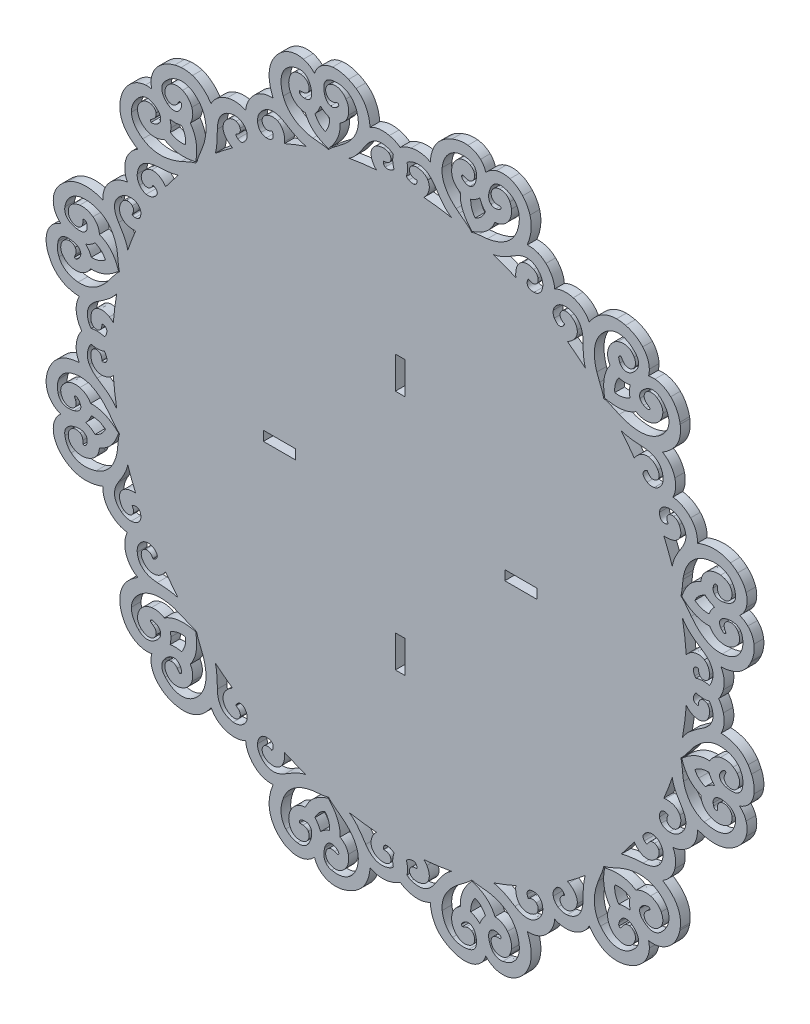
SolidWorks part; units mm, degrees
ref_plane "Plano frontal" through (0, 0, 0) normal (0, 0, 1) x (1, 0, 0)
ref_plane "Plano superior" through (0, 0, 0) normal (0, 1, 0) x (1, 0, 0)
ref_plane "Plano direito" through (0, 0, 0) normal (1, 0, 0) x (0, 0, -1)
sketch "Model" plane through (0, 0, 0) normal (0, 0, 1) x (1, 0, 0)
  line L40 (69.8972, 45.4539) -> (69.8919, 45.449)
  line L41 (69.8919, 45.449) -> (69.8864, 45.4443)
  line L42 (56.8895, 34.9278) -> (56.8876, 34.9201)
  line L43 (46.6898, 12.6446) -> (46.6802, 12.6421)
  line L44 (46.6802, 12.6421) -> (46.6705, 12.6401)
  line L45 (35.8472, 13.1329) -> (35.8376, 13.1302)
  line L46 (30.1967, 9.8007) -> (30.1907, 9.795)
  line L47 (9.1346, -1.9268) -> (9.1262, -1.9212)
  line L48 (-9.1262, -1.9212) -> (-9.1345, -1.9268)
  line L49 (-30.1907, 9.795) -> (-30.1967, 9.8007)
  line L50 (-35.8377, 13.1302) -> (-35.8472, 13.1329)
  line L51 (-44.8206, 12.4046) -> (-44.8319, 12.4046)
  line L52 (-46.6802, 12.6422) -> (-46.6898, 12.6446)
  line L53 (-56.8876, 34.9201) -> (-56.8895, 34.9278)
  line L54 (-72.7705, 59.8371) -> (-72.6371, 60.1312)
  line L55 (-69.8972, 94.5062) -> (-69.8918, 94.5111)
  line L56 (-69.8918, 94.5111) -> (-69.8863, 94.5158)
  line L57 (-56.8895, 105.0323) -> (-56.8876, 105.04)
  line L58 (-46.6898, 127.3156) -> (-46.6802, 127.3181)
  line L59 (-46.6802, 127.3181) -> (-46.6705, 127.3201)
  line L60 (-35.8472, 126.8272) -> (-35.8377, 126.8299)
  line L61 (-30.1967, 130.1594) -> (-30.1907, 130.1651)
  line L62 (-9.1345, 141.8869) -> (-9.1262, 141.8813)
  line L63 (9.1262, 141.8813) -> (9.1346, 141.8869)
  line L64 (30.1907, 130.1651) -> (30.1967, 130.1594)
  line L65 (35.8376, 126.8299) -> (35.8472, 126.8272)
  line L66 (44.8207, 127.5555) -> (44.832, 127.5555)
  line L67 (46.6801, 127.3179) -> (46.6897, 127.3156)
  line L68 (56.8876, 105.04) -> (56.8895, 105.0323)
  line L69 (72.7705, 80.1231) -> (72.6371, 79.829)
  line L70 (64.4726, 72.1634) -> (64.4757, 72.1712)
  line L71 (61.7887, 73.1734) -> (61.7891, 73.1807)
  line L72 (61.7891, 73.1807) -> (61.7897, 73.1881)
  line L73 (64.4757, 67.789) -> (64.4726, 67.7967)
  line L74 (61.7897, 66.772) -> (61.7891, 66.7794)
  line L75 (61.7891, 66.7794) -> (61.7887, 66.7868)
  line L76 (38.2715, 115.7249) -> (38.2692, 115.7329)
  line L77 (50.44, 114.8513) -> (50.4487, 114.8466)
  line L78 (51.187, 115.3877) -> (51.1651, 115.4004)
  line L79 (51.1651, 115.4004) -> (51.1448, 115.4157)
  line L80 (42.6296, 112.05) -> (42.3541, 112.1092)
  line L81 (42.3541, 112.1092) -> (42.3064, 112.3873)
  line L82 (46.1649, 120.6013) -> (46.1614, 120.6063)
  line L83 (46.1614, 120.6063) -> (46.1581, 120.6114)
  line L84 (26.6751, 125.4796) -> (26.6693, 125.4832)
  line L85 (26.6693, 125.4832) -> (26.6637, 125.487)
  line L86 (23.7768, 128.3183) -> (23.768, 128.3129)
  line L87 (51.2568, 103.3632) -> (51.2534, 103.3708)
  line L88 (50.5912, 103.1478) -> (50.5865, 103.1426)
  line L89 (50.5865, 103.1426) -> (50.5816, 103.1376)
  line L90 (50.5816, 36.8225) -> (50.5865, 36.8175)
  line L91 (50.5865, 36.8175) -> (50.5912, 36.8124)
  line L92 (51.2534, 36.5894) -> (51.2568, 36.5969)
  line L93 (46.1581, 19.3488) -> (46.1614, 19.3539)
  line L94 (46.1614, 19.3539) -> (46.1649, 19.3589)
  line L95 (42.3064, 27.5728) -> (42.3541, 27.851)
  line L96 (42.3541, 27.851) -> (42.6296, 27.9102)
  line L97 (51.1448, 24.5445) -> (51.1651, 24.5597)
  line L98 (51.1651, 24.5597) -> (51.187, 24.5724)
  line L99 (50.4487, 25.1136) -> (50.44, 25.1089)
  line L100 (38.2692, 24.2272) -> (38.2715, 24.2353)
  line L101 (23.768, 11.6473) -> (23.7768, 11.6418)
  line L102 (26.6637, 14.4732) -> (26.6693, 14.477)
  line L103 (26.6693, 14.477) -> (26.6751, 14.4806)
  line L104 (-26.6751, 14.4806) -> (-26.6693, 14.477)
  line L105 (-26.6693, 14.477) -> (-26.6637, 14.4732)
  line L106 (-23.7768, 11.6418) -> (-23.768, 11.6473)
  line L107 (-38.2715, 24.2353) -> (-38.2693, 24.2273)
  line L108 (-50.44, 25.1089) -> (-50.4487, 25.1136)
  line L109 (-51.1869, 24.5724) -> (-51.165, 24.5597)
  line L110 (-51.165, 24.5597) -> (-51.1448, 24.5445)
  line L111 (-42.6295, 27.9102) -> (-42.354, 27.851)
  line L112 (-42.354, 27.851) -> (-42.3063, 27.5728)
  line L113 (-46.1648, 19.3589) -> (-46.1614, 19.3539)
  line L114 (-46.1614, 19.3539) -> (-46.1581, 19.3488)
  line L115 (-51.2568, 36.5969) -> (-51.2534, 36.5894)
  line L116 (-50.5912, 36.8124) -> (-50.5865, 36.8175)
  line L117 (-50.5865, 36.8175) -> (-50.5816, 36.8225)
  line L118 (-61.7887, 66.7868) -> (-61.789, 66.7794)
  line L119 (-61.789, 66.7794) -> (-61.7897, 66.772)
  line L120 (-64.4725, 67.7967) -> (-64.4756, 67.789)
  line L121 (-64.4756, 72.1712) -> (-64.4725, 72.1634)
  line L122 (-61.7897, 73.1881) -> (-61.789, 73.1807)
  line L123 (-61.789, 73.1807) -> (-61.7887, 73.1734)
  line L124 (-50.5816, 103.1376) -> (-50.5865, 103.1426)
  line L125 (-50.5865, 103.1426) -> (-50.5912, 103.1478)
  line L126 (-51.2534, 103.3708) -> (-51.2568, 103.3632)
  line L127 (-42.3063, 112.3873) -> (-42.354, 112.1092)
  line L128 (-42.354, 112.1092) -> (-42.6295, 112.05)
  line L129 (-51.1448, 115.4157) -> (-51.165, 115.4004)
  line L130 (-51.165, 115.4004) -> (-51.1869, 115.3878)
  line L131 (-50.4487, 114.8466) -> (-50.44, 114.8513)
  line L132 (-46.1581, 120.6114) -> (-46.1614, 120.6063)
  line L133 (-46.1614, 120.6063) -> (-46.1648, 120.6013)
  line L134 (-38.2693, 115.7329) -> (-38.2715, 115.7248)
  line L135 (-23.768, 128.3129) -> (-23.7768, 128.3183)
  line L136 (-26.6637, 125.4869) -> (-26.6693, 125.4832)
  line L137 (-26.6693, 125.4832) -> (-26.6751, 125.4796)
  line L138 (-15.121, 11.6234) -> (-14.8597, 11.7095)
  line L139 (-14.8597, 11.7095) -> (-14.678, 11.5028)
  line L140 (-11.5918, 9.2509) -> (-11.5991, 9.2573)
  line L141 (-23.6786, 1.7924) -> (-23.6743, 1.7877)
  line L142 (-23.6743, 1.7877) -> (-23.6701, 1.7828)
  line L143 (-20.5859, 4.2883) -> (-20.5794, 4.2882)
  line L144 (-20.5794, 4.2882) -> (-20.573, 4.2878)
  line L145 (-20.1427, 4.2725) -> (-20.1242, 4.2733)
  line L146 (-20.1242, 4.2733) -> (-20.1058, 4.2724)
  line L147 (-23.0532, 3.5986) -> (-23.0546, 3.6072)
  line L148 (-23.0546, 3.6072) -> (-23.0557, 3.6158)
  line L149 (-58.5333, 55.6527) -> (-58.324, 55.4693)
  line L150 (-58.324, 55.4693) -> (-58.4129, 55.2053)
  line L151 (-70.6735, 59.039) -> (-70.6777, 59.0288)
  line L152 (-67.2324, 56.9306) -> (-67.2247, 56.916)
  line L153 (-67.2247, 56.916) -> (-67.2183, 56.9008)
  line L154 (14.6779, 11.5028) -> (14.8597, 11.7095)
  line L155 (14.8597, 11.7095) -> (15.1209, 11.6234)
  line L156 (23.0557, 3.6158) -> (23.0546, 3.6072)
  line L157 (23.0546, 3.6072) -> (23.0532, 3.5987)
  line L158 (20.1057, 4.2724) -> (20.1242, 4.2733)
  line L159 (20.1242, 4.2733) -> (20.1427, 4.2725)
  line L160 (20.573, 4.2878) -> (20.5794, 4.2882)
  line L161 (20.5794, 4.2882) -> (20.5859, 4.2883)
  line L162 (23.6701, 1.7828) -> (23.6743, 1.7877)
  line L163 (23.6743, 1.7877) -> (23.6786, 1.7924)
  line L164 (11.6064, 9.2638) -> (11.5993, 9.2572)
  line L165 (11.5993, 9.2572) -> (11.5918, 9.2509)
  line L166 (58.4129, 55.2053) -> (58.324, 55.4693)
  line L167 (58.324, 55.4693) -> (58.5333, 55.6527)
  line L168 (67.2183, 56.9008) -> (67.2248, 56.916)
  line L169 (67.2248, 56.916) -> (67.2324, 56.9306)
  line L170 (70.6778, 59.0288) -> (70.6736, 59.039)
  line L171 (-23.6701, 138.1773) -> (-23.6743, 138.1724)
  line L172 (-23.6743, 138.1724) -> (-23.6786, 138.1677)
  line L173 (-11.5991, 130.7028) -> (-11.5918, 130.7092)
  line L174 (-14.678, 128.4574) -> (-14.8597, 128.2507)
  line L175 (-14.8597, 128.2507) -> (-15.121, 128.3367)
  line L176 (-23.0557, 136.3443) -> (-23.0546, 136.3529)
  line L177 (-23.0546, 136.3529) -> (-23.0532, 136.3615)
  line L178 (-20.1058, 135.6878) -> (-20.1242, 135.6869)
  line L179 (-20.1242, 135.6869) -> (-20.1427, 135.6877)
  line L180 (-20.5728, 135.6723) -> (-20.5793, 135.672)
  line L181 (-20.5793, 135.672) -> (-20.5859, 135.6718)
  line L182 (-58.4129, 84.7548) -> (-58.324, 84.4908)
  line L183 (-58.324, 84.4908) -> (-58.5333, 84.3074)
  line L184 (-67.2183, 83.0593) -> (-67.2247, 83.0442)
  line L185 (-67.2247, 83.0442) -> (-67.2324, 83.0296)
  line L186 (-70.6777, 80.9313) -> (-70.6735, 80.9211)
  line L187 (11.5918, 130.7092) -> (11.5993, 130.7029)
  line L188 (11.5993, 130.7029) -> (11.6064, 130.6963)
  line L189 (23.6786, 138.1677) -> (23.6743, 138.1724)
  line L190 (23.6743, 138.1724) -> (23.6701, 138.1773)
  line L191 (20.5859, 135.6718) -> (20.5793, 135.672)
  line L192 (20.5793, 135.672) -> (20.5728, 135.6723)
  line L193 (20.1427, 135.6877) -> (20.1242, 135.6869)
  line L194 (20.1242, 135.6869) -> (20.1057, 135.6878)
  line L195 (23.0532, 136.3614) -> (23.0546, 136.3529)
  line L196 (23.0546, 136.3529) -> (23.0557, 136.3443)
  line L197 (15.1209, 128.3367) -> (14.8597, 128.2507)
  line L198 (14.8597, 128.2507) -> (14.6779, 128.4574)
  line L199 (58.5333, 84.3074) -> (58.324, 84.4908)
  line L200 (58.324, 84.4908) -> (58.4129, 84.7548)
  line L201 (70.6736, 80.9211) -> (70.6778, 80.9313)
  line L202 (67.2324, 83.0296) -> (67.2248, 83.0442)
  line L203 (67.2248, 83.0442) -> (67.2183, 83.0593)
  line L204 (1, 41.6467) -> (1, 48.3134)
  line L205 (1, 48.3134) -> (-1, 48.3134)
  line L206 (-1, 48.3134) -> (-1, 41.6467)
  line L207 (-1, 41.6467) -> (1, 41.6467)
  line L208 (-21.6667, 70.9801) -> (-28.3333, 70.9801)
  line L209 (-28.3333, 70.9801) -> (-28.3333, 68.9801)
  line L210 (-28.3333, 68.9801) -> (-21.6667, 68.9801)
  line L211 (-21.6667, 68.9801) -> (-21.6667, 70.9801)
  line L212 (1, 91.6467) -> (1, 98.3134)
  line L213 (1, 98.3134) -> (-1, 98.3134)
  line L214 (-1, 98.3134) -> (-1, 91.6467)
  line L215 (-1, 91.6467) -> (1, 91.6467)
  line L216 (28.3333, 70.9801) -> (21.6667, 70.9801)
  line L217 (21.6667, 70.9801) -> (21.6667, 68.9801)
  line L218 (21.6667, 68.9801) -> (28.3333, 68.9801)
  line L219 (28.3333, 68.9801) -> (28.3333, 70.9801)
  spline S165 degree 3 poles (65.9479, 69.9801) (66.4183, 69.3729) (66.7428, 68.6516) (66.9323, 67.9104) knots 0 0 0 0 0.005128 0.005128 0.005128 0.005128
  spline S166 degree 3 poles (66.9323, 67.9104) (67.2822, 66.5426) (67.1098, 65.2221) (66.4568, 64.0331) knots 0.005128 0.005128 0.005128 0.005128 0.010256 0.010256 0.010256 0.010256
  spline S167 degree 3 poles (66.4568, 64.0331) (68.7071, 63.9327) (70.7348, 63.1507) (72.0623, 61.164) knots 0.010256 0.010256 0.010256 0.010256 0.015385 0.015385 0.015385 0.015385
  spline S168 degree 3 poles (72.0623, 61.164) (72.3387, 60.7504) (72.5701, 60.2928) (72.7703, 59.8375) knots 0.015385 0.015385 0.015385 0.015385 0.020513 0.020513 0.020513 0.020513
  spline S169 degree 3 poles (72.7703, 59.8375) (73.2216, 58.8111) (73.4387, 57.668) (73.2834, 56.5506) knots 0.020513 0.020513 0.020513 0.020513 0.025641 0.025641 0.025641 0.025641
  spline S170 degree 3 poles (73.2834, 56.5506) (73.1459, 55.5609) (72.7216, 54.6366) (72.0091, 53.9306) knots 0.025641 0.025641 0.025641 0.025641 0.030769 0.030769 0.030769 0.030769
  spline S171 degree 3 poles (72.0091, 53.9306) (71.5182, 53.4442) (70.9314, 53.1014) (70.2908, 52.8974) knots 0.030769 0.030769 0.030769 0.030769 0.035897 0.035897 0.035897 0.035897
  spline S172 degree 3 poles (70.2908, 52.8974) (70.9135, 52.3599) (71.3874, 51.673) (71.6445, 50.8674) knots 0.035897 0.035897 0.035897 0.035897 0.041026 0.041026 0.041026 0.041026
  spline S173 degree 3 poles (71.6445, 50.8674) (71.9335, 49.9622) (71.9163, 49.0023) (71.6374, 48.097) knots 0.041026 0.041026 0.041026 0.041026 0.046154 0.046154 0.046154 0.046154
  spline S174 degree 3 poles (71.6374, 48.097) (71.3202, 47.0678) (70.689, 46.1737) (69.8972, 45.4539) knots 0.046154 0.046154 0.046154 0.046154 0.051282 0.051282 0.051282 0.051282
  spline S175 degree 3 poles (69.8864, 45.4443) (69.5633, 45.1705) (69.2343, 44.9092) (68.8791, 44.6781) knots 0.061538 0.061538 0.061538 0.061538 0.066667 0.066667 0.066667 0.066667
  spline S176 degree 3 poles (68.8791, 44.6781) (66.5989, 43.1945) (63.9695, 43.3771) (61.5438, 44.3061) knots 0.066667 0.066667 0.066667 0.066667 0.071795 0.071795 0.071795 0.071795
  spline S177 degree 3 poles (61.5438, 44.3061) (61.6574, 42.8722) (61.1757, 41.5602) (60.1553, 40.4603) knots 0.071795 0.071795 0.071795 0.071795 0.076923 0.076923 0.076923 0.076923
  spline S178 degree 3 poles (60.1553, 40.4603) (59.1998, 39.4302) (57.8934, 38.7018) (56.4956, 38.5662) knots 0.076923 0.076923 0.076923 0.076923 0.082051 0.082051 0.082051 0.082051
  spline S179 degree 3 poles (56.4956, 38.5662) (57.0761, 37.4608) (57.1743, 36.1566) (56.8895, 34.9278) knots 0.082051 0.082051 0.082051 0.082051 0.087179 0.087179 0.087179 0.087179
  spline S180 degree 3 poles (56.8876, 34.9201) (56.5142, 33.4379) (55.6, 32.3103) (54.3314, 31.5665) knots 0.092308 0.092308 0.092308 0.092308 0.097436 0.097436 0.097436 0.097436
  spline S181 degree 3 poles (54.3314, 31.5665) (56.8461, 30.0689) (58.4258, 27.8889) (57.9927, 24.756) knots 0.097436 0.097436 0.097436 0.097436 0.102564 0.102564 0.102564 0.102564
  spline S182 degree 3 poles (57.9927, 24.756) (57.9764, 24.6382) (57.9578, 24.5212) (57.9349, 24.4045) knots 0.102564 0.102564 0.102564 0.102564 0.107692 0.107692 0.107692 0.107692
  spline S183 degree 3 poles (57.9349, 24.4045) (57.6685, 23.0447) (57.032, 21.7688) (56.0338, 20.7999) knots 0.107692 0.107692 0.107692 0.107692 0.112821 0.112821 0.112821 0.112821
  spline S184 degree 3 poles (56.0338, 20.7999) (55.1458, 19.9379) (54.0014, 19.3572) (52.7597, 19.2601) knots 0.112821 0.112821 0.112821 0.112821 0.117949 0.117949 0.117949 0.117949
  spline S185 degree 3 poles (52.7597, 19.2601) (52.3148, 19.2253) (51.8705, 19.2548) (51.4382, 19.3463) knots 0.117949 0.117949 0.117949 0.117949 0.123077 0.123077 0.123077 0.123077
  spline S186 degree 3 poles (51.4382, 19.3463) (51.5556, 18.9308) (51.6126, 18.4993) (51.6051, 18.0626) knots 0.123077 0.123077 0.123077 0.123077 0.128205 0.128205 0.128205 0.128205
  spline S187 degree 3 poles (51.6051, 18.0626) (51.5841, 16.8234) (51.057, 15.6644) (50.2418, 14.7464) knots 0.128205 0.128205 0.128205 0.128205 0.133333 0.133333 0.133333 0.133333
  spline S188 degree 3 poles (50.2418, 14.7464) (49.3081, 13.695) (48.042, 12.9955) (46.6898, 12.6446) knots 0.133333 0.133333 0.133333 0.133333 0.138462 0.138462 0.138462 0.138462
  spline S189 degree 3 poles (46.6705, 12.6401) (46.2426, 12.5504) (45.8132, 12.4661) (45.377, 12.4294) knots 0.148718 0.148718 0.148718 0.148718 0.153846 0.153846 0.153846 0.153846
  spline S190 degree 3 poles (45.377, 12.4294) (44.5738, 12.362) (43.7775, 12.4407) (43.0091, 12.6877) knots 0.153846 0.153846 0.153846 0.153846 0.158974 0.158974 0.158974 0.158974
  spline S191 degree 3 poles (43.0091, 12.6877) (41.3665, 13.2157) (40.1103, 14.4206) (39.1596, 15.8201) knots 0.158974 0.158974 0.158974 0.158974 0.164103 0.164103 0.164103 0.164103
  spline S192 degree 3 poles (39.1596, 15.8201) (38.4629, 14.4963) (37.3363, 13.5723) (35.8472, 13.1329) knots 0.164103 0.164103 0.164103 0.164103 0.169231 0.169231 0.169231 0.169231
  spline S193 degree 3 poles (35.8376, 13.1302) (34.5562, 12.7852) (33.172, 12.8563) (32.0038, 13.4619) knots 0.174359 0.174359 0.174359 0.174359 0.179487 0.179487 0.179487 0.179487
  spline S194 degree 3 poles (32.0038, 13.4619) (31.9069, 12.0718) (31.2012, 10.7687) (30.1967, 9.8007) knots 0.179487 0.179487 0.179487 0.179487 0.184615 0.184615 0.184615 0.184615
  spline S195 degree 3 poles (30.1907, 9.795) (29.082, 8.7687) (27.7537, 8.312) (26.3134, 8.4234) knots 0.189744 0.189744 0.189744 0.189744 0.194872 0.194872 0.194872 0.194872
  spline S196 degree 3 poles (26.3134, 8.4234) (27.4619, 5.6694) (27.5931, 2.8173) (25.5995, 0.3419) knots 0.194872 0.194872 0.194872 0.194872 0.2 0.2 0.2 0.2
  spline S197 degree 3 poles (25.5995, 0.3419) (24.26, -1.3214) (22.1602, -2.296) (20.0334, -1.7239) knots 0.2 0.2 0.2 0.2 0.205128 0.205128 0.205128 0.205128
  spline S198 degree 3 poles (20.0334, -1.7239) (19.126, -1.4798) (18.3456, -0.9782) (17.7384, -0.2944) knots 0.205128 0.205128 0.205128 0.205128 0.210256 0.210256 0.210256 0.210256
  spline S199 degree 3 poles (17.7384, -0.2944) (17.5342, -0.9744) (17.1733, -1.5945) (16.6484, -2.1039) knots 0.210256 0.210256 0.210256 0.210256 0.215385 0.215385 0.215385 0.215385
  spline S200 degree 3 poles (16.6484, -2.1039) (15.9325, -2.7986) (15.0047, -3.1955) (14.0208, -3.3143) knots 0.215385 0.215385 0.215385 0.215385 0.220513 0.220513 0.220513 0.220513
  spline S201 degree 3 poles (14.0208, -3.3143) (12.8882, -3.4511) (11.7407, -3.218) (10.7014, -2.7649) knots 0.220513 0.220513 0.220513 0.220513 0.225641 0.225641 0.225641 0.225641
  spline S202 degree 3 poles (10.7014, -2.7649) (10.1478, -2.5236) (9.6401, -2.2567) (9.1346, -1.9268) knots 0.225641 0.225641 0.225641 0.225641 0.230769 0.230769 0.230769 0.230769
  spline S203 degree 3 poles (9.1262, -1.9212) (7.2078, -0.6021) (6.3815, 1.3682) (6.236, 3.588) knots 0.235897 0.235897 0.235897 0.235897 0.241026 0.241026 0.241026 0.241026
  spline S204 degree 3 poles (6.236, 3.588) (5.0092, 2.9106) (3.6434, 2.7362) (2.2461, 3.0808) knots 0.241026 0.241026 0.241026 0.241026 0.246154 0.246154 0.246154 0.246154
  spline S205 degree 3 poles (2.2461, 3.0808) (1.447, 3.2576) (0.6569, 3.5826) (0, 4.0802) knots 0.246154 0.246154 0.246154 0.246154 0.251282 0.251282 0.251282 0.251282
  spline S206 degree 3 poles (0, 4.0802) (-0.6567, 3.5827) (-1.4457, 3.2578) (-2.2363, 3.0831) knots 0.251282 0.251282 0.251282 0.251282 0.25641 0.25641 0.25641 0.25641
  spline S207 degree 3 poles (-2.2363, 3.0831) (-3.6419, 2.7366) (-5.009, 2.9106) (-6.236, 3.588) knots 0.25641 0.25641 0.25641 0.25641 0.261538 0.261538 0.261538 0.261538
  spline S208 degree 3 poles (-6.236, 3.588) (-6.3815, 1.3683) (-7.2078, -0.602) (-9.1262, -1.9212) knots 0.261538 0.261538 0.261538 0.261538 0.266667 0.266667 0.266667 0.266667
  spline S209 degree 3 poles (-9.1345, -1.9268) (-9.6401, -2.2567) (-10.1478, -2.5236) (-10.7014, -2.7649) knots 0.271795 0.271795 0.271795 0.271795 0.276923 0.276923 0.276923 0.276923
  spline S210 degree 3 poles (-10.7014, -2.7649) (-11.7407, -3.218) (-12.8881, -3.4511) (-14.0208, -3.3143) knots 0.276923 0.276923 0.276923 0.276923 0.282051 0.282051 0.282051 0.282051
  spline S211 degree 3 poles (-14.0208, -3.3143) (-15.0046, -3.1955) (-15.9324, -2.7986) (-16.6483, -2.1039) knots 0.282051 0.282051 0.282051 0.282051 0.287179 0.287179 0.287179 0.287179
  spline S212 degree 3 poles (-16.6483, -2.1039) (-17.1733, -1.5945) (-17.5342, -0.9742) (-17.7385, -0.2941) knots 0.287179 0.287179 0.287179 0.287179 0.292308 0.292308 0.292308 0.292308
  spline S213 degree 3 poles (-17.7385, -0.2941) (-18.321, -0.9498) (-19.0641, -1.4403) (-19.9251, -1.6964) knots 0.292308 0.292308 0.292308 0.292308 0.297436 0.297436 0.297436 0.297436
  spline S214 degree 3 poles (-19.9251, -1.6964) (-20.8455, -1.9701) (-21.8174, -1.9492) (-22.7328, -1.6658) knots 0.297436 0.297436 0.297436 0.297436 0.302564 0.302564 0.302564 0.302564
  spline S215 degree 3 poles (-22.7328, -1.6658) (-23.7606, -1.3477) (-24.6529, -0.7226) (-25.3688, 0.0746) knots 0.302564 0.302564 0.302564 0.302564 0.307692 0.307692 0.307692 0.307692
  spline S216 degree 3 poles (-25.3688, 0.0746) (-26.0709, 0.8565) (-26.5959, 1.7542) (-26.886, 2.7674) knots 0.307692 0.307692 0.307692 0.307692 0.312821 0.312821 0.312821 0.312821
  spline S217 degree 3 poles (-26.886, 2.7674) (-27.4299, 4.6673) (-27.0576, 6.6361) (-26.3131, 8.4234) knots 0.312821 0.312821 0.312821 0.312821 0.317949 0.317949 0.317949 0.317949
  spline S218 degree 3 poles (-26.3131, 8.4234) (-27.7536, 8.312) (-29.0819, 8.7686) (-30.1907, 9.795) knots 0.317949 0.317949 0.317949 0.317949 0.323077 0.323077 0.323077 0.323077
  spline S219 degree 3 poles (-30.1967, 9.8007) (-31.2012, 10.7687) (-31.9069, 12.0718) (-32.0038, 13.462) knots 0.328205 0.328205 0.328205 0.328205 0.333333 0.333333 0.333333 0.333333
  spline S220 degree 3 poles (-32.0038, 13.462) (-33.1719, 12.8563) (-34.5563, 12.7852) (-35.8377, 13.1302) knots 0.333333 0.333333 0.333333 0.333333 0.338462 0.338462 0.338462 0.338462
  spline S221 degree 3 poles (-35.8472, 13.1329) (-37.3363, 13.5723) (-38.4628, 14.4963) (-39.1595, 15.8201) knots 0.34359 0.34359 0.34359 0.34359 0.348718 0.348718 0.348718 0.348718
  spline S222 degree 3 poles (-39.1595, 15.8201) (-40.4907, 13.8597) (-42.3201, 12.4297) (-44.8206, 12.4046) knots 0.348718 0.348718 0.348718 0.348718 0.353846 0.353846 0.353846 0.353846
  spline S223 degree 3 poles (-44.8319, 12.4046) (-45.4723, 12.4155) (-46.0561, 12.4959) (-46.6802, 12.6422) knots 0.358974 0.358974 0.358974 0.358974 0.364103 0.364103 0.364103 0.364103
  spline S224 degree 3 poles (-46.6898, 12.6446) (-48.042, 12.9955) (-49.3081, 13.695) (-50.2418, 14.7464) knots 0.369231 0.369231 0.369231 0.369231 0.374359 0.374359 0.374359 0.374359
  spline S225 degree 3 poles (-50.2418, 14.7464) (-51.057, 15.6644) (-51.584, 16.8234) (-51.6051, 18.0626) knots 0.374359 0.374359 0.374359 0.374359 0.379487 0.379487 0.379487 0.379487
  spline S226 degree 3 poles (-51.6051, 18.0626) (-51.6126, 18.4993) (-51.5555, 18.9308) (-51.4382, 19.3463) knots 0.379487 0.379487 0.379487 0.379487 0.384615 0.384615 0.384615 0.384615
  spline S227 degree 3 poles (-51.4382, 19.3463) (-51.8705, 19.2548) (-52.3149, 19.2253) (-52.7597, 19.2601) knots 0.384615 0.384615 0.384615 0.384615 0.389744 0.389744 0.389744 0.389744
  spline S228 degree 3 poles (-52.7597, 19.2601) (-54.0014, 19.3572) (-55.1458, 19.9379) (-56.0338, 20.7999) knots 0.389744 0.389744 0.389744 0.389744 0.394872 0.394872 0.394872 0.394872
  spline S229 degree 3 poles (-56.0338, 20.7999) (-57.0319, 21.7688) (-57.6685, 23.0447) (-57.9348, 24.4045) knots 0.394872 0.394872 0.394872 0.394872 0.4 0.4 0.4 0.4
  spline S230 degree 3 poles (-57.9348, 24.4045) (-57.9577, 24.5212) (-57.9765, 24.6382) (-57.9928, 24.756) knots 0.4 0.4 0.4 0.4 0.405128 0.405128 0.405128 0.405128
  spline S231 degree 3 poles (-57.9928, 24.756) (-58.4258, 27.8889) (-56.8461, 30.0689) (-54.3314, 31.5665) knots 0.405128 0.405128 0.405128 0.405128 0.410256 0.410256 0.410256 0.410256
  spline S232 degree 3 poles (-54.3314, 31.5665) (-55.5999, 32.3103) (-56.5142, 33.4378) (-56.8876, 34.9201) knots 0.410256 0.410256 0.410256 0.410256 0.415385 0.415385 0.415385 0.415385
  spline S233 degree 3 poles (-56.8895, 34.9278) (-57.1743, 36.1566) (-57.076, 37.4608) (-56.4956, 38.5662) knots 0.420513 0.420513 0.420513 0.420513 0.425641 0.425641 0.425641 0.425641
  spline S234 degree 3 poles (-56.4956, 38.5662) (-57.8934, 38.7018) (-59.1997, 39.4302) (-60.1553, 40.4603) knots 0.425641 0.425641 0.425641 0.425641 0.430769 0.430769 0.430769 0.430769
  spline S235 degree 3 poles (-60.1553, 40.4603) (-61.1756, 41.5601) (-61.6574, 42.872) (-61.5438, 44.3058) knots 0.430769 0.430769 0.430769 0.430769 0.435897 0.435897 0.435897 0.435897
  spline S236 degree 3 poles (-61.5438, 44.3058) (-63.785, 43.4462) (-66.1964, 43.2223) (-68.3996, 44.3937) knots 0.435897 0.435897 0.435897 0.435897 0.441026 0.441026 0.441026 0.441026
  spline S237 degree 3 poles (-68.3996, 44.3937) (-68.9525, 44.6876) (-69.4317, 45.0328) (-69.8964, 45.4532) knots 0.441026 0.441026 0.441026 0.441026 0.446154 0.446154 0.446154 0.446154
  spline S238 degree 3 poles (-69.8964, 45.4532) (-70.6891, 46.1701) (-71.3208, 47.0618) (-71.6386, 48.0895) knots 0.446154 0.446154 0.446154 0.446154 0.451282 0.451282 0.451282 0.451282
  spline S239 degree 3 poles (-71.6386, 48.0895) (-71.9183, 48.9937) (-71.936, 49.9526) (-71.6488, 50.8574) knots 0.451282 0.451282 0.451282 0.451282 0.45641 0.45641 0.45641 0.45641
  spline S240 degree 3 poles (-71.6488, 50.8574) (-71.3918, 51.6668) (-70.9162, 52.3575) (-70.2907, 52.8974) knots 0.45641 0.45641 0.45641 0.45641 0.461538 0.461538 0.461538 0.461538
  spline S241 degree 3 poles (-70.2907, 52.8974) (-70.9314, 53.1014) (-71.5182, 53.4442) (-72.0091, 53.9306) knots 0.461538 0.461538 0.461538 0.461538 0.466667 0.466667 0.466667 0.466667
  spline S242 degree 3 poles (-72.0091, 53.9306) (-72.7216, 54.6366) (-73.1454, 55.5606) (-73.2826, 56.5503) knots 0.466667 0.466667 0.466667 0.466667 0.471795 0.471795 0.471795 0.471795
  spline S243 degree 3 poles (-73.2826, 56.5503) (-73.4375, 57.6676) (-73.2206, 58.8105) (-72.7705, 59.8371) knots 0.471795 0.471795 0.471795 0.471795 0.476923 0.476923 0.476923 0.476923
  spline S244 degree 3 poles (-72.6371, 60.1312) (-71.4341, 62.782) (-69.1843, 63.9089) (-66.4566, 64.0327) knots 0.482051 0.482051 0.482051 0.482051 0.487179 0.487179 0.487179 0.487179
  spline S245 degree 3 poles (-66.4566, 64.0327) (-67.1097, 65.2218) (-67.2822, 66.5424) (-66.9323, 67.9104) knots 0.487179 0.487179 0.487179 0.487179 0.492308 0.492308 0.492308 0.492308
  spline S246 degree 3 poles (-66.9323, 67.9104) (-66.7427, 68.6516) (-66.4182, 69.3729) (-65.9479, 69.9801) knots 0.492308 0.492308 0.492308 0.492308 0.497436 0.497436 0.497436 0.497436
  spline S247 degree 3 poles (-65.9479, 69.9801) (-66.4182, 70.5873) (-66.7427, 71.3085) (-66.9323, 72.0498) knots 0.497436 0.497436 0.497436 0.497436 0.502564 0.502564 0.502564 0.502564
  spline S248 degree 3 poles (-66.9323, 72.0498) (-67.2822, 73.4176) (-67.1097, 74.7381) (-66.4567, 75.9271) knots 0.502564 0.502564 0.502564 0.502564 0.507692 0.507692 0.507692 0.507692
  spline S249 degree 3 poles (-66.4567, 75.9271) (-68.7071, 76.0274) (-70.7348, 76.8095) (-72.0623, 78.7962) knots 0.507692 0.507692 0.507692 0.507692 0.512821 0.512821 0.512821 0.512821
  spline S250 degree 3 poles (-72.0623, 78.7962) (-72.3386, 79.2097) (-72.5701, 79.6673) (-72.7703, 80.1226) knots 0.512821 0.512821 0.512821 0.512821 0.517949 0.517949 0.517949 0.517949
  spline S251 degree 3 poles (-72.7703, 80.1226) (-73.2216, 81.149) (-73.4387, 82.2921) (-73.2834, 83.4096) knots 0.517949 0.517949 0.517949 0.517949 0.523077 0.523077 0.523077 0.523077
  spline S252 degree 3 poles (-73.2834, 83.4096) (-73.1459, 84.3992) (-72.7216, 85.3235) (-72.0091, 86.0295) knots 0.523077 0.523077 0.523077 0.523077 0.528205 0.528205 0.528205 0.528205
  spline S253 degree 3 poles (-72.0091, 86.0295) (-71.5182, 86.516) (-70.9314, 86.8587) (-70.2907, 87.0627) knots 0.528205 0.528205 0.528205 0.528205 0.533333 0.533333 0.533333 0.533333
  spline S254 degree 3 poles (-70.2907, 87.0627) (-70.9134, 87.6002) (-71.3874, 88.2872) (-71.6445, 89.0927) knots 0.533333 0.533333 0.533333 0.533333 0.538462 0.538462 0.538462 0.538462
  spline S255 degree 3 poles (-71.6445, 89.0927) (-71.9334, 89.998) (-71.9163, 90.9578) (-71.6373, 91.8631) knots 0.538462 0.538462 0.538462 0.538462 0.54359 0.54359 0.54359 0.54359
  spline S256 degree 3 poles (-71.6373, 91.8631) (-71.3202, 92.8923) (-70.689, 93.7864) (-69.8972, 94.5062) knots 0.54359 0.54359 0.54359 0.54359 0.548718 0.548718 0.548718 0.548718
  spline S257 degree 3 poles (-69.8863, 94.5158) (-69.5633, 94.7896) (-69.2342, 95.0509) (-68.8791, 95.282) knots 0.558974 0.558974 0.558974 0.558974 0.564103 0.564103 0.564103 0.564103
  spline S258 degree 3 poles (-68.8791, 95.282) (-66.599, 96.7656) (-63.9694, 96.583) (-61.5438, 95.6541) knots 0.564103 0.564103 0.564103 0.564103 0.569231 0.569231 0.569231 0.569231
  spline S259 degree 3 poles (-61.5438, 95.6541) (-61.6574, 97.0879) (-61.1756, 98.3999) (-60.1553, 99.4999) knots 0.569231 0.569231 0.569231 0.569231 0.574359 0.574359 0.574359 0.574359
  spline S260 degree 3 poles (-60.1553, 99.4999) (-59.1998, 100.5299) (-57.8934, 101.2583) (-56.4956, 101.3939) knots 0.574359 0.574359 0.574359 0.574359 0.579487 0.579487 0.579487 0.579487
  spline S261 degree 3 poles (-56.4956, 101.3939) (-57.076, 102.4994) (-57.1743, 103.8035) (-56.8895, 105.0323) knots 0.579487 0.579487 0.579487 0.579487 0.584615 0.584615 0.584615 0.584615
  spline S262 degree 3 poles (-56.8876, 105.04) (-56.5142, 106.5223) (-55.5999, 107.6499) (-54.3314, 108.3936) knots 0.589744 0.589744 0.589744 0.589744 0.594872 0.594872 0.594872 0.594872
  spline S263 degree 3 poles (-54.3314, 108.3936) (-56.8461, 109.8913) (-58.4258, 112.0712) (-57.9928, 115.2042) knots 0.594872 0.594872 0.594872 0.594872 0.6 0.6 0.6 0.6
  spline S264 degree 3 poles (-57.9928, 115.2042) (-57.9765, 115.322) (-57.9577, 115.439) (-57.9348, 115.5557) knots 0.6 0.6 0.6 0.6 0.605128 0.605128 0.605128 0.605128
  spline S265 degree 3 poles (-57.9348, 115.5557) (-57.6685, 116.9155) (-57.0319, 118.1914) (-56.0338, 119.1603) knots 0.605128 0.605128 0.605128 0.605128 0.610256 0.610256 0.610256 0.610256
  spline S266 degree 3 poles (-56.0338, 119.1603) (-55.1458, 120.0222) (-54.0014, 120.6029) (-52.7598, 120.7001) knots 0.610256 0.610256 0.610256 0.610256 0.615385 0.615385 0.615385 0.615385
  spline S267 degree 3 poles (-52.7598, 120.7001) (-52.3149, 120.7349) (-51.8705, 120.7053) (-51.4382, 120.6138) knots 0.615385 0.615385 0.615385 0.615385 0.620513 0.620513 0.620513 0.620513
  spline S268 degree 3 poles (-51.4382, 120.6138) (-51.5556, 121.0294) (-51.6126, 121.4609) (-51.6051, 121.8977) knots 0.620513 0.620513 0.620513 0.620513 0.625641 0.625641 0.625641 0.625641
  spline S269 degree 3 poles (-51.6051, 121.8977) (-51.584, 123.1369) (-51.0569, 124.2958) (-50.2418, 125.2138) knots 0.625641 0.625641 0.625641 0.625641 0.630769 0.630769 0.630769 0.630769
  spline S270 degree 3 poles (-50.2418, 125.2138) (-49.3081, 126.2652) (-48.042, 126.9647) (-46.6898, 127.3156) knots 0.630769 0.630769 0.630769 0.630769 0.635897 0.635897 0.635897 0.635897
  spline S271 degree 3 poles (-46.6705, 127.3201) (-46.2426, 127.4097) (-45.8132, 127.494) (-45.377, 127.5307) knots 0.646154 0.646154 0.646154 0.646154 0.651282 0.651282 0.651282 0.651282
  spline S272 degree 3 poles (-45.377, 127.5307) (-44.5738, 127.5981) (-43.7775, 127.5194) (-43.0091, 127.2724) knots 0.651282 0.651282 0.651282 0.651282 0.65641 0.65641 0.65641 0.65641
  spline S273 degree 3 poles (-43.0091, 127.2724) (-41.3664, 126.7445) (-40.1102, 125.5395) (-39.1596, 124.14) knots 0.65641 0.65641 0.65641 0.65641 0.661538 0.661538 0.661538 0.661538
  spline S274 degree 3 poles (-39.1596, 124.14) (-38.4628, 125.4638) (-37.3364, 126.3878) (-35.8472, 126.8272) knots 0.661538 0.661538 0.661538 0.661538 0.666667 0.666667 0.666667 0.666667
  spline S275 degree 3 poles (-35.8377, 126.8299) (-34.5563, 127.175) (-33.1719, 127.1039) (-32.0038, 126.4982) knots 0.671795 0.671795 0.671795 0.671795 0.676923 0.676923 0.676923 0.676923
  spline S276 degree 3 poles (-32.0038, 126.4982) (-31.9069, 127.8883) (-31.2012, 129.1914) (-30.1967, 130.1594) knots 0.676923 0.676923 0.676923 0.676923 0.682051 0.682051 0.682051 0.682051
  spline S277 degree 3 poles (-30.1907, 130.1651) (-29.082, 131.1915) (-27.7537, 131.6482) (-26.3134, 131.5368) knots 0.687179 0.687179 0.687179 0.687179 0.692308 0.692308 0.692308 0.692308
  spline S278 degree 3 poles (-26.3134, 131.5368) (-27.4618, 134.2907) (-27.593, 137.1428) (-25.5995, 139.6183) knots 0.692308 0.692308 0.692308 0.692308 0.697436 0.697436 0.697436 0.697436
  spline S279 degree 3 poles (-25.5995, 139.6183) (-24.26, 141.2818) (-22.1599, 142.2562) (-20.033, 141.684) knots 0.697436 0.697436 0.697436 0.697436 0.702564 0.702564 0.702564 0.702564
  spline S280 degree 3 poles (-20.033, 141.684) (-19.1258, 141.4398) (-18.3455, 140.9383) (-17.7384, 140.2546) knots 0.702564 0.702564 0.702564 0.702564 0.707692 0.707692 0.707692 0.707692
  spline S281 degree 3 poles (-17.7384, 140.2546) (-17.5341, 140.9346) (-17.1732, 141.5547) (-16.6483, 142.0641) knots 0.707692 0.707692 0.707692 0.707692 0.712821 0.712821 0.712821 0.712821
  spline S282 degree 3 poles (-16.6483, 142.0641) (-15.9324, 142.7588) (-15.0046, 143.1556) (-14.0208, 143.2745) knots 0.712821 0.712821 0.712821 0.712821 0.717949 0.717949 0.717949 0.717949
  spline S283 degree 3 poles (-14.0208, 143.2745) (-12.8881, 143.4112) (-11.7407, 143.1782) (-10.7014, 142.7251) knots 0.717949 0.717949 0.717949 0.717949 0.723077 0.723077 0.723077 0.723077
  spline S284 degree 3 poles (-10.7014, 142.7251) (-10.1478, 142.4837) (-9.6401, 142.2169) (-9.1345, 141.8869) knots 0.723077 0.723077 0.723077 0.723077 0.728205 0.728205 0.728205 0.728205
  spline S285 degree 3 poles (-9.1262, 141.8813) (-7.2078, 140.5622) (-6.3815, 138.5919) (-6.236, 136.3721) knots 0.733333 0.733333 0.733333 0.733333 0.738462 0.738462 0.738462 0.738462
  spline S286 degree 3 poles (-6.236, 136.3721) (-5.0092, 137.0496) (-3.6434, 137.224) (-2.2461, 136.8794) knots 0.738462 0.738462 0.738462 0.738462 0.74359 0.74359 0.74359 0.74359
  spline S287 degree 3 poles (-2.2461, 136.8794) (-1.447, 136.7026) (-0.6568, 136.3775) (0, 135.8799) knots 0.74359 0.74359 0.74359 0.74359 0.748718 0.748718 0.748718 0.748718
  spline S288 degree 3 poles (0, 135.8799) (0.6567, 136.3775) (1.4457, 136.7023) (2.2363, 136.8771) knots 0.748718 0.748718 0.748718 0.748718 0.753846 0.753846 0.753846 0.753846
  spline S289 degree 3 poles (2.2363, 136.8771) (3.6419, 137.2237) (5.009, 137.0495) (6.236, 136.3721) knots 0.753846 0.753846 0.753846 0.753846 0.758974 0.758974 0.758974 0.758974
  spline S290 degree 3 poles (6.236, 136.3721) (6.3815, 138.5918) (7.2078, 140.5622) (9.1262, 141.8813) knots 0.758974 0.758974 0.758974 0.758974 0.764103 0.764103 0.764103 0.764103
  spline S291 degree 3 poles (9.1346, 141.8869) (9.6401, 142.2169) (10.1478, 142.4837) (10.7014, 142.7251) knots 0.769231 0.769231 0.769231 0.769231 0.774359 0.774359 0.774359 0.774359
  spline S292 degree 3 poles (10.7014, 142.7251) (11.7407, 143.1782) (12.8881, 143.4112) (14.0208, 143.2745) knots 0.774359 0.774359 0.774359 0.774359 0.779487 0.779487 0.779487 0.779487
  spline S293 degree 3 poles (14.0208, 143.2745) (15.0047, 143.1556) (15.9325, 142.7588) (16.6484, 142.0641) knots 0.779487 0.779487 0.779487 0.779487 0.784615 0.784615 0.784615 0.784615
  spline S294 degree 3 poles (16.6484, 142.0641) (17.1734, 141.5546) (17.5343, 140.9344) (17.7385, 140.2543) knots 0.784615 0.784615 0.784615 0.784615 0.789744 0.789744 0.789744 0.789744
  spline S295 degree 3 poles (17.7385, 140.2543) (18.321, 140.9099) (19.0641, 141.4004) (19.925, 141.6565) knots 0.789744 0.789744 0.789744 0.789744 0.794872 0.794872 0.794872 0.794872
  spline S296 degree 3 poles (19.925, 141.6565) (20.8454, 141.9303) (21.8173, 141.9093) (22.7327, 141.626) knots 0.794872 0.794872 0.794872 0.794872 0.8 0.8 0.8 0.8
  spline S297 degree 3 poles (22.7327, 141.626) (23.7606, 141.3079) (24.6528, 140.6827) (25.3688, 139.8855) knots 0.8 0.8 0.8 0.8 0.805128 0.805128 0.805128 0.805128
  spline S298 degree 3 poles (25.3688, 139.8855) (26.0707, 139.1038) (26.5957, 138.2064) (26.8858, 137.1934) knots 0.805128 0.805128 0.805128 0.805128 0.810256 0.810256 0.810256 0.810256
  spline S299 degree 3 poles (26.8858, 137.1934) (27.4299, 135.2933) (27.0577, 133.3243) (26.3132, 131.5368) knots 0.810256 0.810256 0.810256 0.810256 0.815385 0.815385 0.815385 0.815385
  spline S300 degree 3 poles (26.3132, 131.5368) (27.7536, 131.6482) (29.082, 131.1915) (30.1907, 130.1651) knots 0.815385 0.815385 0.815385 0.815385 0.820513 0.820513 0.820513 0.820513
  spline S301 degree 3 poles (30.1967, 130.1594) (31.2012, 129.1914) (31.9069, 127.8883) (32.0038, 126.4982) knots 0.825641 0.825641 0.825641 0.825641 0.830769 0.830769 0.830769 0.830769
  spline S302 degree 3 poles (32.0038, 126.4982) (33.172, 127.1039) (34.5562, 127.175) (35.8376, 126.8299) knots 0.830769 0.830769 0.830769 0.830769 0.835897 0.835897 0.835897 0.835897
  spline S303 degree 3 poles (35.8472, 126.8272) (37.3363, 126.3878) (38.4629, 125.4639) (39.1596, 124.1401) knots 0.841026 0.841026 0.841026 0.841026 0.846154 0.846154 0.846154 0.846154
  spline S304 degree 3 poles (39.1596, 124.1401) (40.4908, 126.1005) (42.3201, 127.5304) (44.8207, 127.5555) knots 0.846154 0.846154 0.846154 0.846154 0.851282 0.851282 0.851282 0.851282
  spline S305 degree 3 poles (44.832, 127.5555) (45.4723, 127.5447) (46.0562, 127.4641) (46.6801, 127.3179) knots 0.85641 0.85641 0.85641 0.85641 0.861538 0.861538 0.861538 0.861538
  spline S306 degree 3 poles (46.6897, 127.3156) (48.042, 126.9647) (49.3081, 126.2652) (50.2417, 125.2138) knots 0.866667 0.866667 0.866667 0.866667 0.871795 0.871795 0.871795 0.871795
  spline S307 degree 3 poles (50.2417, 125.2138) (51.0569, 124.2958) (51.584, 123.1369) (51.6051, 121.8977) knots 0.871795 0.871795 0.871795 0.871795 0.876923 0.876923 0.876923 0.876923
  spline S308 degree 3 poles (51.6051, 121.8977) (51.6126, 121.4609) (51.5556, 121.0294) (51.4382, 120.6138) knots 0.876923 0.876923 0.876923 0.876923 0.882051 0.882051 0.882051 0.882051
  spline S309 degree 3 poles (51.4382, 120.6138) (51.8705, 120.7053) (52.3149, 120.7349) (52.7597, 120.7001) knots 0.882051 0.882051 0.882051 0.882051 0.887179 0.887179 0.887179 0.887179
  spline S310 degree 3 poles (52.7597, 120.7001) (54.0014, 120.6029) (55.1458, 120.0223) (56.0338, 119.1603) knots 0.887179 0.887179 0.887179 0.887179 0.892308 0.892308 0.892308 0.892308
  spline S311 degree 3 poles (56.0338, 119.1603) (57.032, 118.1914) (57.6685, 116.9155) (57.9349, 115.5557) knots 0.892308 0.892308 0.892308 0.892308 0.897436 0.897436 0.897436 0.897436
  spline S312 degree 3 poles (57.9349, 115.5557) (57.9578, 115.439) (57.9764, 115.322) (57.9927, 115.2042) knots 0.897436 0.897436 0.897436 0.897436 0.902564 0.902564 0.902564 0.902564
  spline S313 degree 3 poles (57.9927, 115.2042) (58.4258, 112.0712) (56.8461, 109.8913) (54.3314, 108.3936) knots 0.902564 0.902564 0.902564 0.902564 0.907692 0.907692 0.907692 0.907692
  spline S314 degree 3 poles (54.3314, 108.3936) (55.6, 107.6499) (56.5142, 106.5223) (56.8876, 105.04) knots 0.907692 0.907692 0.907692 0.907692 0.912821 0.912821 0.912821 0.912821
  spline S315 degree 3 poles (56.8895, 105.0323) (57.1743, 103.8035) (57.0761, 102.4994) (56.4956, 101.3939) knots 0.917949 0.917949 0.917949 0.917949 0.923077 0.923077 0.923077 0.923077
  spline S316 degree 3 poles (56.4956, 101.3939) (57.8934, 101.2583) (59.1998, 100.5299) (60.1553, 99.4999) knots 0.923077 0.923077 0.923077 0.923077 0.928205 0.928205 0.928205 0.928205
  spline S317 degree 3 poles (60.1553, 99.4999) (61.1756, 98.4) (61.6574, 97.0881) (61.5438, 95.6543) knots 0.928205 0.928205 0.928205 0.928205 0.933333 0.933333 0.933333 0.933333
  spline S318 degree 3 poles (61.5438, 95.6543) (63.7851, 96.5139) (66.1964, 96.7378) (68.3996, 95.5664) knots 0.933333 0.933333 0.933333 0.933333 0.938462 0.938462 0.938462 0.938462
  spline S319 degree 3 poles (68.3996, 95.5664) (68.9525, 95.2725) (69.4317, 94.9273) (69.8964, 94.5069) knots 0.938462 0.938462 0.938462 0.938462 0.94359 0.94359 0.94359 0.94359
  spline S320 degree 3 poles (69.8964, 94.5069) (70.6891, 93.79) (71.3208, 92.8983) (71.6387, 91.8707) knots 0.94359 0.94359 0.94359 0.94359 0.948718 0.948718 0.948718 0.948718
  spline S321 degree 3 poles (71.6387, 91.8707) (71.9183, 90.9665) (71.936, 90.0075) (71.6488, 89.1028) knots 0.948718 0.948718 0.948718 0.948718 0.953846 0.953846 0.953846 0.953846
  spline S322 degree 3 poles (71.6488, 89.1028) (71.3918, 88.2933) (70.9163, 87.6027) (70.2907, 87.0627) knots 0.953846 0.953846 0.953846 0.953846 0.958974 0.958974 0.958974 0.958974
  spline S323 degree 3 poles (70.2907, 87.0627) (70.9314, 86.8587) (71.5182, 86.516) (72.0091, 86.0295) knots 0.958974 0.958974 0.958974 0.958974 0.964103 0.964103 0.964103 0.964103
  spline S324 degree 3 poles (72.0091, 86.0295) (72.7216, 85.3235) (73.1454, 84.3995) (73.2826, 83.4099) knots 0.964103 0.964103 0.964103 0.964103 0.969231 0.969231 0.969231 0.969231
  spline S325 degree 3 poles (73.2826, 83.4099) (73.4375, 82.2925) (73.2206, 81.1497) (72.7705, 80.1231) knots 0.969231 0.969231 0.969231 0.969231 0.974359 0.974359 0.974359 0.974359
  spline S326 degree 3 poles (72.6371, 79.829) (71.4344, 77.1782) (69.1842, 76.0513) (66.4566, 75.9274) knots 0.979487 0.979487 0.979487 0.979487 0.984615 0.984615 0.984615 0.984615
  spline S327 degree 3 poles (66.4566, 75.9274) (67.1098, 74.7383) (67.2823, 73.4177) (66.9323, 72.0498) knots 0.984615 0.984615 0.984615 0.984615 0.989744 0.989744 0.989744 0.989744
  spline S328 degree 3 poles (66.9323, 72.0498) (66.7428, 71.3085) (66.4183, 70.5872) (65.9479, 69.9801) knots 0.989744 0.989744 0.989744 0.989744 1 1 1 1
  spline S329 degree 3 poles (63.9982, 71.3823) (64.2029, 71.6103) (64.3613, 71.8763) (64.4726, 72.1634) knots 0 0 0 0 0.047619 0.047619 0.047619 0.047619
  spline S330 degree 3 poles (64.4757, 72.1712) (64.8914, 73.184) (64.9321, 74.2138) (64.3898, 75.1861) knots 0.095238 0.095238 0.095238 0.095238 0.142857 0.142857 0.142857 0.142857
  spline S331 degree 3 poles (64.3898, 75.1861) (64.0082, 75.8702) (63.4001, 76.4249) (62.7538, 76.8558) knots 0.142857 0.142857 0.142857 0.142857 0.190476 0.190476 0.190476 0.190476
  spline S332 degree 3 poles (62.7538, 76.8558) (61.1912, 77.8977) (59.6593, 78.8515) (58.6263, 80.4728) knots 0.190476 0.190476 0.190476 0.190476 0.238095 0.238095 0.238095 0.238095
  spline S333 degree 3 poles (58.6263, 80.4728) (58.5707, 80.5602) (58.5144, 80.6471) (58.4573, 80.7336) knots 0.238095 0.238095 0.238095 0.238095 0.285714 0.285714 0.285714 0.285714
  spline S334 degree 3 poles (58.4573, 80.7336) (58.8313, 78.678) (59.0968, 76.5997) (59.2539, 74.5119) knots 0.285714 0.285714 0.285714 0.285714 0.333333 0.333333 0.333333 0.333333
  spline S335 degree 3 poles (59.2539, 74.5119) (59.5067, 74.8637) (59.8289, 75.1546) (60.2085, 75.3696) knots 0.333333 0.333333 0.333333 0.333333 0.380952 0.380952 0.380952 0.380952
  spline S336 degree 3 poles (60.2085, 75.3696) (61.0712, 75.8584) (62.1395, 76.051) (63.0143, 75.4782) knots 0.380952 0.380952 0.380952 0.380952 0.428571 0.428571 0.428571 0.428571
  spline S337 degree 3 poles (63.0143, 75.4782) (63.7397, 75.0031) (64.0585, 74.1698) (64.0807, 73.329) knots 0.428571 0.428571 0.428571 0.428571 0.47619 0.47619 0.47619 0.47619
  spline S338 degree 3 poles (64.0807, 73.329) (64.0919, 72.9085) (63.9859, 72.4725) (63.6943, 72.1571) knots 0.47619 0.47619 0.47619 0.47619 0.52381 0.52381 0.52381 0.52381
  spline S339 degree 3 poles (63.6943, 72.1571) (63.4463, 71.8889) (63.0848, 71.7433) (62.7202, 71.8003) knots 0.52381 0.52381 0.52381 0.52381 0.571429 0.571429 0.571429 0.571429
  spline S340 degree 3 poles (62.7202, 71.8003) (62.0488, 71.9051) (61.7597, 72.5532) (61.7887, 73.1734) knots 0.571429 0.571429 0.571429 0.571429 0.619048 0.619048 0.619048 0.619048
  spline S341 degree 3 poles (61.7897, 73.1881) (61.7917, 73.2122) (61.7937, 73.2719) (61.7743, 73.2923) knots 0.714286 0.714286 0.714286 0.714286 0.761905 0.761905 0.761905 0.761905
  spline S342 degree 3 poles (61.7743, 73.2923) (61.6838, 73.3871) (61.3669, 73.3137) (61.2645, 73.277) knots 0.761905 0.761905 0.761905 0.761905 0.809524 0.809524 0.809524 0.809524
  spline S343 degree 3 poles (61.2645, 73.277) (60.5018, 73.0034) (60.707, 72.1651) (61.0173, 71.6054) knots 0.809524 0.809524 0.809524 0.809524 0.857143 0.857143 0.857143 0.857143
  spline S344 degree 3 poles (61.0173, 71.6054) (61.0824, 71.488) (61.1566, 71.374) (61.2418, 71.2693) knots 0.857143 0.857143 0.857143 0.857143 0.904762 0.904762 0.904762 0.904762
  spline S345 degree 3 poles (61.2418, 71.2693) (62.1085, 71.5957) (63.1131, 71.6598) (63.9982, 71.3823) knots 0.904762 0.904762 0.904762 0.904762 1 1 1 1
  spline S346 degree 3 poles (59.4243, 70.0546) (59.4243, 70.0049) (59.4244, 69.9552) (59.4243, 69.9055) knots 0 0 0 0 0.25 0.25 0.25 0.25
  spline S347 degree 3 poles (59.4243, 69.9055) (59.4427, 69.9306) (59.4614, 69.9554) (59.4804, 69.9801) knots 0.25 0.25 0.25 0.25 0.5 0.5 0.5 0.5
  spline S348 degree 3 poles (59.4804, 69.9801) (59.4614, 70.0047) (59.4427, 70.0295) (59.4243, 70.0546) knots 0.5 0.5 0.5 0.5 1 1 1 1
  spline S349 degree 3 poles (59.2551, 65.4466) (59.0988, 63.3611) (58.834, 61.2851) (58.4607, 59.2317) knots 0 0 0 0 0.047619 0.047619 0.047619 0.047619
  spline S350 degree 3 poles (58.4607, 59.2317) (58.5166, 59.3165) (58.5718, 59.4017) (58.6263, 59.4873) knots 0.047619 0.047619 0.047619 0.047619 0.095238 0.095238 0.095238 0.095238
  spline S351 degree 3 poles (58.6263, 59.4873) (59.6593, 61.1087) (61.1912, 62.0625) (62.7538, 63.1044) knots 0.095238 0.095238 0.095238 0.095238 0.142857 0.142857 0.142857 0.142857
  spline S352 degree 3 poles (62.7538, 63.1044) (62.8695, 63.1815) (62.983, 63.2619) (63.0938, 63.3459) knots 0.142857 0.142857 0.142857 0.142857 0.190476 0.190476 0.190476 0.190476
  spline S353 degree 3 poles (63.0938, 63.3459) (64.5995, 64.4876) (65.2229, 65.9686) (64.4757, 67.789) knots 0.190476 0.190476 0.190476 0.190476 0.238095 0.238095 0.238095 0.238095
  spline S354 degree 3 poles (64.4726, 67.7967) (64.3613, 68.0839) (64.203, 68.3498) (63.9983, 68.5778) knots 0.285714 0.285714 0.285714 0.285714 0.333333 0.333333 0.333333 0.333333
  spline S355 degree 3 poles (63.9983, 68.5778) (63.1131, 68.3003) (62.1085, 68.3644) (61.2418, 68.6908) knots 0.333333 0.333333 0.333333 0.333333 0.380952 0.380952 0.380952 0.380952
  spline S356 degree 3 poles (61.2418, 68.6908) (61.1566, 68.5862) (61.0823, 68.4721) (61.0173, 68.3548) knots 0.380952 0.380952 0.380952 0.380952 0.428571 0.428571 0.428571 0.428571
  spline S357 degree 3 poles (61.0173, 68.3548) (60.7069, 67.7951) (60.5018, 66.9568) (61.2645, 66.6832) knots 0.428571 0.428571 0.428571 0.428571 0.47619 0.47619 0.47619 0.47619
  spline S358 degree 3 poles (61.2645, 66.6832) (61.3669, 66.6464) (61.6839, 66.5731) (61.7743, 66.6679) knots 0.47619 0.47619 0.47619 0.47619 0.52381 0.52381 0.52381 0.52381
  spline S359 degree 3 poles (61.7743, 66.6679) (61.7937, 66.6883) (61.7917, 66.7479) (61.7897, 66.772) knots 0.52381 0.52381 0.52381 0.52381 0.571429 0.571429 0.571429 0.571429
  spline S360 degree 3 poles (61.7887, 66.7868) (61.7597, 67.4069) (62.0488, 68.055) (62.7203, 68.1599) knots 0.666667 0.666667 0.666667 0.666667 0.714286 0.714286 0.714286 0.714286
  spline S361 degree 3 poles (62.7203, 68.1599) (63.0848, 68.2168) (63.4463, 68.0712) (63.6943, 67.803) knots 0.714286 0.714286 0.714286 0.714286 0.761905 0.761905 0.761905 0.761905
  spline S362 degree 3 poles (63.6943, 67.803) (63.9859, 67.4877) (64.0919, 67.0517) (64.0807, 66.6311) knots 0.761905 0.761905 0.761905 0.761905 0.809524 0.809524 0.809524 0.809524
  spline S363 degree 3 poles (64.0807, 66.6311) (64.0585, 65.7904) (63.7397, 64.9571) (63.0143, 64.482) knots 0.809524 0.809524 0.809524 0.809524 0.857143 0.857143 0.857143 0.857143
  spline S364 degree 3 poles (63.0143, 64.482) (62.1396, 63.9091) (61.0712, 64.1017) (60.2085, 64.5905) knots 0.857143 0.857143 0.857143 0.857143 0.904762 0.904762 0.904762 0.904762
  spline S365 degree 3 poles (60.2085, 64.5905) (59.8295, 64.8052) (59.5077, 65.0955) (59.2551, 65.4466) knots 0.904762 0.904762 0.904762 0.904762 1 1 1 1
  spline S366 degree 3 poles (34.6193, 118.3898) (35.9015, 117.467) (37.1472, 116.4934) (38.3523, 115.4718) knots 0 0 0 0 0.055556 0.055556 0.055556 0.055556
  spline S367 degree 3 poles (38.3523, 115.4718) (38.3235, 115.5556) (38.2965, 115.6399) (38.2715, 115.7249) knots 0.055556 0.055556 0.055556 0.055556 0.111111 0.111111 0.111111 0.111111
  spline S368 degree 3 poles (38.2692, 115.7329) (37.8764, 117.1749) (37.8965, 118.7132) (37.8686, 120.1968) knots 0.166667 0.166667 0.166667 0.166667 0.222222 0.222222 0.222222 0.222222
  spline S369 degree 3 poles (37.8686, 120.1968) (37.8269, 122.4139) (36.9331, 124.1256) (34.577, 124.457) knots 0.222222 0.222222 0.222222 0.222222 0.277778 0.277778 0.277778 0.277778
  spline S370 degree 3 poles (34.577, 124.457) (33.9102, 124.5351) (33.228, 124.3597) (32.6819, 123.9686) knots 0.277778 0.277778 0.277778 0.277778 0.333333 0.333333 0.333333 0.333333
  spline S371 degree 3 poles (32.6819, 123.9686) (32.1973, 123.6217) (31.8166, 123.1033) (31.7043, 122.5105) knots 0.333333 0.333333 0.333333 0.333333 0.388889 0.388889 0.388889 0.388889
  spline S372 degree 3 poles (31.7043, 122.5105) (31.6187, 122.0583) (31.7009, 121.6158) (31.9292, 121.2174) knots 0.388889 0.388889 0.388889 0.388889 0.444444 0.444444 0.444444 0.444444
  spline S373 degree 3 poles (31.9292, 121.2174) (32.3076, 120.557) (32.9633, 120.0214) (33.6487, 120.6206) knots 0.444444 0.444444 0.444444 0.444444 0.5 0.5 0.5 0.5
  spline S374 degree 3 poles (33.6487, 120.6206) (33.753, 120.7118) (34.0636, 121.0389) (34.0137, 121.2005) knots 0.5 0.5 0.5 0.5 0.555556 0.555556 0.555556 0.555556
  spline S375 degree 3 poles (34.0137, 121.2005) (34.0037, 121.233) (33.949, 121.264) (33.922, 121.2775) knots 0.555556 0.555556 0.555556 0.555556 0.611111 0.611111 0.611111 0.611111
  spline S376 degree 3 poles (33.922, 121.2775) (33.3703, 121.5532) (32.9753, 122.0932) (33.1442, 122.7302) knots 0.611111 0.611111 0.611111 0.611111 0.666667 0.666667 0.666667 0.666667
  spline S377 degree 3 poles (33.1442, 122.7302) (33.2514, 123.1345) (33.5678, 123.4435) (33.9615, 123.5716) knots 0.666667 0.666667 0.666667 0.666667 0.722222 0.722222 0.722222 0.722222
  spline S378 degree 3 poles (33.9615, 123.5716) (34.4312, 123.7245) (34.9262, 123.6036) (35.3374, 123.351) knots 0.722222 0.722222 0.722222 0.722222 0.777778 0.777778 0.777778 0.777778
  spline S379 degree 3 poles (35.3374, 123.351) (36.0321, 122.9242) (36.5673, 122.2704) (36.6692, 121.4413) knots 0.777778 0.777778 0.777778 0.777778 0.833333 0.833333 0.833333 0.833333
  spline S380 degree 3 poles (36.6692, 121.4413) (36.8226, 120.1921) (35.9559, 119.1676) (34.9471, 118.5644) knots 0.833333 0.833333 0.833333 0.833333 0.888889 0.888889 0.888889 0.888889
  spline S381 degree 3 poles (34.9471, 118.5644) (34.8405, 118.5007) (34.7312, 118.4424) (34.6193, 118.3898) knots 0.888889 0.888889 0.888889 0.888889 1 1 1 1
  spline S382 degree 3 poles (42.1685, 111.9402) (42.6848, 111.833) (43.1884, 111.6403) (43.6705, 111.4328) knots 0 0 0 0 0.021739 0.021739 0.021739 0.021739
  spline S383 degree 3 poles (43.6705, 111.4328) (44.2391, 111.1882) (44.7956, 110.9156) (45.3626, 110.667) knots 0.021739 0.021739 0.021739 0.021739 0.043478 0.043478 0.043478 0.043478
  spline S384 degree 3 poles (45.3626, 110.667) (47.8992, 109.5547) (50.8957, 109.1357) (53.3182, 110.7568) knots 0.043478 0.043478 0.043478 0.043478 0.065217 0.065217 0.065217 0.065217
  spline S385 degree 3 poles (53.3182, 110.7568) (54.559, 111.5872) (55.6109, 112.8123) (55.6627, 114.372) knots 0.065217 0.065217 0.065217 0.065217 0.086957 0.086957 0.086957 0.086957
  spline S386 degree 3 poles (55.6627, 114.372) (55.7058, 115.6688) (55.0299, 116.8407) (54.1301, 117.7261) knots 0.086957 0.086957 0.086957 0.086957 0.108696 0.108696 0.108696 0.108696
  spline S387 degree 3 poles (54.1301, 117.7261) (52.8478, 118.9879) (51.424, 118.6682) (50.2302, 117.4779) knots 0.108696 0.108696 0.108696 0.108696 0.130435 0.130435 0.130435 0.130435
  spline S388 degree 3 poles (50.2302, 117.4779) (49.7657, 117.0147) (49.4478, 116.3652) (49.658, 115.7064) knots 0.130435 0.130435 0.130435 0.130435 0.152174 0.152174 0.152174 0.152174
  spline S389 degree 3 poles (49.658, 115.7064) (49.8001, 115.3295) (50.0874, 115.0383) (50.44, 114.8513) knots 0.152174 0.152174 0.152174 0.152174 0.173913 0.173913 0.173913 0.173913
  spline S390 degree 3 poles (50.4487, 114.8466) (50.5929, 114.7656) (50.7477, 114.6958) (50.905, 114.6445) knots 0.195652 0.195652 0.195652 0.195652 0.217391 0.217391 0.217391 0.217391
  spline S391 degree 3 poles (50.905, 114.6445) (51.0853, 114.5855) (51.3828, 114.5181) (51.5635, 114.6063) knots 0.217391 0.217391 0.217391 0.217391 0.23913 0.23913 0.23913 0.23913
  spline S392 degree 3 poles (51.5635, 114.6063) (51.6831, 114.6647) (51.734, 114.7999) (51.7604, 114.9238) knots 0.23913 0.23913 0.23913 0.23913 0.26087 0.26087 0.26087 0.26087
  spline S393 degree 3 poles (51.7604, 114.9238) (51.7167, 114.986) (51.5794, 115.0945) (51.5411, 115.1246) knots 0.26087 0.26087 0.26087 0.26087 0.282609 0.282609 0.282609 0.282609
  spline S394 degree 3 poles (51.5411, 115.1246) (51.423, 115.2123) (51.3147, 115.3138) (51.187, 115.3877) knots 0.282609 0.282609 0.282609 0.282609 0.304348 0.304348 0.304348 0.304348
  spline S395 degree 3 poles (51.1448, 115.4157) (50.7058, 115.7468) (50.4384, 116.2486) (50.5615, 116.805) knots 0.347826 0.347826 0.347826 0.347826 0.369565 0.369565 0.369565 0.369565
  spline S396 degree 3 poles (50.5615, 116.805) (50.6698, 117.2946) (51.053, 117.6691) (51.5186, 117.8299) knots 0.369565 0.369565 0.369565 0.369565 0.391304 0.391304 0.391304 0.391304
  spline S397 degree 3 poles (51.5186, 117.8299) (52.0798, 118.0238) (52.678, 117.8947) (53.1734, 117.5896) knots 0.391304 0.391304 0.391304 0.391304 0.413043 0.413043 0.413043 0.413043
  spline S398 degree 3 poles (53.1734, 117.5896) (54.0006, 117.0803) (54.4897, 116.2788) (54.3816, 115.305) knots 0.413043 0.413043 0.413043 0.413043 0.434783 0.434783 0.434783 0.434783
  spline S399 degree 3 poles (54.3816, 115.305) (54.331, 114.742) (54.1301, 114.2116) (53.7997, 113.7537) knots 0.434783 0.434783 0.434783 0.434783 0.456522 0.456522 0.456522 0.456522
  spline S400 degree 3 poles (53.7997, 113.7537) (53.2543, 112.9977) (52.406, 112.5039) (51.4916, 112.353) knots 0.456522 0.456522 0.456522 0.456522 0.478261 0.478261 0.478261 0.478261
  spline S401 degree 3 poles (51.4916, 112.353) (50.558, 112.199) (49.6334, 112.4075) (48.841, 112.9008) knots 0.478261 0.478261 0.478261 0.478261 0.5 0.5 0.5 0.5
  spline S402 degree 3 poles (48.841, 112.9008) (46.9553, 111.6782) (44.8006, 111.5835) (42.6296, 112.05) knots 0.5 0.5 0.5 0.5 0.521739 0.521739 0.521739 0.521739
  spline S403 degree 3 poles (42.3064, 112.3873) (41.9342, 114.5573) (42.1424, 116.7084) (43.4608, 118.5017) knots 0.565217 0.565217 0.565217 0.565217 0.586957 0.586957 0.586957 0.586957
  spline S404 degree 3 poles (43.4608, 118.5017) (42.9354, 119.4134) (42.8026, 120.4646) (43.153, 121.481) knots 0.586957 0.586957 0.586957 0.586957 0.608696 0.608696 0.608696 0.608696
  spline S405 degree 3 poles (43.153, 121.481) (43.4675, 122.3932) (44.167, 123.2146) (45.0712, 123.578) knots 0.608696 0.608696 0.608696 0.608696 0.630435 0.630435 0.630435 0.630435
  spline S406 degree 3 poles (45.0712, 123.578) (46.403, 124.1131) (47.7366, 123.8082) (48.4699, 122.4955) knots 0.630435 0.630435 0.630435 0.630435 0.652174 0.652174 0.652174 0.652174
  spline S407 degree 3 poles (48.4699, 122.4955) (48.7552, 121.9848) (48.8438, 121.3825) (48.601, 120.8367) knots 0.652174 0.652174 0.652174 0.652174 0.673913 0.673913 0.673913 0.673913
  spline S408 degree 3 poles (48.601, 120.8367) (48.3995, 120.3835) (47.987, 120.0356) (47.4905, 119.9644) knots 0.673913 0.673913 0.673913 0.673913 0.695652 0.695652 0.695652 0.695652
  spline S409 degree 3 poles (47.4905, 119.9644) (46.9454, 119.8861) (46.469, 120.1587) (46.1649, 120.6013) knots 0.695652 0.695652 0.695652 0.695652 0.717391 0.717391 0.717391 0.717391
  spline S410 degree 3 poles (46.1581, 120.6114) (46.0932, 120.7119) (45.7745, 121.2227) (45.6631, 121.2744) knots 0.76087 0.76087 0.76087 0.76087 0.782609 0.782609 0.782609 0.782609
  spline S411 degree 3 poles (45.6631, 121.2744) (45.5309, 121.2534) (45.3768, 121.2073) (45.3112, 121.0806) knots 0.782609 0.782609 0.782609 0.782609 0.804348 0.804348 0.804348 0.804348
  spline S412 degree 3 poles (45.3112, 121.0806) (45.1658, 120.7995) (45.3755, 120.2467) (45.5063, 119.9849) knots 0.804348 0.804348 0.804348 0.804348 0.826087 0.826087 0.826087 0.826087
  spline S413 degree 3 poles (45.5063, 119.9849) (46.0902, 118.8167) (47.277, 118.8356) (48.1972, 119.6296) knots 0.826087 0.826087 0.826087 0.826087 0.847826 0.847826 0.847826 0.847826
  spline S414 degree 3 poles (48.1972, 119.6296) (49.4559, 120.7156) (49.8612, 122.0895) (48.6695, 123.4115) knots 0.847826 0.847826 0.847826 0.847826 0.869565 0.869565 0.869565 0.869565
  spline S415 degree 3 poles (48.6695, 123.4115) (46.4349, 125.8902) (43.4923, 125.642) (41.4877, 123.0303) knots 0.869565 0.869565 0.869565 0.869565 0.891304 0.891304 0.891304 0.891304
  spline S416 degree 3 poles (41.4877, 123.0303) (39.9126, 120.978) (39.9759, 118.327) (40.7282, 115.9615) knots 0.891304 0.891304 0.891304 0.891304 0.913043 0.913043 0.913043 0.913043
  spline S417 degree 3 poles (40.7282, 115.9615) (40.8949, 115.4375) (41.1081, 114.9229) (41.3164, 114.4142) knots 0.913043 0.913043 0.913043 0.913043 0.934783 0.934783 0.934783 0.934783
  spline S418 degree 3 poles (41.3164, 114.4142) (41.6268, 113.6562) (42.0074, 112.7759) (42.1517, 111.9576) knots 0.934783 0.934783 0.934783 0.934783 0.956522 0.956522 0.956522 0.956522
  spline S419 degree 3 poles (42.1517, 111.9576) (42.1573, 111.9518) (42.1629, 111.946) (42.1685, 111.9402) knots 0.956522 0.956522 0.956522 0.956522 1 1 1 1
  spline S420 degree 3 poles (1.2657, 131.2905) (1.4216, 131.1449) (1.6053, 131.0221) (1.7904, 130.9284) knots 0 0 0 0 0.0625 0.0625 0.0625 0.0625
  spline S421 degree 3 poles (1.7904, 130.9284) (2.308, 130.6663) (3.1627, 130.4847) (3.4196, 131.1833) knots 0.0625 0.0625 0.0625 0.0625 0.125 0.125 0.125 0.125
  spline S422 degree 3 poles (3.4196, 131.1833) (3.4584, 131.2887) (3.544, 131.6139) (3.452, 131.7124) knots 0.125 0.125 0.125 0.125 0.1875 0.1875 0.1875 0.1875
  spline S423 degree 3 poles (3.452, 131.7124) (3.4267, 131.7393) (3.3543, 131.7409) (3.3222, 131.7399) knots 0.1875 0.1875 0.1875 0.1875 0.25 0.25 0.25 0.25
  spline S424 degree 3 poles (3.3222, 131.7399) (2.689, 131.7195) (2.0069, 132.0183) (1.9233, 132.7187) knots 0.25 0.25 0.25 0.25 0.3125 0.3125 0.3125 0.3125
  spline S425 degree 3 poles (1.9233, 132.7187) (1.8792, 133.0874) (2.0395, 133.4371) (2.3177, 133.6753) knots 0.3125 0.3125 0.3125 0.3125 0.375 0.375 0.375 0.375
  spline S426 degree 3 poles (2.3177, 133.6753) (2.6425, 133.9535) (3.0816, 134.0495) (3.5001, 134.0357) knots 0.375 0.375 0.375 0.375 0.4375 0.4375 0.4375 0.4375
  spline S427 degree 3 poles (3.5001, 134.0357) (4.3766, 134.0067) (5.256, 133.6689) (5.7262, 132.8882) knots 0.4375 0.4375 0.4375 0.4375 0.5 0.5 0.5 0.5
  spline S428 degree 3 poles (5.7262, 132.8882) (6.2562, 132.0082) (6.0343, 130.9585) (5.535, 130.1216) knots 0.5 0.5 0.5 0.5 0.5625 0.5625 0.5625 0.5625
  spline S429 degree 3 poles (5.535, 130.1216) (5.3587, 129.8261) (5.1385, 129.5727) (4.8855, 129.362) knots 0.5625 0.5625 0.5625 0.5625 0.625 0.625 0.625 0.625
  spline S430 degree 3 poles (4.8855, 129.362) (6.8114, 129.2022) (8.7289, 128.9489) (10.63, 128.6024) knots 0.625 0.625 0.625 0.625 0.6875 0.6875 0.6875 0.6875
  spline S431 degree 3 poles (10.63, 128.6024) (9.0227, 129.6765) (8.1941, 131.0829) (7.1327, 132.6584) knots 0.6875 0.6875 0.6875 0.6875 0.75 0.75 0.75 0.75
  spline S432 degree 3 poles (7.1327, 132.6584) (5.9666, 134.3894) (4.3735, 135.2069) (2.303, 134.4391) knots 0.75 0.75 0.75 0.75 0.8125 0.8125 0.8125 0.8125
  spline S433 degree 3 poles (2.303, 134.4391) (1.9725, 134.3165) (1.6646, 134.1348) (1.4094, 133.8925) knots 0.8125 0.8125 0.8125 0.8125 0.875 0.875 0.875 0.875
  spline S434 degree 3 poles (1.4094, 133.8925) (1.6464, 133.0536) (1.5656, 132.107) (1.2657, 131.2905) knots 0.875 0.875 0.875 0.875 1 1 1 1
  spline S435 degree 3 poles (23.9619, 124.5011) (23.9408, 124.6456) (23.9283, 124.7915) (23.9244, 124.9384) knots 0 0 0 0 0.05 0.05 0.05 0.05
  spline S436 degree 3 poles (23.9244, 124.9384) (23.893, 126.1108) (24.2761, 127.4332) (25.4315, 127.9529) knots 0.05 0.05 0.05 0.05 0.1 0.1 0.1 0.1
  spline S437 degree 3 poles (25.4315, 127.9529) (26.1512, 128.2766) (26.9445, 128.1631) (27.6324, 127.8158) knots 0.1 0.1 0.1 0.1 0.15 0.15 0.15 0.15
  spline S438 degree 3 poles (27.6324, 127.8158) (28.0898, 127.5848) (28.4594, 127.1973) (28.5624, 126.6829) knots 0.15 0.15 0.15 0.15 0.2 0.2 0.2 0.2
  spline S439 degree 3 poles (28.5624, 126.6829) (28.6482, 126.2548) (28.5259, 125.7955) (28.1939, 125.5019) knots 0.2 0.2 0.2 0.2 0.25 0.25 0.25 0.25
  spline S440 degree 3 poles (28.1939, 125.5019) (27.7468, 125.1063) (27.1508, 125.1805) (26.6751, 125.4796) knots 0.25 0.25 0.25 0.25 0.3 0.3 0.3 0.3
  spline S441 degree 3 poles (26.6637, 125.487) (26.6495, 125.4966) (26.5897, 125.5328) (26.5697, 125.5275) knots 0.4 0.4 0.4 0.4 0.45 0.45 0.45 0.45
  spline S442 degree 3 poles (26.5697, 125.5275) (26.5298, 125.517) (26.4712, 125.43) (26.4525, 125.3978) knots 0.45 0.45 0.45 0.45 0.5 0.5 0.5 0.5
  spline S443 degree 3 poles (26.4525, 125.3978) (26.3712, 125.2581) (26.3269, 125.0775) (26.306, 124.9185) knots 0.5 0.5 0.5 0.5 0.55 0.55 0.55 0.55
  spline S444 degree 3 poles (26.306, 124.9185) (26.1879, 124.0221) (26.9354, 123.7069) (27.7204, 123.7405) knots 0.55 0.55 0.55 0.55 0.6 0.6 0.6 0.6
  spline S445 degree 3 poles (27.7204, 123.7405) (28.1316, 123.7581) (28.5069, 123.8993) (28.8166, 124.1727) knots 0.6 0.6 0.6 0.6 0.65 0.65 0.65 0.65
  spline S446 degree 3 poles (28.8166, 124.1727) (29.2787, 124.5803) (29.5095, 125.2024) (29.5397, 125.8079) knots 0.65 0.65 0.65 0.65 0.7 0.7 0.7 0.7
  spline S447 degree 3 poles (29.5397, 125.8079) (29.5751, 126.5184) (29.3425, 127.2221) (28.8965, 127.7752) knots 0.7 0.7 0.7 0.7 0.75 0.75 0.75 0.75
  spline S448 degree 3 poles (28.8965, 127.7752) (27.4237, 129.6015) (25.6152, 129.4878) (23.7768, 128.3183) knots 0.75 0.75 0.75 0.75 0.8 0.8 0.8 0.8
  spline S449 degree 3 poles (23.768, 128.3129) (22.355, 127.4625) (20.9709, 126.5839) (19.3518, 126.3157) knots 0.85 0.85 0.85 0.85 0.9 0.9 0.9 0.9
  spline S450 degree 3 poles (19.3518, 126.3157) (20.9129, 125.7756) (22.4513, 125.1703) (23.9619, 124.5011) knots 0.9 0.9 0.9 0.9 1 1 1 1
  spline S451 degree 3 poles (29.3905, 121.7551) (29.3897, 121.7681) (29.389, 121.7811) (29.3883, 121.7941) knots 0 0 0 0 0.25 0.25 0.25 0.25
  spline S452 degree 3 poles (29.3883, 121.7941) (29.3766, 121.7882) (29.3648, 121.7824) (29.353, 121.7766) knots 0.25 0.25 0.25 0.25 0.5 0.5 0.5 0.5
  spline S453 degree 3 poles (29.353, 121.7766) (29.3655, 121.7694) (29.378, 121.7623) (29.3905, 121.7551) knots 0.5 0.5 0.5 0.5 1 1 1 1
  spline S454 degree 3 poles (48.5029, 104.3903) (48.5296, 104.4342) (48.5572, 104.4776) (48.5857, 104.5204) knots 0 0 0 0 0.052632 0.052632 0.052632 0.052632
  spline S455 degree 3 poles (48.5857, 104.5204) (49.2277, 105.4859) (50.2678, 106.2669) (51.484, 106.0807) knots 0.052632 0.052632 0.052632 0.052632 0.105263 0.105263 0.105263 0.105263
  spline S456 degree 3 poles (51.484, 106.0807) (52.3118, 105.954) (52.9565, 105.4036) (53.3691, 104.6947) knots 0.105263 0.105263 0.105263 0.105263 0.157895 0.157895 0.157895 0.157895
  spline S457 degree 3 poles (53.3691, 104.6947) (53.6076, 104.285) (53.7133, 103.7965) (53.5491, 103.3395) knots 0.157895 0.157895 0.157895 0.157895 0.210526 0.210526 0.210526 0.210526
  spline S458 degree 3 poles (53.5491, 103.3395) (53.4113, 102.9561) (53.0985, 102.6563) (52.7012, 102.557) knots 0.210526 0.210526 0.210526 0.210526 0.263158 0.263158 0.263158 0.263158
  spline S459 degree 3 poles (52.7012, 102.557) (52.0594, 102.3967) (51.5187, 102.7977) (51.2568, 103.3632) knots 0.263158 0.263158 0.263158 0.263158 0.315789 0.315789 0.315789 0.315789
  spline S460 degree 3 poles (51.2534, 103.3708) (51.2389, 103.4038) (51.2108, 103.458) (51.1734, 103.4713) knots 0.368421 0.368421 0.368421 0.368421 0.421053 0.421053 0.421053 0.421053
  spline S461 degree 3 poles (51.1734, 103.4713) (51.0068, 103.5311) (50.6898, 103.2558) (50.5912, 103.1478) knots 0.421053 0.421053 0.421053 0.421053 0.473684 0.473684 0.473684 0.473684
  spline S462 degree 3 poles (50.5816, 103.1376) (49.9463, 102.4867) (50.5032, 101.8093) (51.1336, 101.4248) knots 0.578947 0.578947 0.578947 0.578947 0.631579 0.631579 0.631579 0.631579
  spline S463 degree 3 poles (51.1336, 101.4248) (51.583, 101.1506) (52.0896, 101.0581) (52.6042, 101.1751) knots 0.631579 0.631579 0.631579 0.631579 0.684211 0.684211 0.684211 0.684211
  spline S464 degree 3 poles (52.6042, 101.1751) (53.1599, 101.3014) (53.6471, 101.655) (53.9785, 102.1144) knots 0.684211 0.684211 0.684211 0.684211 0.736842 0.736842 0.736842 0.736842
  spline S465 degree 3 poles (53.9785, 102.1144) (54.3489, 102.6278) (54.5143, 103.2526) (54.4551, 103.8827) knots 0.736842 0.736842 0.736842 0.736842 0.789474 0.789474 0.789474 0.789474
  spline S466 degree 3 poles (54.4551, 103.8827) (54.2327, 106.249) (52.4743, 107.1588) (50.3112, 107.2966) knots 0.789474 0.789474 0.789474 0.789474 0.842105 0.842105 0.842105 0.842105
  spline S467 degree 3 poles (50.3112, 107.2966) (48.7704, 107.3948) (47.2328, 107.4599) (45.7853, 107.9412) knots 0.842105 0.842105 0.842105 0.842105 0.894737 0.894737 0.894737 0.894737
  spline S468 degree 3 poles (45.7853, 107.9412) (46.7348, 106.7919) (47.6414, 105.6072) (48.5029, 104.3903) knots 0.894737 0.894737 0.894737 0.894737 1 1 1 1
  spline S469 degree 3 poles (56.3545, 88.9204) (56.593, 90.5284) (57.4449, 91.853) (58.3247, 93.2406) knots 0 0 0 0 0.058824 0.058824 0.058824 0.058824
  spline S470 degree 3 poles (58.3247, 93.2406) (59.4931, 95.0834) (59.574, 96.8172) (57.7642, 98.2988) knots 0.058824 0.058824 0.058824 0.058824 0.117647 0.117647 0.117647 0.117647
  spline S471 degree 3 poles (57.7642, 98.2988) (57.1972, 98.7628) (56.4623, 99.0077) (55.7309, 98.9788) knots 0.117647 0.117647 0.117647 0.117647 0.176471 0.176471 0.176471 0.176471
  spline S472 degree 3 poles (55.7309, 98.9788) (55.1231, 98.9547) (54.4767, 98.7335) (54.0768, 98.2545) knots 0.176471 0.176471 0.176471 0.176471 0.235294 0.235294 0.235294 0.235294
  spline S473 degree 3 poles (54.0768, 98.2545) (53.8428, 97.9741) (53.7252, 97.6408) (53.7112, 97.2768) knots 0.235294 0.235294 0.235294 0.235294 0.294118 0.294118 0.294118 0.294118
  spline S474 degree 3 poles (53.7112, 97.2768) (53.681, 96.491) (54.0214, 95.7547) (54.9037, 95.8474) knots 0.294118 0.294118 0.294118 0.294118 0.352941 0.352941 0.352941 0.352941
  spline S475 degree 3 poles (54.9037, 95.8474) (55.0624, 95.864) (55.2449, 95.9026) (55.3863, 95.9797) knots 0.352941 0.352941 0.352941 0.352941 0.411765 0.411765 0.411765 0.411765
  spline S476 degree 3 poles (55.3863, 95.9797) (55.4167, 95.9963) (55.5026, 96.0505) (55.5135, 96.0875) knots 0.411765 0.411765 0.411765 0.411765 0.470588 0.470588 0.470588 0.470588
  spline S477 degree 3 poles (55.5135, 96.0875) (55.5188, 96.1055) (55.4873, 96.1637) (55.4838, 96.1696) knots 0.470588 0.470588 0.470588 0.470588 0.529412 0.529412 0.529412 0.529412
  spline S478 degree 3 poles (55.4838, 96.1696) (55.1893, 96.632) (55.0927, 97.2206) (55.4801, 97.6636) knots 0.529412 0.529412 0.529412 0.529412 0.588235 0.588235 0.588235 0.588235
  spline S479 degree 3 poles (55.4801, 97.6636) (55.7728, 97.9982) (56.2367, 98.1059) (56.6607, 98.0121) knots 0.588235 0.588235 0.588235 0.588235 0.647059 0.647059 0.647059 0.647059
  spline S480 degree 3 poles (56.6607, 98.0121) (57.1686, 97.8997) (57.5555, 97.531) (57.7885, 97.0771) knots 0.647059 0.647059 0.647059 0.647059 0.705882 0.705882 0.705882 0.705882
  spline S481 degree 3 poles (57.7885, 97.0771) (58.1394, 96.3934) (58.2661, 95.5959) (57.9319, 94.8791) knots 0.705882 0.705882 0.705882 0.705882 0.764706 0.764706 0.764706 0.764706
  spline S482 degree 3 poles (57.9319, 94.8791) (57.4006, 93.7397) (56.0572, 93.4209) (54.909, 93.4836) knots 0.764706 0.764706 0.764706 0.764706 0.823529 0.823529 0.823529 0.823529
  spline S483 degree 3 poles (54.909, 93.4836) (54.8068, 93.4892) (54.7052, 93.4989) (54.6042, 93.5126) knots 0.823529 0.823529 0.823529 0.823529 0.882353 0.882353 0.882353 0.882353
  spline S484 degree 3 poles (54.6042, 93.5126) (55.2506, 92.0068) (55.8346, 90.4745) (56.3545, 88.9204) knots 0.882353 0.882353 0.882353 0.882353 1 1 1 1
  spline S485 degree 3 poles (54.6096, 46.4482) (54.7088, 46.4616) (54.8087, 46.471) (54.909, 46.4765) knots 0 0 0 0 0.058824 0.058824 0.058824 0.058824
  spline S486 degree 3 poles (54.909, 46.4765) (56.0572, 46.5392) (57.4007, 46.2204) (57.9319, 45.081) knots 0.058824 0.058824 0.058824 0.058824 0.117647 0.117647 0.117647 0.117647
  spline S487 degree 3 poles (57.9319, 45.081) (58.2661, 44.3642) (58.1394, 43.5667) (57.7885, 42.883) knots 0.117647 0.117647 0.117647 0.117647 0.176471 0.176471 0.176471 0.176471
  spline S488 degree 3 poles (57.7885, 42.883) (57.5555, 42.4292) (57.1686, 42.0605) (56.6607, 41.9481) knots 0.176471 0.176471 0.176471 0.176471 0.235294 0.235294 0.235294 0.235294
  spline S489 degree 3 poles (56.6607, 41.9481) (56.2367, 41.8542) (55.7728, 41.962) (55.4802, 42.2965) knots 0.235294 0.235294 0.235294 0.235294 0.294118 0.294118 0.294118 0.294118
  spline S490 degree 3 poles (55.4802, 42.2965) (55.0927, 42.7394) (55.1893, 43.3282) (55.4792, 43.7832) knots 0.294118 0.294118 0.294118 0.294118 0.352941 0.352941 0.352941 0.352941
  spline S491 degree 3 poles (55.4792, 43.7832) (55.4873, 43.7965) (55.5188, 43.8547) (55.5135, 43.8726) knots 0.352941 0.352941 0.352941 0.352941 0.411765 0.411765 0.411765 0.411765
  spline S492 degree 3 poles (55.5135, 43.8726) (55.5026, 43.9096) (55.4167, 43.9639) (55.3863, 43.9805) knots 0.411765 0.411765 0.411765 0.411765 0.470588 0.470588 0.470588 0.470588
  spline S493 degree 3 poles (55.3863, 43.9805) (55.2449, 44.0575) (55.0624, 44.0961) (54.9037, 44.1128) knots 0.470588 0.470588 0.470588 0.470588 0.529412 0.529412 0.529412 0.529412
  spline S494 degree 3 poles (54.9037, 44.1128) (54.0214, 44.2054) (53.681, 43.4691) (53.7112, 42.6834) knots 0.529412 0.529412 0.529412 0.529412 0.588235 0.588235 0.588235 0.588235
  spline S495 degree 3 poles (53.7112, 42.6834) (53.7252, 42.3194) (53.8428, 41.986) (54.0769, 41.7056) knots 0.588235 0.588235 0.588235 0.588235 0.647059 0.647059 0.647059 0.647059
  spline S496 degree 3 poles (54.0769, 41.7056) (54.4767, 41.2266) (55.1231, 41.0054) (55.7309, 40.9813) knots 0.647059 0.647059 0.647059 0.647059 0.705882 0.705882 0.705882 0.705882
  spline S497 degree 3 poles (55.7309, 40.9813) (56.4624, 40.9525) (57.1973, 41.1974) (57.7642, 41.6614) knots 0.705882 0.705882 0.705882 0.705882 0.764706 0.764706 0.764706 0.764706
  spline S498 degree 3 poles (57.7642, 41.6614) (59.574, 43.1429) (59.493, 44.8767) (58.3247, 46.7196) knots 0.764706 0.764706 0.764706 0.764706 0.823529 0.823529 0.823529 0.823529
  spline S499 degree 3 poles (58.3247, 46.7196) (57.4464, 48.1048) (56.5959, 49.4274) (56.3557, 51.0317) knots 0.823529 0.823529 0.823529 0.823529 0.882353 0.882353 0.882353 0.882353
  spline S500 degree 3 poles (56.3557, 51.0317) (55.8371, 49.4806) (55.2548, 47.951) (54.6096, 46.4482) knots 0.882353 0.882353 0.882353 0.882353 1 1 1 1
  spline S501 degree 3 poles (45.7988, 32.0235) (47.2424, 32.5006) (48.7752, 32.5656) (50.3112, 32.6635) knots 0 0 0 0 0.052632 0.052632 0.052632 0.052632
  spline S502 degree 3 poles (50.3112, 32.6635) (52.4743, 32.8014) (54.2327, 33.7112) (54.4551, 36.0775) knots 0.052632 0.052632 0.052632 0.052632 0.105263 0.105263 0.105263 0.105263
  spline S503 degree 3 poles (54.4551, 36.0775) (54.5143, 36.7075) (54.3489, 37.3323) (53.9785, 37.8457) knots 0.105263 0.105263 0.105263 0.105263 0.157895 0.157895 0.157895 0.157895
  spline S504 degree 3 poles (53.9785, 37.8457) (53.6472, 38.3051) (53.16, 38.6587) (52.6043, 38.7851) knots 0.157895 0.157895 0.157895 0.157895 0.210526 0.210526 0.210526 0.210526
  spline S505 degree 3 poles (52.6043, 38.7851) (52.0897, 38.902) (51.5831, 38.8095) (51.1336, 38.5353) knots 0.210526 0.210526 0.210526 0.210526 0.263158 0.263158 0.263158 0.263158
  spline S506 degree 3 poles (51.1336, 38.5353) (50.5033, 38.1508) (49.9463, 37.4734) (50.5816, 36.8225) knots 0.263158 0.263158 0.263158 0.263158 0.315789 0.315789 0.315789 0.315789
  spline S507 degree 3 poles (50.5912, 36.8124) (50.6898, 36.7044) (51.0068, 36.429) (51.1734, 36.4888) knots 0.421053 0.421053 0.421053 0.421053 0.473684 0.473684 0.473684 0.473684
  spline S508 degree 3 poles (51.1734, 36.4888) (51.2108, 36.5022) (51.2389, 36.5563) (51.2534, 36.5894) knots 0.473684 0.473684 0.473684 0.473684 0.526316 0.526316 0.526316 0.526316
  spline S509 degree 3 poles (51.2568, 36.5969) (51.5187, 37.1624) (52.0594, 37.5634) (52.7012, 37.4031) knots 0.578947 0.578947 0.578947 0.578947 0.631579 0.631579 0.631579 0.631579
  spline S510 degree 3 poles (52.7012, 37.4031) (53.0985, 37.3038) (53.4113, 37.004) (53.5491, 36.6207) knots 0.631579 0.631579 0.631579 0.631579 0.684211 0.684211 0.684211 0.684211
  spline S511 degree 3 poles (53.5491, 36.6207) (53.7133, 36.1636) (53.6076, 35.6751) (53.3691, 35.2654) knots 0.684211 0.684211 0.684211 0.684211 0.736842 0.736842 0.736842 0.736842
  spline S512 degree 3 poles (53.3691, 35.2654) (52.9565, 34.5566) (52.3118, 34.0062) (51.484, 33.8794) knots 0.736842 0.736842 0.736842 0.736842 0.789474 0.789474 0.789474 0.789474
  spline S513 degree 3 poles (51.484, 33.8794) (50.2679, 33.6932) (49.2276, 34.4744) (48.5857, 35.4397) knots 0.789474 0.789474 0.789474 0.789474 0.842105 0.842105 0.842105 0.842105
  spline S514 degree 3 poles (48.5857, 35.4397) (48.5585, 35.4806) (48.5322, 35.5219) (48.5067, 35.5637) knots 0.842105 0.842105 0.842105 0.842105 0.894737 0.894737 0.894737 0.894737
  spline S515 degree 3 poles (48.5067, 35.5637) (47.6481, 34.3507) (46.7448, 33.1694) (45.7988, 32.0235) knots 0.894737 0.894737 0.894737 0.894737 1 1 1 1
  spline S516 degree 3 poles (42.1825, 28.0229) (42.1714, 28.0115) (42.1604, 28.0001) (42.1494, 27.9887) knots 0 0 0 0 0.021739 0.021739 0.021739 0.021739
  spline S517 degree 3 poles (42.1494, 27.9887) (42.0589, 27.4766) (41.8876, 26.9744) (41.7015, 26.4914) knots 0.021739 0.021739 0.021739 0.021739 0.043478 0.043478 0.043478 0.043478
  spline S518 degree 3 poles (41.7015, 26.4914) (41.4819, 25.9215) (41.2356, 25.362) (41.0124, 24.7934) knots 0.043478 0.043478 0.043478 0.043478 0.065217 0.065217 0.065217 0.065217
  spline S519 degree 3 poles (41.0124, 24.7934) (40.1701, 22.6471) (39.8221, 20.1121) (40.8526, 17.9642) knots 0.065217 0.065217 0.065217 0.065217 0.086957 0.086957 0.086957 0.086957
  spline S520 degree 3 poles (40.8526, 17.9642) (41.0282, 17.5983) (41.2408, 17.2517) (41.4878, 16.9298) knots 0.086957 0.086957 0.086957 0.086957 0.108696 0.108696 0.108696 0.108696
  spline S521 degree 3 poles (41.4878, 16.9298) (43.4918, 14.3174) (46.4351, 14.0702) (48.6695, 16.5487) knots 0.108696 0.108696 0.108696 0.108696 0.130435 0.130435 0.130435 0.130435
  spline S522 degree 3 poles (48.6695, 16.5487) (49.8612, 17.8706) (49.456, 19.2445) (48.1972, 20.3306) knots 0.130435 0.130435 0.130435 0.130435 0.152174 0.152174 0.152174 0.152174
  spline S523 degree 3 poles (48.1972, 20.3306) (47.277, 21.1245) (46.0902, 21.1435) (45.5063, 19.9752) knots 0.152174 0.152174 0.152174 0.152174 0.173913 0.173913 0.173913 0.173913
  spline S524 degree 3 poles (45.5063, 19.9752) (45.4366, 19.8358) (45.3767, 19.6886) (45.3325, 19.5391) knots 0.173913 0.173913 0.173913 0.173913 0.195652 0.195652 0.195652 0.195652
  spline S525 degree 3 poles (45.3325, 19.5391) (45.279, 19.3576) (45.2191, 19.0576) (45.3112, 18.8795) knots 0.195652 0.195652 0.195652 0.195652 0.217391 0.217391 0.217391 0.217391
  spline S526 degree 3 poles (45.3112, 18.8795) (45.3768, 18.7528) (45.5309, 18.7068) (45.6631, 18.6858) knots 0.217391 0.217391 0.217391 0.217391 0.23913 0.23913 0.23913 0.23913
  spline S527 degree 3 poles (45.6631, 18.6858) (45.7745, 18.7374) (46.0933, 19.2483) (46.1581, 19.3488) knots 0.23913 0.23913 0.23913 0.23913 0.26087 0.26087 0.26087 0.26087
  spline S528 degree 3 poles (46.1649, 19.3589) (46.469, 19.8014) (46.9454, 20.074) (47.4905, 19.9958) knots 0.304348 0.304348 0.304348 0.304348 0.326087 0.326087 0.326087 0.326087
  spline S529 degree 3 poles (47.4905, 19.9958) (47.987, 19.9245) (48.3994, 19.5767) (48.601, 19.1234) knots 0.326087 0.326087 0.326087 0.326087 0.347826 0.347826 0.347826 0.347826
  spline S530 degree 3 poles (48.601, 19.1234) (48.8438, 18.5777) (48.7552, 17.9754) (48.4699, 17.4647) knots 0.347826 0.347826 0.347826 0.347826 0.369565 0.369565 0.369565 0.369565
  spline S531 degree 3 poles (48.4699, 17.4647) (47.7366, 16.152) (46.403, 15.847) (45.0712, 16.3821) knots 0.369565 0.369565 0.369565 0.369565 0.391304 0.391304 0.391304 0.391304
  spline S532 degree 3 poles (45.0712, 16.3821) (44.167, 16.7455) (43.4675, 17.5669) (43.153, 18.4791) knots 0.391304 0.391304 0.391304 0.391304 0.413043 0.413043 0.413043 0.413043
  spline S533 degree 3 poles (43.153, 18.4791) (42.8026, 19.4955) (42.9354, 20.5468) (43.4608, 21.4585) knots 0.413043 0.413043 0.413043 0.413043 0.434783 0.434783 0.434783 0.434783
  spline S534 degree 3 poles (43.4608, 21.4585) (42.1424, 23.2517) (41.9343, 25.4029) (42.3064, 27.5728) knots 0.434783 0.434783 0.434783 0.434783 0.456522 0.456522 0.456522 0.456522
  spline S535 degree 3 poles (42.6296, 27.9102) (44.8006, 28.3766) (46.9552, 28.282) (48.8409, 27.0594) knots 0.5 0.5 0.5 0.5 0.521739 0.521739 0.521739 0.521739
  spline S536 degree 3 poles (48.8409, 27.0594) (49.7415, 27.6214) (50.7973, 27.8093) (51.8411, 27.5309) knots 0.521739 0.521739 0.521739 0.521739 0.543478 0.543478 0.543478 0.543478
  spline S537 degree 3 poles (51.8411, 27.5309) (52.7663, 27.2841) (53.6452, 26.661) (54.0645, 25.7826) knots 0.543478 0.543478 0.543478 0.543478 0.565217 0.565217 0.565217 0.565217
  spline S538 degree 3 poles (54.0645, 25.7826) (54.6919, 24.4682) (54.4645, 23.1678) (53.1739, 22.3708) knots 0.565217 0.565217 0.565217 0.565217 0.586957 0.586957 0.586957 0.586957
  spline S539 degree 3 poles (53.1739, 22.3708) (52.6799, 22.0658) (52.0786, 21.936) (51.5188, 22.1295) knots 0.586957 0.586957 0.586957 0.586957 0.608696 0.608696 0.608696 0.608696
  spline S540 degree 3 poles (51.5188, 22.1295) (51.0529, 22.2906) (50.6698, 22.6655) (50.5616, 23.1553) knots 0.608696 0.608696 0.608696 0.608696 0.630435 0.630435 0.630435 0.630435
  spline S541 degree 3 poles (50.5616, 23.1553) (50.4388, 23.7117) (50.7058, 24.2134) (51.1448, 24.5445) knots 0.630435 0.630435 0.630435 0.630435 0.652174 0.652174 0.652174 0.652174
  spline S542 degree 3 poles (51.187, 24.5724) (51.3147, 24.6463) (51.4229, 24.7479) (51.5331, 24.8295) knots 0.695652 0.695652 0.695652 0.695652 0.717391 0.717391 0.717391 0.717391
  spline S543 degree 3 poles (51.5331, 24.8295) (51.5787, 24.8652) (51.7166, 24.974) (51.7604, 25.0364) knots 0.717391 0.717391 0.717391 0.717391 0.73913 0.73913 0.73913 0.73913
  spline S544 degree 3 poles (51.7604, 25.0364) (51.734, 25.1602) (51.6831, 25.2955) (51.5635, 25.3538) knots 0.73913 0.73913 0.73913 0.73913 0.76087 0.76087 0.76087 0.76087
  spline S545 degree 3 poles (51.5635, 25.3538) (51.2711, 25.4965) (50.7096, 25.26) (50.4487, 25.1136) knots 0.76087 0.76087 0.76087 0.76087 0.782609 0.782609 0.782609 0.782609
  spline S546 degree 3 poles (50.44, 25.1089) (50.0874, 24.9218) (49.8001, 24.6307) (49.658, 24.2538) knots 0.804348 0.804348 0.804348 0.804348 0.826087 0.826087 0.826087 0.826087
  spline S547 degree 3 poles (49.658, 24.2538) (49.4478, 23.5949) (49.7657, 22.9455) (50.2302, 22.4823) knots 0.826087 0.826087 0.826087 0.826087 0.847826 0.847826 0.847826 0.847826
  spline S548 degree 3 poles (50.2302, 22.4823) (51.424, 21.292) (52.8478, 20.9723) (54.1301, 22.2341) knots 0.847826 0.847826 0.847826 0.847826 0.869565 0.869565 0.869565 0.869565
  spline S549 degree 3 poles (54.1301, 22.2341) (55.0299, 23.1195) (55.7058, 24.2915) (55.6627, 25.5882) knots 0.869565 0.869565 0.869565 0.869565 0.891304 0.891304 0.891304 0.891304
  spline S550 degree 3 poles (55.6627, 25.5882) (55.6108, 27.1479) (54.5589, 28.373) (53.3182, 29.2034) knots 0.891304 0.891304 0.891304 0.891304 0.913043 0.913043 0.913043 0.913043
  spline S551 degree 3 poles (53.3182, 29.2034) (50.8957, 30.8244) (47.8992, 30.4055) (45.3627, 29.2932) knots 0.913043 0.913043 0.913043 0.913043 0.934783 0.934783 0.934783 0.934783
  spline S552 degree 3 poles (45.3627, 29.2932) (44.7981, 29.0456) (44.2439, 28.7744) (43.6779, 28.5305) knots 0.934783 0.934783 0.934783 0.934783 0.956522 0.956522 0.956522 0.956522
  spline S553 degree 3 poles (43.6779, 28.5305) (43.1976, 28.3236) (42.6964, 28.1311) (42.1825, 28.0229) knots 0.956522 0.956522 0.956522 0.956522 1 1 1 1
  spline S554 degree 3 poles (34.6289, 21.5659) (34.7374, 21.5145) (34.8435, 21.4576) (34.9471, 21.3958) knots 0 0 0 0 0.055556 0.055556 0.055556 0.055556
  spline S555 degree 3 poles (34.9471, 21.3958) (35.9559, 20.7925) (36.8226, 19.7681) (36.6691, 18.5189) knots 0.055556 0.055556 0.055556 0.055556 0.111111 0.111111 0.111111 0.111111
  spline S556 degree 3 poles (36.6691, 18.5189) (36.5673, 17.6898) (36.0321, 17.036) (35.3374, 16.6092) knots 0.111111 0.111111 0.111111 0.111111 0.166667 0.166667 0.166667 0.166667
  spline S557 degree 3 poles (35.3374, 16.6092) (34.9262, 16.3566) (34.4312, 16.2356) (33.9615, 16.3885) knots 0.166667 0.166667 0.166667 0.166667 0.222222 0.222222 0.222222 0.222222
  spline S558 degree 3 poles (33.9615, 16.3885) (33.5678, 16.5167) (33.2514, 16.8256) (33.1442, 17.2299) knots 0.222222 0.222222 0.222222 0.222222 0.277778 0.277778 0.277778 0.277778
  spline S559 degree 3 poles (33.1442, 17.2299) (32.9753, 17.8669) (33.3703, 18.407) (33.922, 18.6827) knots 0.277778 0.277778 0.277778 0.277778 0.333333 0.333333 0.333333 0.333333
  spline S560 degree 3 poles (33.922, 18.6827) (33.949, 18.6962) (34.0037, 18.7272) (34.0137, 18.7597) knots 0.333333 0.333333 0.333333 0.333333 0.388889 0.388889 0.388889 0.388889
  spline S561 degree 3 poles (34.0137, 18.7597) (34.0636, 18.9213) (33.753, 19.2484) (33.6487, 19.3396) knots 0.388889 0.388889 0.388889 0.388889 0.444444 0.444444 0.444444 0.444444
  spline S562 degree 3 poles (33.6487, 19.3396) (32.9633, 19.9387) (32.3076, 19.4031) (31.9292, 18.7427) knots 0.444444 0.444444 0.444444 0.444444 0.5 0.5 0.5 0.5
  spline S563 degree 3 poles (31.9292, 18.7427) (31.7009, 18.3444) (31.6187, 17.9018) (31.7044, 17.4496) knots 0.5 0.5 0.5 0.5 0.555556 0.555556 0.555556 0.555556
  spline S564 degree 3 poles (31.7044, 17.4496) (31.8166, 16.8568) (32.1973, 16.3385) (32.6819, 15.9915) knots 0.555556 0.555556 0.555556 0.555556 0.611111 0.611111 0.611111 0.611111
  spline S565 degree 3 poles (32.6819, 15.9915) (33.228, 15.6005) (33.9102, 15.4251) (34.5674, 15.5019) knots 0.611111 0.611111 0.611111 0.611111 0.666667 0.666667 0.666667 0.666667
  spline S566 degree 3 poles (34.5674, 15.5019) (36.9331, 15.8345) (37.8269, 17.5463) (37.8686, 19.7634) knots 0.666667 0.666667 0.666667 0.666667 0.722222 0.722222 0.722222 0.722222
  spline S567 degree 3 poles (37.8686, 19.7634) (37.8965, 21.247) (37.8764, 22.7853) (38.2692, 24.2272) knots 0.722222 0.722222 0.722222 0.722222 0.777778 0.777778 0.777778 0.777778
  spline S568 degree 3 poles (38.2715, 24.2353) (38.295, 24.3151) (38.3202, 24.3943) (38.347, 24.4729) knots 0.833333 0.833333 0.833333 0.833333 0.888889 0.888889 0.888889 0.888889
  spline S569 degree 3 poles (38.347, 24.4729) (37.1464, 23.4555) (35.9059, 22.4854) (34.6289, 21.5659) knots 0.888889 0.888889 0.888889 0.888889 1 1 1 1
  spline S570 degree 3 poles (29.3884, 18.166) (29.3888, 18.1751) (29.3893, 18.1841) (29.3898, 18.1932) knots 0 0 0 0 0.25 0.25 0.25 0.25
  spline S571 degree 3 poles (29.3898, 18.1932) (29.3812, 18.1882) (29.3725, 18.1832) (29.3639, 18.1783) knots 0.25 0.25 0.25 0.25 0.5 0.5 0.5 0.5
  spline S572 degree 3 poles (29.3639, 18.1783) (29.372, 18.1742) (29.3803, 18.1702) (29.3884, 18.166) knots 0.5 0.5 0.5 0.5 1 1 1 1
  spline S573 degree 3 poles (19.3749, 13.6405) (20.9841, 13.3678) (22.3618, 12.4936) (23.768, 11.6473) knots 0 0 0 0 0.05 0.05 0.05 0.05
  spline S574 degree 3 poles (23.7768, 11.6418) (25.6152, 10.4724) (27.4237, 10.3586) (28.8965, 12.1849) knots 0.1 0.1 0.1 0.1 0.15 0.15 0.15 0.15
  spline S575 degree 3 poles (28.8965, 12.1849) (29.3425, 12.738) (29.5751, 13.4417) (29.5397, 14.1522) knots 0.15 0.15 0.15 0.15 0.2 0.2 0.2 0.2
  spline S576 degree 3 poles (29.5397, 14.1522) (29.5095, 14.7577) (29.2787, 15.3798) (28.8166, 15.7875) knots 0.2 0.2 0.2 0.2 0.25 0.25 0.25 0.25
  spline S577 degree 3 poles (28.8166, 15.7875) (28.5069, 16.0608) (28.1316, 16.2021) (27.7204, 16.2196) knots 0.25 0.25 0.25 0.25 0.3 0.3 0.3 0.3
  spline S578 degree 3 poles (27.7204, 16.2196) (26.9355, 16.2532) (26.1879, 15.9381) (26.306, 15.0417) knots 0.3 0.3 0.3 0.3 0.35 0.35 0.35 0.35
  spline S579 degree 3 poles (26.306, 15.0417) (26.3269, 14.8827) (26.3712, 14.7021) (26.4525, 14.5623) knots 0.35 0.35 0.35 0.35 0.4 0.4 0.4 0.4
  spline S580 degree 3 poles (26.4525, 14.5623) (26.4712, 14.5302) (26.5298, 14.4431) (26.5697, 14.4327) knots 0.4 0.4 0.4 0.4 0.45 0.45 0.45 0.45
  spline S581 degree 3 poles (26.5697, 14.4327) (26.5897, 14.4274) (26.6495, 14.4636) (26.6637, 14.4732) knots 0.45 0.45 0.45 0.45 0.5 0.5 0.5 0.5
  spline S582 degree 3 poles (26.6751, 14.4806) (27.1508, 14.7796) (27.7469, 14.8538) (28.1939, 14.4582) knots 0.6 0.6 0.6 0.6 0.65 0.65 0.65 0.65
  spline S583 degree 3 poles (28.1939, 14.4582) (28.5259, 14.1646) (28.6482, 13.7054) (28.5624, 13.2773) knots 0.65 0.65 0.65 0.65 0.7 0.7 0.7 0.7
  spline S584 degree 3 poles (28.5624, 13.2773) (28.4593, 12.7629) (28.0898, 12.3753) (27.6324, 12.1444) knots 0.7 0.7 0.7 0.7 0.75 0.75 0.75 0.75
  spline S585 degree 3 poles (27.6324, 12.1444) (26.9445, 11.7971) (26.1511, 11.6835) (25.4314, 12.0073) knots 0.75 0.75 0.75 0.75 0.8 0.8 0.8 0.8
  spline S586 degree 3 poles (25.4314, 12.0073) (24.2761, 12.5269) (23.893, 13.8493) (23.9244, 15.0218) knots 0.8 0.8 0.8 0.8 0.85 0.85 0.85 0.85
  spline S587 degree 3 poles (23.9244, 15.0218) (23.9282, 15.1645) (23.9401, 15.3063) (23.9601, 15.4468) knots 0.85 0.85 0.85 0.85 0.9 0.9 0.9 0.9
  spline S588 degree 3 poles (23.9601, 15.4468) (22.4575, 14.7812) (20.9275, 14.1784) (19.3749, 13.6405) knots 0.9 0.9 0.9 0.9 1 1 1 1
  spline S589 degree 3 poles (4.8976, 10.5879) (5.1456, 10.3792) (5.3616, 10.1293) (5.535, 9.8385) knots 0 0 0 0 0.066667 0.066667 0.066667 0.066667
  spline S590 degree 3 poles (5.535, 9.8385) (6.0343, 9.0017) (6.2562, 7.9519) (5.7262, 7.0719) knots 0.066667 0.066667 0.066667 0.066667 0.133333 0.133333 0.133333 0.133333
  spline S591 degree 3 poles (5.7262, 7.0719) (5.256, 6.2913) (4.3766, 5.9534) (3.5001, 5.9244) knots 0.133333 0.133333 0.133333 0.133333 0.2 0.2 0.2 0.2
  spline S592 degree 3 poles (3.5001, 5.9244) (1.4549, 5.8568) (1.3918, 8.2823) (3.3222, 8.2203) knots 0.2 0.2 0.2 0.2 0.266667 0.266667 0.266667 0.266667
  spline S593 degree 3 poles (3.3222, 8.2203) (3.3543, 8.2192) (3.4267, 8.2208) (3.452, 8.2478) knots 0.266667 0.266667 0.266667 0.266667 0.333333 0.333333 0.333333 0.333333
  spline S594 degree 3 poles (3.452, 8.2478) (3.544, 8.3463) (3.4585, 8.6713) (3.4196, 8.7768) knots 0.333333 0.333333 0.333333 0.333333 0.4 0.4 0.4 0.4
  spline S595 degree 3 poles (3.4196, 8.7768) (3.3582, 8.9437) (3.2602, 9.0811) (3.1018, 9.1665) knots 0.4 0.4 0.4 0.4 0.466667 0.466667 0.466667 0.466667
  spline S596 degree 3 poles (3.1018, 9.1665) (2.7194, 9.3727) (2.1521, 9.2148) (1.7908, 9.0319) knots 0.466667 0.466667 0.466667 0.466667 0.533333 0.533333 0.533333 0.533333
  spline S597 degree 3 poles (1.7908, 9.0319) (1.6056, 8.9382) (1.4217, 8.8154) (1.2657, 8.6696) knots 0.533333 0.533333 0.533333 0.533333 0.6 0.6 0.6 0.6
  spline S598 degree 3 poles (1.2657, 8.6696) (1.5656, 7.8531) (1.6464, 6.9066) (1.4094, 6.0677) knots 0.6 0.6 0.6 0.6 0.666667 0.666667 0.666667 0.666667
  spline S599 degree 3 poles (1.4094, 6.0677) (1.6646, 5.8254) (1.9725, 5.6437) (2.303, 5.5211) knots 0.666667 0.666667 0.666667 0.666667 0.733333 0.733333 0.733333 0.733333
  spline S600 degree 3 poles (2.303, 5.5211) (4.3735, 4.7533) (5.9666, 5.5708) (7.1327, 7.3018) knots 0.733333 0.733333 0.733333 0.733333 0.8 0.8 0.8 0.8
  spline S601 degree 3 poles (7.1327, 7.3018) (8.1891, 8.8699) (9.0148, 10.2701) (10.6071, 11.3424) knots 0.8 0.8 0.8 0.8 0.866667 0.866667 0.866667 0.866667
  spline S602 degree 3 poles (10.6071, 11.3424) (8.7174, 10.9989) (6.8117, 10.7471) (4.8976, 10.5879) knots 0.866667 0.866667 0.866667 0.866667 1 1 1 1
  spline S603 degree 3 poles (-10.5439, 11.2994) (-8.9927, 10.2327) (-8.1752, 8.8491) (-7.1328, 7.3018) knots 0 0 0 0 0.0625 0.0625 0.0625 0.0625
  spline S604 degree 3 poles (-7.1328, 7.3018) (-5.9666, 5.5708) (-4.3735, 4.7533) (-2.303, 5.5211) knots 0.0625 0.0625 0.0625 0.0625 0.125 0.125 0.125 0.125
  spline S605 degree 3 poles (-2.303, 5.5211) (-1.9724, 5.6437) (-1.6646, 5.8254) (-1.4094, 6.0677) knots 0.125 0.125 0.125 0.125 0.1875 0.1875 0.1875 0.1875
  spline S606 degree 3 poles (-1.4094, 6.0677) (-1.6463, 6.9064) (-1.5657, 7.8534) (-1.2657, 8.6697) knots 0.1875 0.1875 0.1875 0.1875 0.25 0.25 0.25 0.25
  spline S607 degree 3 poles (-1.2657, 8.6697) (-1.4221, 8.8157) (-1.6065, 8.9388) (-1.7921, 9.0326) knots 0.25 0.25 0.25 0.25 0.3125 0.3125 0.3125 0.3125
  spline S608 degree 3 poles (-1.7921, 9.0326) (-2.3097, 9.2941) (-3.1629, 9.4748) (-3.4196, 8.7769) knots 0.3125 0.3125 0.3125 0.3125 0.375 0.375 0.375 0.375
  spline S609 degree 3 poles (-3.4196, 8.7769) (-3.4584, 8.6713) (-3.544, 8.3463) (-3.4519, 8.2478) knots 0.375 0.375 0.375 0.375 0.4375 0.4375 0.4375 0.4375
  spline S610 degree 3 poles (-3.4519, 8.2478) (-3.4267, 8.2208) (-3.3542, 8.2192) (-3.3221, 8.2203) knots 0.4375 0.4375 0.4375 0.4375 0.5 0.5 0.5 0.5
  spline S611 degree 3 poles (-3.3221, 8.2203) (-2.689, 8.2406) (-2.0069, 7.9418) (-1.9232, 7.2415) knots 0.5 0.5 0.5 0.5 0.5625 0.5625 0.5625 0.5625
  spline S612 degree 3 poles (-1.9232, 7.2415) (-1.8792, 6.8728) (-2.0396, 6.523) (-2.3177, 6.2848) knots 0.5625 0.5625 0.5625 0.5625 0.625 0.625 0.625 0.625
  spline S613 degree 3 poles (-2.3177, 6.2848) (-2.6425, 6.0067) (-3.0816, 5.9106) (-3.5001, 5.9244) knots 0.625 0.625 0.625 0.625 0.6875 0.6875 0.6875 0.6875
  spline S614 degree 3 poles (-3.5001, 5.9244) (-4.3766, 5.9534) (-5.256, 6.2913) (-5.7262, 7.0719) knots 0.6875 0.6875 0.6875 0.6875 0.75 0.75 0.75 0.75
  spline S615 degree 3 poles (-5.7262, 7.0719) (-6.2561, 7.9519) (-6.0342, 9.0017) (-5.535, 9.8385) knots 0.75 0.75 0.75 0.75 0.8125 0.8125 0.8125 0.8125
  spline S616 degree 3 poles (-5.535, 9.8385) (-5.3653, 10.1229) (-5.155, 10.3685) (-4.9135, 10.5745) knots 0.8125 0.8125 0.8125 0.8125 0.875 0.875 0.875 0.875
  spline S617 degree 3 poles (-4.9135, 10.5745) (-6.8006, 10.7266) (-8.68, 10.9682) (-10.5439, 11.2994) knots 0.875 0.875 0.875 0.875 1 1 1 1
  spline S618 degree 3 poles (-23.9494, 15.3655) (-23.9358, 15.2516) (-23.9275, 15.1369) (-23.9244, 15.0218) knots 0 0 0 0 0.05 0.05 0.05 0.05
  spline S619 degree 3 poles (-23.9244, 15.0218) (-23.8929, 13.8491) (-24.2759, 12.527) (-25.4314, 12.0073) knots 0.05 0.05 0.05 0.05 0.1 0.1 0.1 0.1
  spline S620 degree 3 poles (-25.4314, 12.0073) (-26.1511, 11.6835) (-26.9445, 11.797) (-27.6324, 12.1444) knots 0.1 0.1 0.1 0.1 0.15 0.15 0.15 0.15
  spline S621 degree 3 poles (-27.6324, 12.1444) (-28.0898, 12.3753) (-28.4594, 12.7629) (-28.5625, 13.2773) knots 0.15 0.15 0.15 0.15 0.2 0.2 0.2 0.2
  spline S622 degree 3 poles (-28.5625, 13.2773) (-28.6482, 13.7053) (-28.5259, 14.1646) (-28.194, 14.4582) knots 0.2 0.2 0.2 0.2 0.25 0.25 0.25 0.25
  spline S623 degree 3 poles (-28.194, 14.4582) (-27.7469, 14.8538) (-27.1508, 14.7796) (-26.6751, 14.4806) knots 0.25 0.25 0.25 0.25 0.3 0.3 0.3 0.3
  spline S624 degree 3 poles (-26.6637, 14.4732) (-26.6495, 14.4636) (-26.5896, 14.4274) (-26.5696, 14.4327) knots 0.4 0.4 0.4 0.4 0.45 0.45 0.45 0.45
  spline S625 degree 3 poles (-26.5696, 14.4327) (-26.5297, 14.4432) (-26.4712, 14.5302) (-26.4525, 14.5624) knots 0.45 0.45 0.45 0.45 0.5 0.5 0.5 0.5
  spline S626 degree 3 poles (-26.4525, 14.5624) (-26.3712, 14.7021) (-26.3269, 14.8827) (-26.3059, 15.0417) knots 0.5 0.5 0.5 0.5 0.55 0.55 0.55 0.55
  spline S627 degree 3 poles (-26.3059, 15.0417) (-26.1879, 15.9381) (-26.9355, 16.2532) (-27.7204, 16.2196) knots 0.55 0.55 0.55 0.55 0.6 0.6 0.6 0.6
  spline S628 degree 3 poles (-27.7204, 16.2196) (-28.1317, 16.2021) (-28.5069, 16.0608) (-28.8167, 15.7875) knots 0.6 0.6 0.6 0.6 0.65 0.65 0.65 0.65
  spline S629 degree 3 poles (-28.8167, 15.7875) (-29.2787, 15.3797) (-29.5095, 14.7577) (-29.5397, 14.1522) knots 0.65 0.65 0.65 0.65 0.7 0.7 0.7 0.7
  spline S630 degree 3 poles (-29.5397, 14.1522) (-29.5751, 13.4417) (-29.3424, 12.738) (-28.8964, 12.1849) knots 0.7 0.7 0.7 0.7 0.75 0.75 0.75 0.75
  spline S631 degree 3 poles (-28.8964, 12.1849) (-27.4237, 10.3586) (-25.6152, 10.4724) (-23.7768, 11.6418) knots 0.75 0.75 0.75 0.75 0.8 0.8 0.8 0.8
  spline S632 degree 3 poles (-23.768, 11.6473) (-22.3942, 12.4741) (-21.0477, 13.327) (-19.4861, 13.6205) knots 0.85 0.85 0.85 0.85 0.9 0.9 0.9 0.9
  spline S633 degree 3 poles (-19.4861, 13.6205) (-20.9966, 14.1415) (-22.486, 14.7234) (-23.9494, 15.3655) knots 0.9 0.9 0.9 0.9 1 1 1 1
  spline S634 degree 3 poles (-38.2846, 24.2791) (-38.2802, 24.2645) (-38.2758, 24.2499) (-38.2715, 24.2353) knots 0 0 0 0 0.055556 0.055556 0.055556 0.055556
  spline S635 degree 3 poles (-38.2693, 24.2273) (-37.8763, 22.7853) (-37.8964, 21.247) (-37.8685, 19.7634) knots 0.111111 0.111111 0.111111 0.111111 0.166667 0.166667 0.166667 0.166667
  spline S636 degree 3 poles (-37.8685, 19.7634) (-37.8269, 17.5463) (-36.9331, 15.8345) (-34.577, 15.5031) knots 0.166667 0.166667 0.166667 0.166667 0.222222 0.222222 0.222222 0.222222
  spline S637 degree 3 poles (-34.577, 15.5031) (-33.9102, 15.4251) (-33.228, 15.6005) (-32.6819, 15.9915) knots 0.222222 0.222222 0.222222 0.222222 0.277778 0.277778 0.277778 0.277778
  spline S638 degree 3 poles (-32.6819, 15.9915) (-32.1973, 16.3385) (-31.8166, 16.8568) (-31.7043, 17.4496) knots 0.277778 0.277778 0.277778 0.277778 0.333333 0.333333 0.333333 0.333333
  spline S639 degree 3 poles (-31.7043, 17.4496) (-31.6187, 17.9018) (-31.7009, 18.3444) (-31.9292, 18.7427) knots 0.333333 0.333333 0.333333 0.333333 0.388889 0.388889 0.388889 0.388889
  spline S640 degree 3 poles (-31.9292, 18.7427) (-32.3076, 19.4031) (-32.9632, 19.9387) (-33.6487, 19.3395) knots 0.388889 0.388889 0.388889 0.388889 0.444444 0.444444 0.444444 0.444444
  spline S641 degree 3 poles (-33.6487, 19.3395) (-33.753, 19.2484) (-34.0636, 18.9213) (-34.0137, 18.7597) knots 0.444444 0.444444 0.444444 0.444444 0.5 0.5 0.5 0.5
  spline S642 degree 3 poles (-34.0137, 18.7597) (-34.0036, 18.7272) (-33.949, 18.6962) (-33.922, 18.6827) knots 0.5 0.5 0.5 0.5 0.555556 0.555556 0.555556 0.555556
  spline S643 degree 3 poles (-33.922, 18.6827) (-33.3703, 18.407) (-32.9752, 17.867) (-33.1442, 17.23) knots 0.555556 0.555556 0.555556 0.555556 0.611111 0.611111 0.611111 0.611111
  spline S644 degree 3 poles (-33.1442, 17.23) (-33.2514, 16.8257) (-33.5677, 16.5167) (-33.9614, 16.3886) knots 0.611111 0.611111 0.611111 0.611111 0.666667 0.666667 0.666667 0.666667
  spline S645 degree 3 poles (-33.9614, 16.3886) (-34.4312, 16.2357) (-34.9262, 16.3565) (-35.3374, 16.6092) knots 0.666667 0.666667 0.666667 0.666667 0.722222 0.722222 0.722222 0.722222
  spline S646 degree 3 poles (-35.3374, 16.6092) (-36.0322, 17.036) (-36.5674, 17.69) (-36.6692, 18.5191) knots 0.722222 0.722222 0.722222 0.722222 0.777778 0.777778 0.777778 0.777778
  spline S647 degree 3 poles (-36.6692, 18.5191) (-36.8226, 19.7683) (-35.9559, 20.7926) (-34.947, 21.3958) knots 0.777778 0.777778 0.777778 0.777778 0.833333 0.833333 0.833333 0.833333
  spline S648 degree 3 poles (-34.947, 21.3958) (-34.8757, 21.4384) (-34.8031, 21.4787) (-34.7293, 21.5165) knots 0.833333 0.833333 0.833333 0.833333 0.888889 0.888889 0.888889 0.888889
  spline S649 degree 3 poles (-34.7293, 21.5165) (-35.9486, 22.3921) (-37.1346, 23.314) (-38.2846, 24.2791) knots 0.888889 0.888889 0.888889 0.888889 1 1 1 1
  spline S650 degree 3 poles (-42.1069, 27.7764) (-42.2056, 27.8754) (-42.3036, 27.975) (-42.4016, 28.0747) knots 0 0 0 0 0.021277 0.021277 0.021277 0.021277
  spline S651 degree 3 poles (-42.4016, 28.0747) (-42.879, 28.1979) (-43.3441, 28.3846) (-43.7942, 28.5818) knots 0.021277 0.021277 0.021277 0.021277 0.042553 0.042553 0.042553 0.042553
  spline S652 degree 3 poles (-43.7942, 28.5818) (-44.32, 28.8122) (-44.8369, 29.0625) (-45.3626, 29.2932) knots 0.042553 0.042553 0.042553 0.042553 0.06383 0.06383 0.06383 0.06383
  spline S653 degree 3 poles (-45.3626, 29.2932) (-47.8992, 30.4062) (-50.8955, 30.8245) (-53.3181, 29.2034) knots 0.06383 0.06383 0.06383 0.06383 0.085106 0.085106 0.085106 0.085106
  spline S654 degree 3 poles (-53.3181, 29.2034) (-54.559, 28.373) (-55.6109, 27.1478) (-55.6627, 25.588) knots 0.085106 0.085106 0.085106 0.085106 0.106383 0.106383 0.106383 0.106383
  spline S655 degree 3 poles (-55.6627, 25.588) (-55.7058, 24.2913) (-55.0299, 23.1195) (-54.1301, 22.2341) knots 0.106383 0.106383 0.106383 0.106383 0.12766 0.12766 0.12766 0.12766
  spline S656 degree 3 poles (-54.1301, 22.2341) (-52.8478, 20.9723) (-51.424, 21.2919) (-50.2302, 22.4823) knots 0.12766 0.12766 0.12766 0.12766 0.148936 0.148936 0.148936 0.148936
  spline S657 degree 3 poles (-50.2302, 22.4823) (-49.7656, 22.9455) (-49.4478, 23.5949) (-49.6581, 24.2538) knots 0.148936 0.148936 0.148936 0.148936 0.170213 0.170213 0.170213 0.170213
  spline S658 degree 3 poles (-49.6581, 24.2538) (-49.8001, 24.6307) (-50.0874, 24.9219) (-50.44, 25.1089) knots 0.170213 0.170213 0.170213 0.170213 0.191489 0.191489 0.191489 0.191489
  spline S659 degree 3 poles (-50.4487, 25.1136) (-50.593, 25.1945) (-50.7478, 25.2643) (-50.905, 25.3157) knots 0.212766 0.212766 0.212766 0.212766 0.234043 0.234043 0.234043 0.234043
  spline S660 degree 3 poles (-50.905, 25.3157) (-51.0853, 25.3746) (-51.3827, 25.442) (-51.5635, 25.3538) knots 0.234043 0.234043 0.234043 0.234043 0.255319 0.255319 0.255319 0.255319
  spline S661 degree 3 poles (-51.5635, 25.3538) (-51.683, 25.2955) (-51.734, 25.1603) (-51.7604, 25.0364) knots 0.255319 0.255319 0.255319 0.255319 0.276596 0.276596 0.276596 0.276596
  spline S662 degree 3 poles (-51.7604, 25.0364) (-51.7167, 24.9741) (-51.5794, 24.8657) (-51.5409, 24.8356) knots 0.276596 0.276596 0.276596 0.276596 0.297872 0.297872 0.297872 0.297872
  spline S663 degree 3 poles (-51.5409, 24.8356) (-51.4229, 24.7479) (-51.3147, 24.6463) (-51.1869, 24.5724) knots 0.297872 0.297872 0.297872 0.297872 0.319149 0.319149 0.319149 0.319149
  spline S664 degree 3 poles (-51.1448, 24.5445) (-50.7058, 24.2133) (-50.4385, 23.7116) (-50.5615, 23.1551) knots 0.361702 0.361702 0.361702 0.361702 0.382979 0.382979 0.382979 0.382979
  spline S665 degree 3 poles (-50.5615, 23.1551) (-50.6698, 22.6655) (-51.053, 22.2911) (-51.5187, 22.1302) knots 0.382979 0.382979 0.382979 0.382979 0.404255 0.404255 0.404255 0.404255
  spline S666 degree 3 poles (-51.5187, 22.1302) (-52.0798, 21.9364) (-52.6779, 22.0654) (-53.1734, 22.3705) knots 0.404255 0.404255 0.404255 0.404255 0.425532 0.425532 0.425532 0.425532
  spline S667 degree 3 poles (-53.1734, 22.3705) (-54.0005, 22.8799) (-54.4897, 23.6814) (-54.3816, 24.6551) knots 0.425532 0.425532 0.425532 0.425532 0.446809 0.446809 0.446809 0.446809
  spline S668 degree 3 poles (-54.3816, 24.6551) (-54.3309, 25.2184) (-54.1299, 25.7489) (-53.7993, 26.2069) knots 0.446809 0.446809 0.446809 0.446809 0.468085 0.468085 0.468085 0.468085
  spline S669 degree 3 poles (-53.7993, 26.2069) (-53.2539, 26.9627) (-52.4057, 27.4564) (-51.4913, 27.6072) knots 0.468085 0.468085 0.468085 0.468085 0.489362 0.489362 0.489362 0.489362
  spline S670 degree 3 poles (-51.4913, 27.6072) (-50.5578, 27.7611) (-49.6333, 27.5526) (-48.841, 27.0593) knots 0.489362 0.489362 0.489362 0.489362 0.510638 0.510638 0.510638 0.510638
  spline S671 degree 3 poles (-48.841, 27.0593) (-46.9553, 28.282) (-44.8006, 28.3766) (-42.6295, 27.9102) knots 0.510638 0.510638 0.510638 0.510638 0.531915 0.531915 0.531915 0.531915
  spline S672 degree 3 poles (-42.3063, 27.5728) (-41.9343, 25.4029) (-42.1424, 23.2518) (-43.4607, 21.4585) knots 0.574468 0.574468 0.574468 0.574468 0.595745 0.595745 0.595745 0.595745
  spline S673 degree 3 poles (-43.4607, 21.4585) (-42.9353, 20.5468) (-42.8025, 19.4955) (-43.153, 18.4791) knots 0.595745 0.595745 0.595745 0.595745 0.617021 0.617021 0.617021 0.617021
  spline S674 degree 3 poles (-43.153, 18.4791) (-43.4675, 17.5669) (-44.1669, 16.7455) (-45.0711, 16.3821) knots 0.617021 0.617021 0.617021 0.617021 0.638298 0.638298 0.638298 0.638298
  spline S675 degree 3 poles (-45.0711, 16.3821) (-46.403, 15.847) (-47.7366, 16.1519) (-48.4699, 17.4647) knots 0.638298 0.638298 0.638298 0.638298 0.659574 0.659574 0.659574 0.659574
  spline S676 degree 3 poles (-48.4699, 17.4647) (-48.7552, 17.9754) (-48.8438, 18.5777) (-48.601, 19.1235) knots 0.659574 0.659574 0.659574 0.659574 0.680851 0.680851 0.680851 0.680851
  spline S677 degree 3 poles (-48.601, 19.1235) (-48.3994, 19.5767) (-47.9869, 19.9245) (-47.4903, 19.9958) knots 0.680851 0.680851 0.680851 0.680851 0.702128 0.702128 0.702128 0.702128
  spline S678 degree 3 poles (-47.4903, 19.9958) (-46.9453, 20.074) (-46.469, 19.8013) (-46.1648, 19.3589) knots 0.702128 0.702128 0.702128 0.702128 0.723404 0.723404 0.723404 0.723404
  spline S679 degree 3 poles (-46.1581, 19.3488) (-46.0933, 19.2483) (-45.7745, 18.7374) (-45.6631, 18.6858) knots 0.765957 0.765957 0.765957 0.765957 0.787234 0.787234 0.787234 0.787234
  spline S680 degree 3 poles (-45.6631, 18.6858) (-45.5309, 18.7068) (-45.3768, 18.7528) (-45.3112, 18.8795) knots 0.787234 0.787234 0.787234 0.787234 0.808511 0.808511 0.808511 0.808511
  spline S681 degree 3 poles (-45.3112, 18.8795) (-45.1658, 19.1606) (-45.3754, 19.7135) (-45.5063, 19.9752) knots 0.808511 0.808511 0.808511 0.808511 0.829787 0.829787 0.829787 0.829787
  spline S682 degree 3 poles (-45.5063, 19.9752) (-46.0902, 21.1435) (-47.277, 21.1245) (-48.1972, 20.3306) knots 0.829787 0.829787 0.829787 0.829787 0.851064 0.851064 0.851064 0.851064
  spline S683 degree 3 poles (-48.1972, 20.3306) (-49.456, 19.2446) (-49.8612, 17.8706) (-48.6695, 16.5487) knots 0.851064 0.851064 0.851064 0.851064 0.87234 0.87234 0.87234 0.87234
  spline S684 degree 3 poles (-48.6695, 16.5487) (-46.435, 14.0701) (-43.4919, 14.3174) (-41.4878, 16.9298) knots 0.87234 0.87234 0.87234 0.87234 0.893617 0.893617 0.893617 0.893617
  spline S685 degree 3 poles (-41.4878, 16.9298) (-41.2409, 17.2516) (-41.0283, 17.598) (-40.8527, 17.9638) knots 0.893617 0.893617 0.893617 0.893617 0.914894 0.914894 0.914894 0.914894
  spline S686 degree 3 poles (-40.8527, 17.9638) (-39.8218, 20.1118) (-40.1695, 22.6469) (-41.0123, 24.7933) knots 0.914894 0.914894 0.914894 0.914894 0.93617 0.93617 0.93617 0.93617
  spline S687 degree 3 poles (-41.0123, 24.7933) (-41.221, 25.3248) (-41.4491, 25.8483) (-41.6575, 26.3797) knots 0.93617 0.93617 0.93617 0.93617 0.957447 0.957447 0.957447 0.957447
  spline S688 degree 3 poles (-41.6575, 26.3797) (-41.8351, 26.8328) (-42.0017, 27.2997) (-42.1069, 27.7764) knots 0.957447 0.957447 0.957447 0.957447 1 1 1 1
  spline S689 degree 3 poles (-46.0254, 32.0914) (-46.9181, 33.1764) (-47.7724, 34.2929) (-48.5869, 35.4378) knots 0 0 0 0 0.055556 0.055556 0.055556 0.055556
  spline S690 degree 3 poles (-48.5869, 35.4378) (-49.2289, 34.4732) (-50.2683, 33.6933) (-51.4837, 33.8793) knots 0.055556 0.055556 0.055556 0.055556 0.111111 0.111111 0.111111 0.111111
  spline S691 degree 3 poles (-51.4837, 33.8793) (-52.3116, 34.006) (-52.9564, 34.5565) (-53.3691, 35.2654) knots 0.111111 0.111111 0.111111 0.111111 0.166667 0.166667 0.166667 0.166667
  spline S692 degree 3 poles (-53.3691, 35.2654) (-53.6076, 35.6752) (-53.7133, 36.1636) (-53.5491, 36.6207) knots 0.166667 0.166667 0.166667 0.166667 0.222222 0.222222 0.222222 0.222222
  spline S693 degree 3 poles (-53.5491, 36.6207) (-53.4113, 37.0041) (-53.0985, 37.3039) (-52.7011, 37.4031) knots 0.222222 0.222222 0.222222 0.222222 0.277778 0.277778 0.277778 0.277778
  spline S694 degree 3 poles (-52.7011, 37.4031) (-52.0594, 37.5634) (-51.5187, 37.1624) (-51.2568, 36.5969) knots 0.277778 0.277778 0.277778 0.277778 0.333333 0.333333 0.333333 0.333333
  spline S695 degree 3 poles (-51.2534, 36.5894) (-51.2389, 36.5563) (-51.2108, 36.5022) (-51.1734, 36.4888) knots 0.388889 0.388889 0.388889 0.388889 0.444444 0.444444 0.444444 0.444444
  spline S696 degree 3 poles (-51.1734, 36.4888) (-51.0067, 36.429) (-50.6898, 36.7044) (-50.5912, 36.8124) knots 0.444444 0.444444 0.444444 0.444444 0.5 0.5 0.5 0.5
  spline S697 degree 3 poles (-50.5816, 36.8225) (-49.9463, 37.4734) (-50.5033, 38.1508) (-51.1335, 38.5353) knots 0.611111 0.611111 0.611111 0.611111 0.666667 0.666667 0.666667 0.666667
  spline S698 degree 3 poles (-51.1335, 38.5353) (-51.583, 38.8095) (-52.0897, 38.902) (-52.6043, 38.7851) knots 0.666667 0.666667 0.666667 0.666667 0.722222 0.722222 0.722222 0.722222
  spline S699 degree 3 poles (-52.6043, 38.7851) (-53.16, 38.6587) (-53.6472, 38.3051) (-53.9785, 37.8457) knots 0.722222 0.722222 0.722222 0.722222 0.777778 0.777778 0.777778 0.777778
  spline S700 degree 3 poles (-53.9785, 37.8457) (-54.3488, 37.3323) (-54.5143, 36.7075) (-54.4551, 36.0775) knots 0.777778 0.777778 0.777778 0.777778 0.833333 0.833333 0.833333 0.833333
  spline S701 degree 3 poles (-54.4551, 36.0775) (-54.2327, 33.7111) (-52.4742, 32.8014) (-50.3112, 32.6635) knots 0.833333 0.833333 0.833333 0.833333 0.888889 0.888889 0.888889 0.888889
  spline S702 degree 3 poles (-50.3112, 32.6635) (-48.8542, 32.5707) (-47.4028, 32.5036) (-46.0254, 32.0914) knots 0.888889 0.888889 0.888889 0.888889 1 1 1 1
  spline S703 degree 3 poles (-54.7867, 46.4678) (-55.383, 47.8584) (-55.9259, 49.2716) (-56.4143, 50.7036) knots 0 0 0 0 0.058824 0.058824 0.058824 0.058824
  spline S704 degree 3 poles (-56.4143, 50.7036) (-56.7139, 49.2447) (-57.5069, 48.0094) (-58.3247, 46.7196) knots 0.058824 0.058824 0.058824 0.058824 0.117647 0.117647 0.117647 0.117647
  spline S705 degree 3 poles (-58.3247, 46.7196) (-59.493, 44.8767) (-59.574, 43.1429) (-57.7641, 41.6614) knots 0.117647 0.117647 0.117647 0.117647 0.176471 0.176471 0.176471 0.176471
  spline S706 degree 3 poles (-57.7641, 41.6614) (-57.1973, 41.1974) (-56.4624, 40.9525) (-55.7309, 40.9814) knots 0.176471 0.176471 0.176471 0.176471 0.235294 0.235294 0.235294 0.235294
  spline S707 degree 3 poles (-55.7309, 40.9814) (-55.1231, 41.0054) (-54.4768, 41.2266) (-54.0769, 41.7056) knots 0.235294 0.235294 0.235294 0.235294 0.294118 0.294118 0.294118 0.294118
  spline S708 degree 3 poles (-54.0769, 41.7056) (-53.8428, 41.986) (-53.7252, 42.3194) (-53.7112, 42.6833) knots 0.294118 0.294118 0.294118 0.294118 0.352941 0.352941 0.352941 0.352941
  spline S709 degree 3 poles (-53.7112, 42.6833) (-53.681, 43.4691) (-54.0214, 44.2054) (-54.9037, 44.1128) knots 0.352941 0.352941 0.352941 0.352941 0.411765 0.411765 0.411765 0.411765
  spline S710 degree 3 poles (-54.9037, 44.1128) (-55.0624, 44.0961) (-55.2449, 44.0575) (-55.3862, 43.9805) knots 0.411765 0.411765 0.411765 0.411765 0.470588 0.470588 0.470588 0.470588
  spline S711 degree 3 poles (-55.3862, 43.9805) (-55.4167, 43.9639) (-55.5026, 43.9096) (-55.5135, 43.8726) knots 0.470588 0.470588 0.470588 0.470588 0.529412 0.529412 0.529412 0.529412
  spline S712 degree 3 poles (-55.5135, 43.8726) (-55.5187, 43.8547) (-55.4872, 43.7965) (-55.4837, 43.7906) knots 0.529412 0.529412 0.529412 0.529412 0.588235 0.588235 0.588235 0.588235
  spline S713 degree 3 poles (-55.4837, 43.7906) (-55.1893, 43.3282) (-55.0927, 42.7394) (-55.4802, 42.2965) knots 0.588235 0.588235 0.588235 0.588235 0.647059 0.647059 0.647059 0.647059
  spline S714 degree 3 poles (-55.4802, 42.2965) (-55.7728, 41.962) (-56.2367, 41.8542) (-56.6607, 41.9481) knots 0.647059 0.647059 0.647059 0.647059 0.705882 0.705882 0.705882 0.705882
  spline S715 degree 3 poles (-56.6607, 41.9481) (-57.1686, 42.0605) (-57.5555, 42.4292) (-57.7885, 42.8831) knots 0.705882 0.705882 0.705882 0.705882 0.764706 0.764706 0.764706 0.764706
  spline S716 degree 3 poles (-57.7885, 42.8831) (-58.1394, 43.5668) (-58.2661, 44.3643) (-57.9318, 45.0811) knots 0.764706 0.764706 0.764706 0.764706 0.823529 0.823529 0.823529 0.823529
  spline S717 degree 3 poles (-57.9318, 45.0811) (-57.4006, 46.2204) (-56.0572, 46.5392) (-54.909, 46.4765) knots 0.823529 0.823529 0.823529 0.823529 0.882353 0.882353 0.882353 0.882353
  spline S718 degree 3 poles (-54.909, 46.4765) (-54.8682, 46.4743) (-54.8274, 46.4713) (-54.7867, 46.4678) knots 0.882353 0.882353 0.882353 0.882353 1 1 1 1
  spline S719 degree 3 poles (-58.6969, 59.596) (-59.0254, 61.4668) (-59.2645, 63.3528) (-59.4134, 65.2465) knots 0 0 0 0 0.05 0.05 0.05 0.05
  spline S720 degree 3 poles (-59.4134, 65.2465) (-59.6336, 64.9875) (-59.8993, 64.7646) (-60.2094, 64.59) knots 0.05 0.05 0.05 0.05 0.1 0.1 0.1 0.1
  spline S721 degree 3 poles (-60.2094, 64.59) (-61.0741, 64.103) (-62.145, 63.911) (-63.0197, 64.4866) knots 0.1 0.1 0.1 0.1 0.15 0.15 0.15 0.15
  spline S722 degree 3 poles (-63.0197, 64.4866) (-63.7419, 64.9618) (-64.0585, 65.7928) (-64.0807, 66.6311) knots 0.15 0.15 0.15 0.15 0.2 0.2 0.2 0.2
  spline S723 degree 3 poles (-64.0807, 66.6311) (-64.0919, 67.0517) (-63.9858, 67.4877) (-63.6942, 67.803) knots 0.2 0.2 0.2 0.2 0.25 0.25 0.25 0.25
  spline S724 degree 3 poles (-63.6942, 67.803) (-63.4462, 68.0712) (-63.0847, 68.2168) (-62.7202, 68.1599) knots 0.25 0.25 0.25 0.25 0.3 0.3 0.3 0.3
  spline S725 degree 3 poles (-62.7202, 68.1599) (-62.0488, 68.055) (-61.7597, 67.4069) (-61.7887, 66.7868) knots 0.3 0.3 0.3 0.3 0.35 0.35 0.35 0.35
  spline S726 degree 3 poles (-61.7897, 66.772) (-61.7917, 66.7479) (-61.7937, 66.6883) (-61.7743, 66.6679) knots 0.45 0.45 0.45 0.45 0.5 0.5 0.5 0.5
  spline S727 degree 3 poles (-61.7743, 66.6679) (-61.6838, 66.5731) (-61.3668, 66.6464) (-61.2645, 66.6832) knots 0.5 0.5 0.5 0.5 0.55 0.55 0.55 0.55
  spline S728 degree 3 poles (-61.2645, 66.6832) (-60.5018, 66.9568) (-60.7069, 67.795) (-61.0173, 68.3548) knots 0.55 0.55 0.55 0.55 0.6 0.6 0.6 0.6
  spline S729 degree 3 poles (-61.0173, 68.3548) (-61.0823, 68.4721) (-61.1566, 68.5862) (-61.2418, 68.6908) knots 0.6 0.6 0.6 0.6 0.65 0.65 0.65 0.65
  spline S730 degree 3 poles (-61.2418, 68.6908) (-62.1083, 68.3644) (-63.1132, 68.3003) (-63.9982, 68.5778) knots 0.65 0.65 0.65 0.65 0.7 0.7 0.7 0.7
  spline S731 degree 3 poles (-63.9982, 68.5778) (-64.2029, 68.3499) (-64.3613, 68.0839) (-64.4725, 67.7967) knots 0.7 0.7 0.7 0.7 0.75 0.75 0.75 0.75
  spline S732 degree 3 poles (-64.4756, 67.789) (-64.8913, 66.7761) (-64.9321, 65.7464) (-64.3899, 64.7742) knots 0.8 0.8 0.8 0.8 0.85 0.85 0.85 0.85
  spline S733 degree 3 poles (-64.3899, 64.7742) (-64.0083, 64.09) (-63.4001, 63.5353) (-62.7538, 63.1044) knots 0.85 0.85 0.85 0.85 0.9 0.9 0.9 0.9
  spline S734 degree 3 poles (-62.7538, 63.1044) (-61.2264, 62.086) (-59.728, 61.1521) (-58.6969, 59.596) knots 0.9 0.9 0.9 0.9 1 1 1 1
  spline S735 degree 3 poles (-59.4124, 74.7126) (-59.2631, 76.6079) (-59.0237, 78.4956) (-58.6943, 80.368) knots 0 0 0 0 0.05 0.05 0.05 0.05
  spline S736 degree 3 poles (-58.6943, 80.368) (-59.7255, 78.8096) (-61.2251, 77.875) (-62.7538, 76.8558) knots 0.05 0.05 0.05 0.05 0.1 0.1 0.1 0.1
  spline S737 degree 3 poles (-62.7538, 76.8558) (-62.8696, 76.7786) (-62.9832, 76.6981) (-63.0941, 76.614) knots 0.1 0.1 0.1 0.1 0.15 0.15 0.15 0.15
  spline S738 degree 3 poles (-63.0941, 76.614) (-64.5996, 75.4722) (-65.2228, 73.9913) (-64.4756, 72.1712) knots 0.15 0.15 0.15 0.15 0.2 0.2 0.2 0.2
  spline S739 degree 3 poles (-64.4725, 72.1634) (-64.3613, 71.8762) (-64.2029, 71.6103) (-63.9982, 71.3823) knots 0.25 0.25 0.25 0.25 0.3 0.3 0.3 0.3
  spline S740 degree 3 poles (-63.9982, 71.3823) (-63.1132, 71.6599) (-62.1084, 71.5957) (-61.2418, 71.2694) knots 0.3 0.3 0.3 0.3 0.35 0.35 0.35 0.35
  spline S741 degree 3 poles (-61.2418, 71.2694) (-61.1566, 71.374) (-61.0823, 71.488) (-61.0173, 71.6054) knots 0.35 0.35 0.35 0.35 0.4 0.4 0.4 0.4
  spline S742 degree 3 poles (-61.0173, 71.6054) (-60.7069, 72.1651) (-60.5018, 73.0034) (-61.2645, 73.277) knots 0.4 0.4 0.4 0.4 0.45 0.45 0.45 0.45
  spline S743 degree 3 poles (-61.2645, 73.277) (-61.3668, 73.3137) (-61.6838, 73.3871) (-61.7743, 73.2923) knots 0.45 0.45 0.45 0.45 0.5 0.5 0.5 0.5
  spline S744 degree 3 poles (-61.7743, 73.2923) (-61.7937, 73.2719) (-61.7917, 73.2122) (-61.7897, 73.1881) knots 0.5 0.5 0.5 0.5 0.55 0.55 0.55 0.55
  spline S745 degree 3 poles (-61.7887, 73.1734) (-61.7597, 72.5532) (-62.0487, 71.9052) (-62.7201, 71.8003) knots 0.65 0.65 0.65 0.65 0.7 0.7 0.7 0.7
  spline S746 degree 3 poles (-62.7201, 71.8003) (-63.0847, 71.7433) (-63.4462, 71.8889) (-63.6942, 72.1571) knots 0.7 0.7 0.7 0.7 0.75 0.75 0.75 0.75
  spline S747 degree 3 poles (-63.6942, 72.1571) (-63.9858, 72.4725) (-64.0919, 72.9085) (-64.0807, 73.329) knots 0.75 0.75 0.75 0.75 0.8 0.8 0.8 0.8
  spline S748 degree 3 poles (-64.0807, 73.329) (-64.0585, 74.1673) (-63.7419, 74.9983) (-63.0197, 75.4736) knots 0.8 0.8 0.8 0.8 0.85 0.85 0.85 0.85
  spline S749 degree 3 poles (-63.0197, 75.4736) (-62.145, 76.0491) (-61.0741, 75.8572) (-60.2094, 75.3702) knots 0.85 0.85 0.85 0.85 0.9 0.9 0.9 0.9
  spline S750 degree 3 poles (-60.2094, 75.3702) (-59.8989, 75.1953) (-59.6328, 74.9721) (-59.4124, 74.7126) knots 0.9 0.9 0.9 0.9 1 1 1 1
  spline S751 degree 3 poles (-54.7818, 93.4927) (-54.8242, 93.489) (-54.8665, 93.4859) (-54.909, 93.4836) knots 0 0 0 0 0.055556 0.055556 0.055556 0.055556
  spline S752 degree 3 poles (-54.909, 93.4836) (-56.0572, 93.4209) (-57.4006, 93.7397) (-57.9318, 94.879) knots 0.055556 0.055556 0.055556 0.055556 0.111111 0.111111 0.111111 0.111111
  spline S753 degree 3 poles (-57.9318, 94.879) (-58.2661, 95.5959) (-58.1394, 96.3934) (-57.7885, 97.0771) knots 0.111111 0.111111 0.111111 0.111111 0.166667 0.166667 0.166667 0.166667
  spline S754 degree 3 poles (-57.7885, 97.0771) (-57.5555, 97.531) (-57.1686, 97.8997) (-56.6607, 98.0121) knots 0.166667 0.166667 0.166667 0.166667 0.222222 0.222222 0.222222 0.222222
  spline S755 degree 3 poles (-56.6607, 98.0121) (-56.2367, 98.1059) (-55.7727, 97.9982) (-55.4801, 97.6636) knots 0.222222 0.222222 0.222222 0.222222 0.277778 0.277778 0.277778 0.277778
  spline S756 degree 3 poles (-55.4801, 97.6636) (-55.0927, 97.2206) (-55.1893, 96.632) (-55.4791, 96.177) knots 0.277778 0.277778 0.277778 0.277778 0.333333 0.333333 0.333333 0.333333
  spline S757 degree 3 poles (-55.4791, 96.177) (-55.4873, 96.1637) (-55.5187, 96.1055) (-55.5135, 96.0875) knots 0.333333 0.333333 0.333333 0.333333 0.388889 0.388889 0.388889 0.388889
  spline S758 degree 3 poles (-55.5135, 96.0875) (-55.5026, 96.0505) (-55.4167, 95.9963) (-55.3862, 95.9797) knots 0.388889 0.388889 0.388889 0.388889 0.444444 0.444444 0.444444 0.444444
  spline S759 degree 3 poles (-55.3862, 95.9797) (-55.2449, 95.9026) (-55.0624, 95.864) (-54.9037, 95.8474) knots 0.444444 0.444444 0.444444 0.444444 0.5 0.5 0.5 0.5
  spline S760 degree 3 poles (-54.9037, 95.8474) (-54.0213, 95.7547) (-53.681, 96.491) (-53.7112, 97.2768) knots 0.5 0.5 0.5 0.5 0.555556 0.555556 0.555556 0.555556
  spline S761 degree 3 poles (-53.7112, 97.2768) (-53.7252, 97.6408) (-53.8428, 97.9741) (-54.0768, 98.2545) knots 0.555556 0.555556 0.555556 0.555556 0.611111 0.611111 0.611111 0.611111
  spline S762 degree 3 poles (-54.0768, 98.2545) (-54.4767, 98.7335) (-55.1231, 98.9547) (-55.7309, 98.9788) knots 0.611111 0.611111 0.611111 0.611111 0.666667 0.666667 0.666667 0.666667
  spline S763 degree 3 poles (-55.7309, 98.9788) (-56.4623, 99.0077) (-57.1973, 98.7628) (-57.7641, 98.2988) knots 0.666667 0.666667 0.666667 0.666667 0.722222 0.722222 0.722222 0.722222
  spline S764 degree 3 poles (-57.7641, 98.2988) (-59.5759, 96.8157) (-59.4875, 95.085) (-58.3241, 93.2397) knots 0.722222 0.722222 0.722222 0.722222 0.777778 0.777778 0.777778 0.777778
  spline S765 degree 3 poles (-58.3241, 93.2397) (-57.5781, 92.0566) (-56.7968, 90.8404) (-56.4574, 89.4666) knots 0.777778 0.777778 0.777778 0.777778 0.833333 0.833333 0.833333 0.833333
  spline S766 degree 3 poles (-56.4574, 89.4666) (-56.4401, 89.3963) (-56.4246, 89.3259) (-56.4107, 89.2554) knots 0.833333 0.833333 0.833333 0.833333 0.888889 0.888889 0.888889 0.888889
  spline S767 degree 3 poles (-56.4107, 89.2554) (-55.9221, 90.688) (-55.3789, 92.1018) (-54.7818, 93.4927) knots 0.888889 0.888889 0.888889 0.888889 1 1 1 1
  spline S768 degree 3 poles (-48.5829, 104.5164) (-47.7657, 105.665) (-46.9085, 106.7849) (-46.0125, 107.873) knots 0 0 0 0 0.052632 0.052632 0.052632 0.052632
  spline S769 degree 3 poles (-46.0125, 107.873) (-47.3938, 107.4574) (-48.8495, 107.3898) (-50.3112, 107.2966) knots 0.052632 0.052632 0.052632 0.052632 0.105263 0.105263 0.105263 0.105263
  spline S770 degree 3 poles (-50.3112, 107.2966) (-52.4742, 107.1588) (-54.2327, 106.249) (-54.4551, 103.8827) knots 0.105263 0.105263 0.105263 0.105263 0.157895 0.157895 0.157895 0.157895
  spline S771 degree 3 poles (-54.4551, 103.8827) (-54.5143, 103.2526) (-54.3488, 102.6278) (-53.9785, 102.1144) knots 0.157895 0.157895 0.157895 0.157895 0.210526 0.210526 0.210526 0.210526
  spline S772 degree 3 poles (-53.9785, 102.1144) (-53.6471, 101.655) (-53.1599, 101.3014) (-52.6041, 101.1751) knots 0.210526 0.210526 0.210526 0.210526 0.263158 0.263158 0.263158 0.263158
  spline S773 degree 3 poles (-52.6041, 101.1751) (-52.0896, 101.0581) (-51.583, 101.1506) (-51.1335, 101.4248) knots 0.263158 0.263158 0.263158 0.263158 0.315789 0.315789 0.315789 0.315789
  spline S774 degree 3 poles (-51.1335, 101.4248) (-50.5032, 101.8093) (-49.9463, 102.4867) (-50.5816, 103.1376) knots 0.315789 0.315789 0.315789 0.315789 0.368421 0.368421 0.368421 0.368421
  spline S775 degree 3 poles (-50.5912, 103.1478) (-50.6898, 103.2558) (-51.0067, 103.5311) (-51.1734, 103.4713) knots 0.473684 0.473684 0.473684 0.473684 0.526316 0.526316 0.526316 0.526316
  spline S776 degree 3 poles (-51.1734, 103.4713) (-51.2108, 103.458) (-51.2389, 103.4038) (-51.2534, 103.3708) knots 0.526316 0.526316 0.526316 0.526316 0.578947 0.578947 0.578947 0.578947
  spline S777 degree 3 poles (-51.2568, 103.3632) (-51.5187, 102.7977) (-52.0594, 102.3968) (-52.7011, 102.557) knots 0.631579 0.631579 0.631579 0.631579 0.684211 0.684211 0.684211 0.684211
  spline S778 degree 3 poles (-52.7011, 102.557) (-53.0985, 102.6562) (-53.4113, 102.9561) (-53.5491, 103.3395) knots 0.684211 0.684211 0.684211 0.684211 0.736842 0.736842 0.736842 0.736842
  spline S779 degree 3 poles (-53.5491, 103.3395) (-53.7133, 103.7965) (-53.6076, 104.285) (-53.3691, 104.6947) knots 0.736842 0.736842 0.736842 0.736842 0.789474 0.789474 0.789474 0.789474
  spline S780 degree 3 poles (-53.3691, 104.6947) (-52.9564, 105.4036) (-52.3116, 105.9541) (-51.4837, 106.0808) knots 0.789474 0.789474 0.789474 0.789474 0.842105 0.842105 0.842105 0.842105
  spline S781 degree 3 poles (-51.4837, 106.0808) (-50.2675, 106.2669) (-49.2276, 105.4859) (-48.5856, 104.5204) knots 0.842105 0.842105 0.842105 0.842105 0.894737 0.894737 0.894737 0.894737
  spline S782 degree 3 poles (-48.5856, 104.5204) (-48.5847, 104.5191) (-48.5839, 104.5177) (-48.5829, 104.5164) knots 0.894737 0.894737 0.894737 0.894737 1 1 1 1
  spline S783 degree 3 poles (-43.4607, 118.5017) (-42.1424, 116.7084) (-41.9342, 114.5573) (-42.3063, 112.3873) knots 0 0 0 0 0.021739 0.021739 0.021739 0.021739
  spline S784 degree 3 poles (-42.6295, 112.05) (-44.8005, 111.5835) (-46.9552, 111.6782) (-48.8409, 112.9007) knots 0.065217 0.065217 0.065217 0.065217 0.086957 0.086957 0.086957 0.086957
  spline S785 degree 3 poles (-48.8409, 112.9007) (-49.7415, 112.3388) (-50.7973, 112.1509) (-51.8411, 112.4292) knots 0.086957 0.086957 0.086957 0.086957 0.108696 0.108696 0.108696 0.108696
  spline S786 degree 3 poles (-51.8411, 112.4292) (-52.7663, 112.676) (-53.6453, 113.2991) (-54.0645, 114.1776) knots 0.108696 0.108696 0.108696 0.108696 0.130435 0.130435 0.130435 0.130435
  spline S787 degree 3 poles (-54.0645, 114.1776) (-54.6919, 115.492) (-54.4645, 116.7923) (-53.1739, 117.5894) knots 0.130435 0.130435 0.130435 0.130435 0.152174 0.152174 0.152174 0.152174
  spline S788 degree 3 poles (-53.1739, 117.5894) (-52.6799, 117.8944) (-52.0786, 118.0242) (-51.5188, 117.8306) knots 0.152174 0.152174 0.152174 0.152174 0.173913 0.173913 0.173913 0.173913
  spline S789 degree 3 poles (-51.5188, 117.8306) (-51.053, 117.6696) (-50.6698, 117.2946) (-50.5616, 116.8048) knots 0.173913 0.173913 0.173913 0.173913 0.195652 0.195652 0.195652 0.195652
  spline S790 degree 3 poles (-50.5616, 116.8048) (-50.4388, 116.2485) (-50.7058, 115.7467) (-51.1448, 115.4157) knots 0.195652 0.195652 0.195652 0.195652 0.217391 0.217391 0.217391 0.217391
  spline S791 degree 3 poles (-51.1869, 115.3878) (-51.3147, 115.3138) (-51.4229, 115.2123) (-51.533, 115.1307) knots 0.26087 0.26087 0.26087 0.26087 0.282609 0.282609 0.282609 0.282609
  spline S792 degree 3 poles (-51.533, 115.1307) (-51.5787, 115.095) (-51.7166, 114.9861) (-51.7604, 114.9237) knots 0.282609 0.282609 0.282609 0.282609 0.304348 0.304348 0.304348 0.304348
  spline S793 degree 3 poles (-51.7604, 114.9237) (-51.734, 114.7999) (-51.683, 114.6646) (-51.5635, 114.6063) knots 0.304348 0.304348 0.304348 0.304348 0.326087 0.326087 0.326087 0.326087
  spline S794 degree 3 poles (-51.5635, 114.6063) (-51.2711, 114.4637) (-50.7096, 114.7002) (-50.4487, 114.8466) knots 0.326087 0.326087 0.326087 0.326087 0.347826 0.347826 0.347826 0.347826
  spline S795 degree 3 poles (-50.44, 114.8513) (-50.0874, 115.0383) (-49.8001, 115.3295) (-49.6581, 115.7064) knots 0.369565 0.369565 0.369565 0.369565 0.391304 0.391304 0.391304 0.391304
  spline S796 degree 3 poles (-49.6581, 115.7064) (-49.4478, 116.3652) (-49.7656, 117.0147) (-50.2302, 117.4779) knots 0.391304 0.391304 0.391304 0.391304 0.413043 0.413043 0.413043 0.413043
  spline S797 degree 3 poles (-50.2302, 117.4779) (-51.424, 118.6683) (-52.8478, 118.9879) (-54.1301, 117.7261) knots 0.413043 0.413043 0.413043 0.413043 0.434783 0.434783 0.434783 0.434783
  spline S798 degree 3 poles (-54.1301, 117.7261) (-55.0299, 116.8407) (-55.7058, 115.6688) (-55.6627, 114.3721) knots 0.434783 0.434783 0.434783 0.434783 0.456522 0.456522 0.456522 0.456522
  spline S799 degree 3 poles (-55.6627, 114.3721) (-55.6109, 112.8124) (-54.5589, 111.5872) (-53.3181, 110.7568) knots 0.456522 0.456522 0.456522 0.456522 0.478261 0.478261 0.478261 0.478261
  spline S800 degree 3 poles (-53.3181, 110.7568) (-50.8955, 109.1356) (-47.8992, 109.5541) (-45.3626, 110.667) knots 0.478261 0.478261 0.478261 0.478261 0.5 0.5 0.5 0.5
  spline S801 degree 3 poles (-45.3626, 110.667) (-44.8343, 110.8988) (-44.3148, 111.1505) (-43.7864, 111.3819) knots 0.5 0.5 0.5 0.5 0.521739 0.521739 0.521739 0.521739
  spline S802 degree 3 poles (-43.7864, 111.3819) (-43.3341, 111.5798) (-42.8665, 111.767) (-42.3866, 111.8894) knots 0.521739 0.521739 0.521739 0.521739 0.543478 0.543478 0.543478 0.543478
  spline S803 degree 3 poles (-42.3866, 111.8894) (-42.2947, 111.9829) (-42.2026, 112.0763) (-42.1101, 112.1691) knots 0.543478 0.543478 0.543478 0.543478 0.565217 0.565217 0.565217 0.565217
  spline S804 degree 3 poles (-42.1101, 112.1691) (-42.0057, 112.6482) (-41.8387, 113.1176) (-41.6605, 113.5726) knots 0.565217 0.565217 0.565217 0.565217 0.586957 0.586957 0.586957 0.586957
  spline S805 degree 3 poles (-41.6605, 113.5726) (-41.4514, 114.1068) (-41.222, 114.6328) (-41.0124, 115.1668) knots 0.586957 0.586957 0.586957 0.586957 0.608696 0.608696 0.608696 0.608696
  spline S806 degree 3 poles (-41.0124, 115.1668) (-40.1696, 117.3132) (-39.8218, 119.8482) (-40.8527, 121.9962) knots 0.608696 0.608696 0.608696 0.608696 0.630435 0.630435 0.630435 0.630435
  spline S807 degree 3 poles (-40.8527, 121.9962) (-41.0282, 122.362) (-41.2408, 122.7085) (-41.4878, 123.0304) knots 0.630435 0.630435 0.630435 0.630435 0.652174 0.652174 0.652174 0.652174
  spline S808 degree 3 poles (-41.4878, 123.0304) (-43.4919, 125.6427) (-46.435, 125.89) (-48.6695, 123.4115) knots 0.652174 0.652174 0.652174 0.652174 0.673913 0.673913 0.673913 0.673913
  spline S809 degree 3 poles (-48.6695, 123.4115) (-49.8612, 122.0896) (-49.4559, 120.7155) (-48.1972, 119.6296) knots 0.673913 0.673913 0.673913 0.673913 0.695652 0.695652 0.695652 0.695652
  spline S810 degree 3 poles (-48.1972, 119.6296) (-47.2769, 118.8356) (-46.0902, 118.8166) (-45.5063, 119.9849) knots 0.695652 0.695652 0.695652 0.695652 0.717391 0.717391 0.717391 0.717391
  spline S811 degree 3 poles (-45.5063, 119.9849) (-45.4366, 120.1243) (-45.3766, 120.2715) (-45.3325, 120.4211) knots 0.717391 0.717391 0.717391 0.717391 0.73913 0.73913 0.73913 0.73913
  spline S812 degree 3 poles (-45.3325, 120.4211) (-45.279, 120.6026) (-45.2191, 120.9025) (-45.3112, 121.0806) knots 0.73913 0.73913 0.73913 0.73913 0.76087 0.76087 0.76087 0.76087
  spline S813 degree 3 poles (-45.3112, 121.0806) (-45.3768, 121.2073) (-45.5309, 121.2534) (-45.6631, 121.2744) knots 0.76087 0.76087 0.76087 0.76087 0.782609 0.782609 0.782609 0.782609
  spline S814 degree 3 poles (-45.6631, 121.2744) (-45.7745, 121.2227) (-46.0933, 120.7119) (-46.1581, 120.6114) knots 0.782609 0.782609 0.782609 0.782609 0.804348 0.804348 0.804348 0.804348
  spline S815 degree 3 poles (-46.1648, 120.6013) (-46.469, 120.1588) (-46.9453, 119.8862) (-47.4903, 119.9644) knots 0.847826 0.847826 0.847826 0.847826 0.869565 0.869565 0.869565 0.869565
  spline S816 degree 3 poles (-47.4903, 119.9644) (-47.9869, 120.0356) (-48.3994, 120.3834) (-48.601, 120.8367) knots 0.869565 0.869565 0.869565 0.869565 0.891304 0.891304 0.891304 0.891304
  spline S817 degree 3 poles (-48.601, 120.8367) (-48.8438, 121.3824) (-48.7552, 121.9848) (-48.4699, 122.4955) knots 0.891304 0.891304 0.891304 0.891304 0.913043 0.913043 0.913043 0.913043
  spline S818 degree 3 poles (-48.4699, 122.4955) (-47.7366, 123.8082) (-46.403, 124.1132) (-45.0711, 123.578) knots 0.913043 0.913043 0.913043 0.913043 0.934783 0.934783 0.934783 0.934783
  spline S819 degree 3 poles (-45.0711, 123.578) (-44.1669, 123.2146) (-43.4675, 122.3932) (-43.153, 121.481) knots 0.934783 0.934783 0.934783 0.934783 0.956522 0.956522 0.956522 0.956522
  spline S820 degree 3 poles (-43.153, 121.481) (-42.8025, 120.4646) (-42.9353, 119.4134) (-43.4607, 118.5017) knots 0.956522 0.956522 0.956522 0.956522 1 1 1 1
  spline S821 degree 3 poles (-34.7199, 118.4389) (-34.7969, 118.478) (-34.8726, 118.5199) (-34.947, 118.5644) knots 0 0 0 0 0.055556 0.055556 0.055556 0.055556
  spline S822 degree 3 poles (-34.947, 118.5644) (-35.9559, 119.1676) (-36.8226, 120.1919) (-36.6692, 121.4411) knots 0.055556 0.055556 0.055556 0.055556 0.111111 0.111111 0.111111 0.111111
  spline S823 degree 3 poles (-36.6692, 121.4411) (-36.5674, 122.2702) (-36.0321, 122.9241) (-35.3374, 123.351) knots 0.111111 0.111111 0.111111 0.111111 0.166667 0.166667 0.166667 0.166667
  spline S824 degree 3 poles (-35.3374, 123.351) (-34.9262, 123.6036) (-34.4312, 123.7245) (-33.9614, 123.5716) knots 0.166667 0.166667 0.166667 0.166667 0.222222 0.222222 0.222222 0.222222
  spline S825 degree 3 poles (-33.9614, 123.5716) (-33.5678, 123.4435) (-33.2514, 123.1345) (-33.1442, 122.7302) knots 0.222222 0.222222 0.222222 0.222222 0.277778 0.277778 0.277778 0.277778
  spline S826 degree 3 poles (-33.1442, 122.7302) (-32.9752, 122.0932) (-33.3703, 121.5532) (-33.922, 121.2775) knots 0.277778 0.277778 0.277778 0.277778 0.333333 0.333333 0.333333 0.333333
  spline S827 degree 3 poles (-33.922, 121.2775) (-33.949, 121.264) (-34.0036, 121.233) (-34.0137, 121.2005) knots 0.333333 0.333333 0.333333 0.333333 0.388889 0.388889 0.388889 0.388889
  spline S828 degree 3 poles (-34.0137, 121.2005) (-34.0636, 121.0389) (-33.753, 120.7118) (-33.6487, 120.6206) knots 0.388889 0.388889 0.388889 0.388889 0.444444 0.444444 0.444444 0.444444
  spline S829 degree 3 poles (-33.6487, 120.6206) (-32.9632, 120.0215) (-32.3076, 120.557) (-31.9292, 121.2174) knots 0.444444 0.444444 0.444444 0.444444 0.5 0.5 0.5 0.5
  spline S830 degree 3 poles (-31.9292, 121.2174) (-31.7009, 121.6158) (-31.6187, 122.0583) (-31.7043, 122.5105) knots 0.5 0.5 0.5 0.5 0.555556 0.555556 0.555556 0.555556
  spline S831 degree 3 poles (-31.7043, 122.5105) (-31.8166, 123.1033) (-32.1973, 123.6217) (-32.6819, 123.9686) knots 0.555556 0.555556 0.555556 0.555556 0.611111 0.611111 0.611111 0.611111
  spline S832 degree 3 poles (-32.6819, 123.9686) (-33.228, 124.3597) (-33.9102, 124.5351) (-34.5674, 124.4583) knots 0.611111 0.611111 0.611111 0.611111 0.666667 0.666667 0.666667 0.666667
  spline S833 degree 3 poles (-34.5674, 124.4583) (-36.9331, 124.1256) (-37.8269, 122.4139) (-37.8685, 120.1968) knots 0.666667 0.666667 0.666667 0.666667 0.722222 0.722222 0.722222 0.722222
  spline S834 degree 3 poles (-37.8685, 120.1968) (-37.8964, 118.7132) (-37.8763, 117.1749) (-38.2693, 115.7329) knots 0.722222 0.722222 0.722222 0.722222 0.777778 0.777778 0.777778 0.777778
  spline S835 degree 3 poles (-38.2715, 115.7248) (-38.2773, 115.7051) (-38.2832, 115.6855) (-38.2893, 115.6658) knots 0.833333 0.833333 0.833333 0.833333 0.888889 0.888889 0.888889 0.888889
  spline S836 degree 3 poles (-38.2893, 115.6658) (-37.1349, 116.6347) (-35.9441, 117.56) (-34.7199, 118.4389) knots 0.888889 0.888889 0.888889 0.888889 1 1 1 1
  spline S837 degree 3 poles (-19.4644, 126.3356) (-21.0353, 126.6252) (-22.3879, 127.4822) (-23.768, 128.3129) knots 0 0 0 0 0.05 0.05 0.05 0.05
  spline S838 degree 3 poles (-23.7768, 128.3183) (-25.6152, 129.4878) (-27.4237, 129.6015) (-28.8964, 127.7752) knots 0.1 0.1 0.1 0.1 0.15 0.15 0.15 0.15
  spline S839 degree 3 poles (-28.8964, 127.7752) (-29.3424, 127.2221) (-29.5751, 126.5184) (-29.5397, 125.8079) knots 0.15 0.15 0.15 0.15 0.2 0.2 0.2 0.2
  spline S840 degree 3 poles (-29.5397, 125.8079) (-29.5095, 125.2024) (-29.2787, 124.5804) (-28.8167, 124.1727) knots 0.2 0.2 0.2 0.2 0.25 0.25 0.25 0.25
  spline S841 degree 3 poles (-28.8167, 124.1727) (-28.5069, 123.8993) (-28.1317, 123.7581) (-27.7204, 123.7405) knots 0.25 0.25 0.25 0.25 0.3 0.3 0.3 0.3
  spline S842 degree 3 poles (-27.7204, 123.7405) (-26.9355, 123.7069) (-26.1879, 124.022) (-26.3059, 124.9185) knots 0.3 0.3 0.3 0.3 0.35 0.35 0.35 0.35
  spline S843 degree 3 poles (-26.3059, 124.9185) (-26.3269, 125.0775) (-26.3712, 125.2581) (-26.4525, 125.3978) knots 0.35 0.35 0.35 0.35 0.4 0.4 0.4 0.4
  spline S844 degree 3 poles (-26.4525, 125.3978) (-26.4712, 125.43) (-26.5297, 125.517) (-26.5696, 125.5275) knots 0.4 0.4 0.4 0.4 0.45 0.45 0.45 0.45
  spline S845 degree 3 poles (-26.5696, 125.5275) (-26.5896, 125.5328) (-26.6495, 125.4966) (-26.6637, 125.4869) knots 0.45 0.45 0.45 0.45 0.5 0.5 0.5 0.5
  spline S846 degree 3 poles (-26.6751, 125.4796) (-27.1508, 125.1805) (-27.7468, 125.1063) (-28.194, 125.5019) knots 0.6 0.6 0.6 0.6 0.65 0.65 0.65 0.65
  spline S847 degree 3 poles (-28.194, 125.5019) (-28.5259, 125.7955) (-28.6482, 126.2548) (-28.5625, 126.6829) knots 0.65 0.65 0.65 0.65 0.7 0.7 0.7 0.7
  spline S848 degree 3 poles (-28.5625, 126.6829) (-28.4594, 127.1973) (-28.0898, 127.5848) (-27.6324, 127.8158) knots 0.7 0.7 0.7 0.7 0.75 0.75 0.75 0.75
  spline S849 degree 3 poles (-27.6324, 127.8158) (-26.9446, 128.1631) (-26.1511, 128.2766) (-25.4314, 127.9529) knots 0.75 0.75 0.75 0.75 0.8 0.8 0.8 0.8
  spline S850 degree 3 poles (-25.4314, 127.9529) (-24.276, 127.4331) (-23.893, 126.111) (-23.9244, 124.9384) knots 0.8 0.8 0.8 0.8 0.85 0.85 0.85 0.85
  spline S851 degree 3 poles (-23.9244, 124.9384) (-23.9275, 124.8191) (-23.9364, 124.7003) (-23.9509, 124.5823) knots 0.85 0.85 0.85 0.85 0.9 0.9 0.9 0.9
  spline S852 degree 3 poles (-23.9509, 124.5823) (-22.4799, 125.2276) (-20.9829, 125.8124) (-19.4644, 126.3356) knots 0.9 0.9 0.9 0.9 1 1 1 1
  spline S853 degree 3 poles (-4.9018, 129.3758) (-5.148, 129.5837) (-5.3625, 129.8325) (-5.535, 130.1216) knots 0 0 0 0 0.058824 0.058824 0.058824 0.058824
  spline S854 degree 3 poles (-5.535, 130.1216) (-6.0343, 130.9585) (-6.2562, 132.0082) (-5.7262, 132.8882) knots 0.058824 0.058824 0.058824 0.058824 0.117647 0.117647 0.117647 0.117647
  spline S855 degree 3 poles (-5.7262, 132.8882) (-5.256, 133.6689) (-4.3766, 134.0067) (-3.5001, 134.0357) knots 0.117647 0.117647 0.117647 0.117647 0.176471 0.176471 0.176471 0.176471
  spline S856 degree 3 poles (-3.5001, 134.0357) (-3.0816, 134.0495) (-2.6424, 133.9535) (-2.3177, 133.6753) knots 0.176471 0.176471 0.176471 0.176471 0.235294 0.235294 0.235294 0.235294
  spline S857 degree 3 poles (-2.3177, 133.6753) (-2.0395, 133.437) (-1.8792, 133.0873) (-1.9232, 132.7186) knots 0.235294 0.235294 0.235294 0.235294 0.294118 0.294118 0.294118 0.294118
  spline S858 degree 3 poles (-1.9232, 132.7186) (-2.0069, 132.0183) (-2.689, 131.7195) (-3.3221, 131.7399) knots 0.294118 0.294118 0.294118 0.294118 0.352941 0.352941 0.352941 0.352941
  spline S859 degree 3 poles (-3.3221, 131.7399) (-3.3542, 131.7409) (-3.4267, 131.7393) (-3.452, 131.7124) knots 0.352941 0.352941 0.352941 0.352941 0.411765 0.411765 0.411765 0.411765
  spline S860 degree 3 poles (-3.452, 131.7124) (-3.544, 131.6139) (-3.4584, 131.2887) (-3.4196, 131.1833) knots 0.411765 0.411765 0.411765 0.411765 0.470588 0.470588 0.470588 0.470588
  spline S861 degree 3 poles (-3.4196, 131.1833) (-3.3583, 131.0165) (-3.2602, 130.879) (-3.1019, 130.7937) knots 0.470588 0.470588 0.470588 0.470588 0.529412 0.529412 0.529412 0.529412
  spline S862 degree 3 poles (-3.1019, 130.7937) (-2.7199, 130.5877) (-2.1532, 130.7451) (-1.7922, 130.9275) knots 0.529412 0.529412 0.529412 0.529412 0.588235 0.588235 0.588235 0.588235
  spline S863 degree 3 poles (-1.7922, 130.9275) (-1.6065, 131.0213) (-1.4221, 131.1444) (-1.2657, 131.2905) knots 0.588235 0.588235 0.588235 0.588235 0.647059 0.647059 0.647059 0.647059
  spline S864 degree 3 poles (-1.2657, 131.2905) (-1.5657, 132.1068) (-1.6463, 133.0537) (-1.4094, 133.8925) knots 0.647059 0.647059 0.647059 0.647059 0.705882 0.705882 0.705882 0.705882
  spline S865 degree 3 poles (-1.4094, 133.8925) (-1.6646, 134.1347) (-1.9724, 134.3165) (-2.303, 134.4391) knots 0.705882 0.705882 0.705882 0.705882 0.764706 0.764706 0.764706 0.764706
  spline S866 degree 3 poles (-2.303, 134.4391) (-4.3735, 135.2069) (-5.9667, 134.3894) (-7.1328, 132.6584) knots 0.764706 0.764706 0.764706 0.764706 0.823529 0.823529 0.823529 0.823529
  spline S867 degree 3 poles (-7.1328, 132.6584) (-8.1802, 131.1035) (-9.001, 129.7136) (-10.5671, 128.6449) knots 0.823529 0.823529 0.823529 0.823529 0.882353 0.882353 0.882353 0.882353
  spline S868 degree 3 poles (-10.5671, 128.6449) (-8.6916, 128.979) (-6.8007, 129.223) (-4.9018, 129.3758) knots 0.882353 0.882353 0.882353 0.882353 1 1 1 1
  spline S869 degree 3 poles (-47.6532, 22.8665) (-46.869, 23.0228) (-46.0658, 22.9738) (-45.2771, 22.7786) knots 0 0 0 0 0.166667 0.166667 0.166667 0.166667
  spline S870 degree 3 poles (-45.2771, 22.7786) (-44.6169, 23.6779) (-44.3222, 24.7333) (-44.4589, 25.841) knots 0.166667 0.166667 0.166667 0.166667 0.333333 0.333333 0.333333 0.333333
  spline S871 degree 3 poles (-44.4589, 25.841) (-45.5666, 26.0428) (-46.6459, 25.8131) (-47.5989, 25.2117) knots 0.333333 0.333333 0.333333 0.333333 0.5 0.5 0.5 0.5
  spline S872 degree 3 poles (-47.5989, 25.2117) (-47.5387, 24.9208) (-47.4951, 24.6274) (-47.489, 24.3292) knots 0.5 0.5 0.5 0.5 0.666667 0.666667 0.666667 0.666667
  spline S873 degree 3 poles (-47.489, 24.3292) (-47.4789, 23.8307) (-47.5297, 23.3406) (-47.6532, 22.8665) knots 0.666667 0.666667 0.666667 0.666667 1 1 1 1
  spline S874 degree 3 poles (-19.6249, 7.6976) (-18.8048, 9.7334) (-17.1899, 10.9416) (-15.121, 11.6234) knots 0 0 0 0 0.019231 0.019231 0.019231 0.019231
  spline S875 degree 3 poles (-14.678, 11.5028) (-13.26, 9.8896) (-12.3142, 8.095) (-12.458, 5.9274) knots 0.057692 0.057692 0.057692 0.057692 0.076923 0.076923 0.076923 0.076923
  spline S876 degree 3 poles (-12.458, 5.9274) (-11.5832, 5.4619) (-10.9609, 4.6896) (-10.7391, 3.6987) knots 0.076923 0.076923 0.076923 0.076923 0.096154 0.096154 0.096154 0.096154
  spline S877 degree 3 poles (-10.7391, 3.6987) (-10.538, 2.8004) (-10.6966, 1.7873) (-11.2248, 1.035) knots 0.096154 0.096154 0.096154 0.096154 0.115385 0.115385 0.115385 0.115385
  spline S878 degree 3 poles (-11.2248, 1.035) (-11.979, -0.0857) (-13.2007, -0.669) (-14.4807, -0.0008) knots 0.115385 0.115385 0.115385 0.115385 0.134615 0.134615 0.134615 0.134615
  spline S879 degree 3 poles (-14.4807, -0.0008) (-15.0181, 0.2798) (-15.3907, 0.7746) (-15.4304, 1.3893) knots 0.134615 0.134615 0.134615 0.134615 0.153846 0.153846 0.153846 0.153846
  spline S880 degree 3 poles (-15.4304, 1.3893) (-15.4634, 1.9003) (-15.247, 2.4324) (-14.814, 2.7219) knots 0.153846 0.153846 0.153846 0.153846 0.173077 0.173077 0.173077 0.173077
  spline S881 degree 3 poles (-14.814, 2.7219) (-14.437, 2.9739) (-13.9897, 2.9827) (-13.5785, 2.8097) knots 0.173077 0.173077 0.173077 0.173077 0.192308 0.192308 0.192308 0.192308
  spline S882 degree 3 poles (-13.5785, 2.8097) (-13.474, 2.7658) (-13.0376, 2.5727) (-12.8987, 2.5618) knots 0.192308 0.192308 0.192308 0.192308 0.211538 0.211538 0.211538 0.211538
  spline S883 degree 3 poles (-12.8987, 2.5618) (-12.8005, 2.6507) (-12.6953, 2.7739) (-12.7119, 2.9146) knots 0.211538 0.211538 0.211538 0.211538 0.230769 0.230769 0.230769 0.230769
  spline S884 degree 3 poles (-12.7119, 2.9146) (-12.7458, 3.202) (-13.1665, 3.5159) (-13.3972, 3.6535) knots 0.230769 0.230769 0.230769 0.230769 0.25 0.25 0.25 0.25
  spline S885 degree 3 poles (-13.3972, 3.6535) (-13.6951, 3.8313) (-14.0406, 3.9247) (-14.386, 3.8582) knots 0.25 0.25 0.25 0.25 0.269231 0.269231 0.269231 0.269231
  spline S886 degree 3 poles (-14.386, 3.8582) (-15.0661, 3.7272) (-15.4588, 3.0635) (-15.6318, 2.4454) knots 0.269231 0.269231 0.269231 0.269231 0.288462 0.288462 0.288462 0.288462
  spline S887 degree 3 poles (-15.6318, 2.4454) (-15.8522, 1.6581) (-15.9453, 0.6479) (-15.4626, -0.0659) knots 0.288462 0.288462 0.288462 0.288462 0.307692 0.307692 0.307692 0.307692
  spline S888 degree 3 poles (-15.4626, -0.0659) (-15.1668, -0.5031) (-14.7117, -0.738) (-14.2064, -0.8492) knots 0.307692 0.307692 0.307692 0.307692 0.326923 0.326923 0.326923 0.326923
  spline S889 degree 3 poles (-14.2064, -0.8492) (-13.0575, -1.102) (-11.8663, -1.0007) (-10.8486, -0.3786) knots 0.326923 0.326923 0.326923 0.326923 0.346154 0.346154 0.346154 0.346154
  spline S890 degree 3 poles (-10.8486, -0.3786) (-9.5299, 0.4274) (-8.8722, 1.8691) (-8.7028, 3.3633) knots 0.346154 0.346154 0.346154 0.346154 0.365385 0.365385 0.365385 0.365385
  spline S891 degree 3 poles (-8.7028, 3.3633) (-8.4325, 5.7487) (-9.8488, 7.7794) (-11.5918, 9.2509) knots 0.365385 0.365385 0.365385 0.365385 0.384615 0.384615 0.384615 0.384615
  spline S892 degree 3 poles (-11.5991, 9.2573) (-12.0009, 9.6129) (-12.4395, 9.934) (-12.8713, 10.252) knots 0.403846 0.403846 0.403846 0.403846 0.423077 0.423077 0.423077 0.423077
  spline S893 degree 3 poles (-12.8713, 10.252) (-13.5202, 10.7298) (-14.2901, 11.2758) (-14.8343, 11.9047) knots 0.423077 0.423077 0.423077 0.423077 0.442308 0.442308 0.442308 0.442308
  spline S894 degree 3 poles (-14.8343, 11.9047) (-15.2807, 11.7592) (-15.7553, 11.6844) (-16.2175, 11.6305) knots 0.442308 0.442308 0.442308 0.442308 0.461538 0.461538 0.461538 0.461538
  spline S895 degree 3 poles (-16.2175, 11.6305) (-16.8331, 11.5587) (-17.4522, 11.5202) (-18.0585, 11.4473) knots 0.461538 0.461538 0.461538 0.461538 0.480769 0.480769 0.480769 0.480769
  spline S896 degree 3 poles (-18.0585, 11.4473) (-20.7948, 11.0542) (-23.2408, 9.6974) (-24.2274, 6.988) knots 0.480769 0.480769 0.480769 0.480769 0.5 0.5 0.5 0.5
  spline S897 degree 3 poles (-24.2274, 6.988) (-24.8426, 5.2988) (-24.9752, 3.2088) (-23.6786, 1.7924) knots 0.5 0.5 0.5 0.5 0.519231 0.519231 0.519231 0.519231
  spline S898 degree 3 poles (-23.6701, 1.7828) (-23.0528, 1.0653) (-22.1865, 0.6792) (-21.2674, 0.5225) knots 0.557692 0.557692 0.557692 0.557692 0.576923 0.576923 0.576923 0.576923
  spline S899 degree 3 poles (-21.2674, 0.5225) (-19.5458, 0.2291) (-18.6766, 1.5703) (-18.3718, 3.0859) knots 0.576923 0.576923 0.576923 0.576923 0.596154 0.596154 0.596154 0.596154
  spline S900 degree 3 poles (-18.3718, 3.0859) (-18.2503, 3.69) (-18.3034, 4.4504) (-18.7988, 4.8833) knots 0.596154 0.596154 0.596154 0.596154 0.615385 0.615385 0.615385 0.615385
  spline S901 degree 3 poles (-18.7988, 4.8833) (-19.0873, 5.1354) (-19.4631, 5.206) (-19.836, 5.1681) knots 0.615385 0.615385 0.615385 0.615385 0.634615 0.634615 0.634615 0.634615
  spline S902 degree 3 poles (-19.836, 5.1681) (-20.003, 5.1511) (-20.1737, 5.1169) (-20.3328, 5.063) knots 0.634615 0.634615 0.634615 0.634615 0.653846 0.653846 0.653846 0.653846
  spline S903 degree 3 poles (-20.3328, 5.063) (-20.4966, 5.0074) (-20.7071, 4.909) (-20.8067, 4.76) knots 0.653846 0.653846 0.653846 0.653846 0.673077 0.673077 0.673077 0.673077
  spline S904 degree 3 poles (-20.8067, 4.76) (-20.8976, 4.6238) (-20.8709, 4.4594) (-20.8192, 4.3132) knots 0.673077 0.673077 0.673077 0.673077 0.692308 0.692308 0.692308 0.692308
  spline S905 degree 3 poles (-20.8192, 4.3132) (-20.7582, 4.2945) (-20.632, 4.2895) (-20.5859, 4.2883) knots 0.692308 0.692308 0.692308 0.692308 0.711538 0.711538 0.711538 0.711538
  spline S906 degree 3 poles (-20.573, 4.2878) (-20.4281, 4.2797) (-20.2884, 4.2663) (-20.1427, 4.2725) knots 0.75 0.75 0.75 0.75 0.769231 0.769231 0.769231 0.769231
  spline S907 degree 3 poles (-20.1058, 4.2724) (-19.6618, 4.2516) (-19.2587, 4.058) (-19.0257, 3.6687) knots 0.807692 0.807692 0.807692 0.807692 0.826923 0.826923 0.826923 0.826923
  spline S908 degree 3 poles (-19.0257, 3.6687) (-18.7493, 3.2067) (-18.8044, 2.6136) (-19.0658, 2.1587) knots 0.826923 0.826923 0.826923 0.826923 0.846154 0.846154 0.846154 0.846154
  spline S909 degree 3 poles (-19.0658, 2.1587) (-19.3805, 1.6109) (-19.9416, 1.3006) (-20.563, 1.251) knots 0.846154 0.846154 0.846154 0.846154 0.865385 0.865385 0.865385 0.865385
  spline S910 degree 3 poles (-20.563, 1.251) (-21.5359, 1.1733) (-22.3003, 1.6056) (-22.7236, 2.4772) knots 0.865385 0.865385 0.865385 0.865385 0.884615 0.884615 0.884615 0.884615
  spline S911 degree 3 poles (-22.7236, 2.4772) (-22.8941, 2.8283) (-22.9886, 3.2152) (-23.0532, 3.5986) knots 0.884615 0.884615 0.884615 0.884615 0.903846 0.903846 0.903846 0.903846
  spline S912 degree 3 poles (-23.0557, 3.6158) (-23.1773, 4.5823) (-22.8348, 5.615) (-22.2336, 6.37) knots 0.942308 0.942308 0.942308 0.942308 0.961538 0.961538 0.961538 0.961538
  spline S913 degree 3 poles (-22.2336, 6.37) (-21.5812, 7.1892) (-20.6534, 7.6592) (-19.6249, 7.6976) knots 0.961538 0.961538 0.961538 0.961538 1 1 1 1
  spline S914 degree 3 poles (-16.5001, 4.8922) (-15.9803, 5.4265) (-15.3349, 5.8066) (-14.6174, 6.0642) knots 0 0 0 0 0.2 0.2 0.2 0.2
  spline S915 degree 3 poles (-14.6174, 6.0642) (-14.5564, 7.1148) (-14.8671, 8.1594) (-15.5351, 8.9741) knots 0.2 0.2 0.2 0.2 0.4 0.4 0.4 0.4
  spline S916 degree 3 poles (-15.5351, 8.9741) (-16.5268, 8.5859) (-17.2279, 7.809) (-17.6507, 6.834) knots 0.4 0.4 0.4 0.4 0.6 0.6 0.6 0.6
  spline S917 degree 3 poles (-17.6507, 6.834) (-17.1283, 6.2855) (-16.7372, 5.6132) (-16.5001, 4.8922) knots 0.6 0.6 0.6 0.6 1 1 1 1
  spline S918 degree 3 poles (-64.1119, 57.9013) (-61.9608, 58.0131) (-60.1364, 57.0573) (-58.5333, 55.6527) knots 0 0 0 0 0.021739 0.021739 0.021739 0.021739
  spline S919 degree 3 poles (-58.4129, 55.2053) (-59.1092, 53.1384) (-60.2725, 51.6335) (-62.2938, 50.8365) knots 0.065217 0.065217 0.065217 0.065217 0.086957 0.086957 0.086957 0.086957
  spline S920 degree 3 poles (-62.2938, 50.8365) (-62.3242, 49.8349) (-62.7948, 48.9473) (-63.6157, 48.3392) knots 0.086957 0.086957 0.086957 0.086957 0.108696 0.108696 0.108696 0.108696
  spline S921 degree 3 poles (-63.6157, 48.3392) (-64.3819, 47.7717) (-65.4156, 47.4816) (-66.3635, 47.6167) knots 0.108696 0.108696 0.108696 0.108696 0.130435 0.130435 0.130435 0.130435
  spline S922 degree 3 poles (-66.3635, 47.6167) (-67.0607, 47.7161) (-67.782, 47.9912) (-68.2492, 48.5404) knots 0.130435 0.130435 0.130435 0.130435 0.152174 0.152174 0.152174 0.152174
  spline S923 degree 3 poles (-68.2492, 48.5404) (-68.6281, 48.9859) (-68.7712, 49.531) (-68.7278, 50.1091) knots 0.152174 0.152174 0.152174 0.152174 0.173913 0.173913 0.173913 0.173913
  spline S924 degree 3 poles (-68.7278, 50.1091) (-68.6808, 50.7354) (-68.3501, 51.2832) (-67.7821, 51.5649) knots 0.173913 0.173913 0.173913 0.173913 0.195652 0.195652 0.195652 0.195652
  spline S925 degree 3 poles (-67.7821, 51.5649) (-67.3076, 51.8002) (-66.7094, 51.8127) (-66.2629, 51.5053) knots 0.195652 0.195652 0.195652 0.195652 0.217391 0.217391 0.217391 0.217391
  spline S926 degree 3 poles (-66.2629, 51.5053) (-65.9201, 51.2694) (-65.7448, 50.898) (-65.7264, 50.4873) knots 0.217391 0.217391 0.217391 0.217391 0.23913 0.23913 0.23913 0.23913
  spline S927 degree 3 poles (-65.7264, 50.4873) (-65.7216, 50.3787) (-65.7114, 49.8993) (-65.6648, 49.7771) knots 0.23913 0.23913 0.23913 0.23913 0.26087 0.26087 0.26087 0.26087
  spline S928 degree 3 poles (-65.6648, 49.7771) (-65.5076, 49.7206) (-65.3268, 49.6894) (-65.1827, 49.7932) knots 0.26087 0.26087 0.26087 0.26087 0.282609 0.282609 0.282609 0.282609
  spline S929 degree 3 poles (-65.1827, 49.7932) (-64.9436, 49.9655) (-64.8423, 50.412) (-64.8208, 50.6885) knots 0.282609 0.282609 0.282609 0.282609 0.304348 0.304348 0.304348 0.304348
  spline S930 degree 3 poles (-64.8208, 50.6885) (-64.7952, 51.0192) (-64.8603, 51.3481) (-65.0557, 51.6207) knots 0.304348 0.304348 0.304348 0.304348 0.326087 0.326087 0.326087 0.326087
  spline S931 degree 3 poles (-65.0557, 51.6207) (-65.4754, 52.2062) (-66.2819, 52.2867) (-66.9381, 52.1757) knots 0.326087 0.326087 0.326087 0.326087 0.347826 0.347826 0.347826 0.347826
  spline S932 degree 3 poles (-66.9381, 52.1757) (-68.3993, 51.9286) (-69.7298, 51.113) (-69.4384, 49.4463) knots 0.347826 0.347826 0.347826 0.347826 0.369565 0.369565 0.369565 0.369565
  spline S933 degree 3 poles (-69.4384, 49.4463) (-69.2752, 48.5132) (-68.8633, 47.6598) (-68.147, 47.0283) knots 0.369565 0.369565 0.369565 0.369565 0.391304 0.391304 0.391304 0.391304
  spline S934 degree 3 poles (-68.147, 47.0283) (-66.7199, 45.7699) (-64.6599, 45.8321) (-62.9526, 46.3937) knots 0.391304 0.391304 0.391304 0.391304 0.413043 0.413043 0.413043 0.413043
  spline S935 degree 3 poles (-62.9526, 46.3937) (-60.5846, 47.1727) (-59.215, 49.1416) (-58.6975, 51.5266) knots 0.413043 0.413043 0.413043 0.413043 0.434783 0.434783 0.434783 0.434783
  spline S936 degree 3 poles (-58.6975, 51.5266) (-58.6432, 51.7769) (-58.6032, 52.0307) (-58.5728, 52.285) knots 0.434783 0.434783 0.434783 0.434783 0.456522 0.456522 0.456522 0.456522
  spline S937 degree 3 poles (-58.5728, 52.285) (-58.5008, 52.8868) (-58.4628, 53.4919) (-58.3925, 54.0935) knots 0.456522 0.456522 0.456522 0.456522 0.478261 0.478261 0.478261 0.478261
  spline S938 degree 3 poles (-58.3925, 54.0935) (-58.3402, 54.5415) (-58.268, 55.0025) (-58.128, 55.4359) knots 0.478261 0.478261 0.478261 0.478261 0.5 0.5 0.5 0.5
  spline S939 degree 3 poles (-58.128, 55.4359) (-58.4978, 55.7543) (-58.8243, 56.1291) (-59.1263, 56.5084) knots 0.5 0.5 0.5 0.5 0.521739 0.521739 0.521739 0.521739
  spline S940 degree 3 poles (-59.1263, 56.5084) (-59.5224, 57.0058) (-59.8895, 57.5268) (-60.2742, 58.0331) knots 0.521739 0.521739 0.521739 0.521739 0.543478 0.543478 0.543478 0.543478
  spline S941 degree 3 poles (-60.2742, 58.0331) (-61.8084, 60.0522) (-64.0133, 61.8342) (-66.6931, 61.5988) knots 0.543478 0.543478 0.543478 0.543478 0.565217 0.565217 0.565217 0.565217
  spline S942 degree 3 poles (-66.6931, 61.5988) (-68.3796, 61.4508) (-70.0197, 60.6939) (-70.6735, 59.039) knots 0.565217 0.565217 0.565217 0.565217 0.586957 0.586957 0.586957 0.586957
  spline S943 degree 3 poles (-70.6777, 59.0288) (-71.0397, 58.1791) (-71.0597, 57.2622) (-70.8556, 56.3699) knots 0.608696 0.608696 0.608696 0.608696 0.630435 0.630435 0.630435 0.630435
  spline S944 degree 3 poles (-70.8556, 56.3699) (-70.4784, 54.7211) (-68.963, 54.5311) (-67.5317, 54.884) knots 0.630435 0.630435 0.630435 0.630435 0.652174 0.652174 0.652174 0.652174
  spline S945 degree 3 poles (-67.5317, 54.884) (-66.4657, 55.1468) (-65.745, 55.9531) (-66.3903, 57.0133) knots 0.652174 0.652174 0.652174 0.652174 0.673913 0.673913 0.673913 0.673913
  spline S946 degree 3 poles (-66.3903, 57.0133) (-66.4727, 57.1486) (-66.57, 57.2802) (-66.6788, 57.3954) knots 0.673913 0.673913 0.673913 0.673913 0.695652 0.695652 0.695652 0.695652
  spline S947 degree 3 poles (-66.6788, 57.3954) (-66.7914, 57.5146) (-66.9744, 57.6738) (-67.1447, 57.693) knots 0.695652 0.695652 0.695652 0.695652 0.717391 0.717391 0.717391 0.717391
  spline S948 degree 3 poles (-67.1447, 57.693) (-67.273, 57.7075) (-67.3826, 57.627) (-67.4686, 57.5392) knots 0.717391 0.717391 0.717391 0.717391 0.73913 0.73913 0.73913 0.73913
  spline S949 degree 3 poles (-67.4686, 57.5392) (-67.4605, 57.4793) (-67.4203, 57.3711) (-67.3987, 57.3152) knots 0.73913 0.73913 0.73913 0.73913 0.76087 0.76087 0.76087 0.76087
  spline S950 degree 3 poles (-67.3987, 57.3152) (-67.3361, 57.189) (-67.2967, 57.0543) (-67.2324, 56.9306) knots 0.76087 0.76087 0.76087 0.76087 0.782609 0.782609 0.782609 0.782609
  spline S951 degree 3 poles (-67.2183, 56.9008) (-67.0419, 56.4839) (-67.0472, 56.0271) (-67.3134, 55.6492) knots 0.826087 0.826087 0.826087 0.826087 0.847826 0.847826 0.847826 0.847826
  spline S952 degree 3 poles (-67.3134, 55.6492) (-67.6117, 55.2255) (-68.1448, 55.0365) (-68.6487, 55.0874) knots 0.847826 0.847826 0.847826 0.847826 0.869565 0.869565 0.869565 0.869565
  spline S953 degree 3 poles (-68.6487, 55.0874) (-69.254, 55.1485) (-69.7403, 55.5273) (-70.0231, 56.0564) knots 0.869565 0.869565 0.869565 0.869565 0.891304 0.891304 0.891304 0.891304
  spline S954 degree 3 poles (-70.0231, 56.0564) (-70.4608, 56.8755) (-70.3901, 57.7519) (-69.8145, 58.4641) knots 0.891304 0.891304 0.891304 0.891304 0.913043 0.913043 0.913043 0.913043
  spline S955 degree 3 poles (-69.8145, 58.4641) (-69.5789, 58.7668) (-69.2994, 59.0172) (-68.9848, 59.2183) knots 0.913043 0.913043 0.913043 0.913043 0.934783 0.934783 0.934783 0.934783
  spline S956 degree 3 poles (-68.9848, 59.2183) (-68.2254, 59.7292) (-67.2192, 59.8476) (-66.3407, 59.632) knots 0.934783 0.934783 0.934783 0.934783 0.956522 0.956522 0.956522 0.956522
  spline S957 degree 3 poles (-66.3407, 59.632) (-65.3618, 59.3917) (-64.5878, 58.7687) (-64.1119, 57.9013) knots 0.956522 0.956522 0.956522 0.956522 1 1 1 1
  spline S958 degree 3 poles (-63.1853, 52.8101) (-62.229, 53.1889) (-61.4438, 53.8609) (-61.0505, 54.8193) knots 0 0 0 0 0.2 0.2 0.2 0.2
  spline S959 degree 3 poles (-61.0505, 54.8193) (-61.8882, 55.4956) (-62.8891, 55.8123) (-63.9658, 55.776) knots 0.2 0.2 0.2 0.2 0.4 0.4 0.4 0.4
  spline S960 degree 3 poles (-63.9658, 55.776) (-64.2094, 55.0964) (-64.5991, 54.4821) (-65.1126, 53.9851) knots 0.4 0.4 0.4 0.4 0.6 0.6 0.6 0.6
  spline S961 degree 3 poles (-65.1126, 53.9851) (-64.3942, 53.7438) (-63.7552, 53.3353) (-63.1853, 52.8101) knots 0.6 0.6 0.6 0.6 1 1 1 1
  spline S962 degree 3 poles (47.5989, 25.2117) (46.6459, 25.8131) (45.5667, 26.0428) (44.459, 25.841) knots 0 0 0 0 0.166667 0.166667 0.166667 0.166667
  spline S963 degree 3 poles (44.459, 25.841) (44.3223, 24.7333) (44.6168, 23.6779) (45.2771, 22.7786) knots 0.166667 0.166667 0.166667 0.166667 0.333333 0.333333 0.333333 0.333333
  spline S964 degree 3 poles (45.2771, 22.7786) (46.0658, 22.9738) (46.869, 23.0228) (47.6533, 22.8665) knots 0.333333 0.333333 0.333333 0.333333 0.5 0.5 0.5 0.5
  spline S965 degree 3 poles (47.6533, 22.8665) (47.5297, 23.3406) (47.4789, 23.8307) (47.489, 24.3292) knots 0.5 0.5 0.5 0.5 0.666667 0.666667 0.666667 0.666667
  spline S966 degree 3 poles (47.489, 24.3292) (47.4951, 24.6274) (47.5388, 24.9208) (47.5989, 25.2117) knots 0.666667 0.666667 0.666667 0.666667 1 1 1 1
  spline S967 degree 3 poles (12.8988, 2.5618) (13.0376, 2.5727) (13.474, 2.7658) (13.5785, 2.8097) knots 0 0 0 0 0.018519 0.018519 0.018519 0.018519
  spline S968 degree 3 poles (13.5785, 2.8097) (13.9896, 2.9827) (14.437, 2.9739) (14.814, 2.722) knots 0.018519 0.018519 0.018519 0.018519 0.037037 0.037037 0.037037 0.037037
  spline S969 degree 3 poles (14.814, 2.722) (15.247, 2.4325) (15.4634, 1.9004) (15.4304, 1.3893) knots 0.037037 0.037037 0.037037 0.037037 0.055556 0.055556 0.055556 0.055556
  spline S970 degree 3 poles (15.4304, 1.3893) (15.3908, 0.7746) (15.0181, 0.2798) (14.4807, -0.0008) knots 0.055556 0.055556 0.055556 0.055556 0.074074 0.074074 0.074074 0.074074
  spline S971 degree 3 poles (14.4807, -0.0008) (13.2008, -0.669) (11.9791, -0.0857) (11.2294, 1.0283) knots 0.074074 0.074074 0.074074 0.074074 0.092593 0.092593 0.092593 0.092593
  spline S972 degree 3 poles (11.2294, 1.0283) (10.6966, 1.7873) (10.538, 2.8004) (10.7391, 3.6987) knots 0.092593 0.092593 0.092593 0.092593 0.111111 0.111111 0.111111 0.111111
  spline S973 degree 3 poles (10.7391, 3.6987) (10.9609, 4.6896) (11.5832, 5.4619) (12.458, 5.9274) knots 0.111111 0.111111 0.111111 0.111111 0.12963 0.12963 0.12963 0.12963
  spline S974 degree 3 poles (12.458, 5.9274) (12.3142, 8.0949) (13.2601, 9.8895) (14.6779, 11.5028) knots 0.12963 0.12963 0.12963 0.12963 0.148148 0.148148 0.148148 0.148148
  spline S975 degree 3 poles (15.1209, 11.6234) (17.1899, 10.9417) (18.8048, 9.7334) (19.6249, 7.6976) knots 0.185185 0.185185 0.185185 0.185185 0.203704 0.203704 0.203704 0.203704
  spline S976 degree 3 poles (19.6249, 7.6976) (20.6534, 7.6592) (21.5812, 7.1892) (22.2336, 6.37) knots 0.203704 0.203704 0.203704 0.203704 0.222222 0.222222 0.222222 0.222222
  spline S977 degree 3 poles (22.2336, 6.37) (22.8348, 5.615) (23.1774, 4.5823) (23.0557, 3.6158) knots 0.222222 0.222222 0.222222 0.222222 0.240741 0.240741 0.240741 0.240741
  spline S978 degree 3 poles (23.0532, 3.5987) (22.9887, 3.2152) (22.8942, 2.8284) (22.7236, 2.4771) knots 0.277778 0.277778 0.277778 0.277778 0.296296 0.296296 0.296296 0.296296
  spline S979 degree 3 poles (22.7236, 2.4771) (22.3003, 1.6056) (21.5359, 1.1733) (20.5631, 1.251) knots 0.296296 0.296296 0.296296 0.296296 0.314815 0.314815 0.314815 0.314815
  spline S980 degree 3 poles (20.5631, 1.251) (19.9416, 1.3006) (19.3805, 1.611) (19.0658, 2.1588) knots 0.314815 0.314815 0.314815 0.314815 0.333333 0.333333 0.333333 0.333333
  spline S981 degree 3 poles (19.0658, 2.1588) (18.8044, 2.6137) (18.7493, 3.2068) (19.0257, 3.6687) knots 0.333333 0.333333 0.333333 0.333333 0.351852 0.351852 0.351852 0.351852
  spline S982 degree 3 poles (19.0257, 3.6687) (19.2587, 4.058) (19.6619, 4.2516) (20.1057, 4.2724) knots 0.351852 0.351852 0.351852 0.351852 0.37037 0.37037 0.37037 0.37037
  spline S983 degree 3 poles (20.1427, 4.2725) (20.2884, 4.2663) (20.4281, 4.2797) (20.573, 4.2878) knots 0.407407 0.407407 0.407407 0.407407 0.425926 0.425926 0.425926 0.425926
  spline S984 degree 3 poles (20.5859, 4.2883) (20.6321, 4.2895) (20.7583, 4.2945) (20.8193, 4.3132) knots 0.462963 0.462963 0.462963 0.462963 0.481481 0.481481 0.481481 0.481481
  spline S985 degree 3 poles (20.8193, 4.3132) (20.871, 4.4594) (20.8976, 4.6238) (20.8067, 4.76) knots 0.481481 0.481481 0.481481 0.481481 0.5 0.5 0.5 0.5
  spline S986 degree 3 poles (20.8067, 4.76) (20.6314, 5.0224) (20.129, 5.1383) (19.8361, 5.1681) knots 0.5 0.5 0.5 0.5 0.518519 0.518519 0.518519 0.518519
  spline S987 degree 3 poles (19.8361, 5.1681) (19.4631, 5.206) (19.0874, 5.1354) (18.7989, 4.8833) knots 0.518519 0.518519 0.518519 0.518519 0.537037 0.537037 0.537037 0.537037
  spline S988 degree 3 poles (18.7989, 4.8833) (18.3035, 4.4504) (18.2503, 3.69) (18.3718, 3.0859) knots 0.537037 0.537037 0.537037 0.537037 0.555556 0.555556 0.555556 0.555556
  spline S989 degree 3 poles (18.3718, 3.0859) (18.6766, 1.5703) (19.5459, 0.2291) (21.2675, 0.5225) knots 0.555556 0.555556 0.555556 0.555556 0.574074 0.574074 0.574074 0.574074
  spline S990 degree 3 poles (21.2675, 0.5225) (22.1866, 0.6792) (23.0528, 1.0653) (23.6701, 1.7828) knots 0.574074 0.574074 0.574074 0.574074 0.592593 0.592593 0.592593 0.592593
  spline S991 degree 3 poles (23.6786, 1.7924) (24.9752, 3.2088) (24.8426, 5.2988) (24.2274, 6.988) knots 0.62963 0.62963 0.62963 0.62963 0.648148 0.648148 0.648148 0.648148
  spline S992 degree 3 poles (24.2274, 6.988) (23.2409, 9.6974) (20.7948, 11.0542) (18.068, 11.4461) knots 0.648148 0.648148 0.648148 0.648148 0.666667 0.666667 0.666667 0.666667
  spline S993 degree 3 poles (18.068, 11.4461) (17.4522, 11.5202) (16.8332, 11.5587) (16.2175, 11.6305) knots 0.666667 0.666667 0.666667 0.666667 0.685185 0.685185 0.685185 0.685185
  spline S994 degree 3 poles (16.2175, 11.6305) (15.7555, 11.6844) (15.2812, 11.7591) (14.8351, 11.9045) knots 0.685185 0.685185 0.685185 0.685185 0.703704 0.703704 0.703704 0.703704
  spline S995 degree 3 poles (14.8351, 11.9045) (14.5167, 11.5336) (14.1376, 11.2094) (13.7555, 10.9106) knots 0.703704 0.703704 0.703704 0.703704 0.722222 0.722222 0.722222 0.722222
  spline S996 degree 3 poles (13.7555, 10.9106) (13.2543, 10.5187) (12.7302, 10.156) (12.2245, 9.7697) knots 0.722222 0.722222 0.722222 0.722222 0.740741 0.740741 0.740741 0.740741
  spline S997 degree 3 poles (12.2245, 9.7697) (12.0145, 9.6092) (11.8002, 9.4437) (11.6064, 9.2638) knots 0.740741 0.740741 0.740741 0.740741 0.759259 0.759259 0.759259 0.759259
  spline S998 degree 3 poles (11.5918, 9.2509) (9.8488, 7.7794) (8.4325, 5.7487) (8.7029, 3.3633) knots 0.796296 0.796296 0.796296 0.796296 0.814815 0.814815 0.814815 0.814815
  spline S999 degree 3 poles (8.7029, 3.3633) (8.8722, 1.8691) (9.53, 0.4274) (10.8486, -0.3786) knots 0.814815 0.814815 0.814815 0.814815 0.833333 0.833333 0.833333 0.833333
  spline S1000 degree 3 poles (10.8486, -0.3786) (11.8663, -1.0007) (13.0575, -1.102) (14.2064, -0.8492) knots 0.833333 0.833333 0.833333 0.833333 0.851852 0.851852 0.851852 0.851852
  spline S1001 degree 3 poles (14.2064, -0.8492) (14.7118, -0.738) (15.1669, -0.5031) (15.4626, -0.0659) knots 0.851852 0.851852 0.851852 0.851852 0.87037 0.87037 0.87037 0.87037
  spline S1002 degree 3 poles (15.4626, -0.0659) (15.9454, 0.6479) (15.8523, 1.6581) (15.6319, 2.4454) knots 0.87037 0.87037 0.87037 0.87037 0.888889 0.888889 0.888889 0.888889
  spline S1003 degree 3 poles (15.6319, 2.4454) (15.4589, 3.0636) (15.0661, 3.7272) (14.3859, 3.8582) knots 0.888889 0.888889 0.888889 0.888889 0.907407 0.907407 0.907407 0.907407
  spline S1004 degree 3 poles (14.3859, 3.8582) (14.0405, 3.9247) (13.6951, 3.8312) (13.3973, 3.6535) knots 0.907407 0.907407 0.907407 0.907407 0.925926 0.925926 0.925926 0.925926
  spline S1005 degree 3 poles (13.3973, 3.6535) (13.2745, 3.5803) (13.1554, 3.4961) (13.0476, 3.402) knots 0.925926 0.925926 0.925926 0.925926 0.944444 0.944444 0.944444 0.944444
  spline S1006 degree 3 poles (13.0476, 3.402) (12.9183, 3.2891) (12.7331, 3.0945) (12.7119, 2.9146) knots 0.944444 0.944444 0.944444 0.944444 0.962963 0.962963 0.962963 0.962963
  spline S1007 degree 3 poles (12.7119, 2.9146) (12.6953, 2.7738) (12.8006, 2.6507) (12.8988, 2.5618) knots 0.962963 0.962963 0.962963 0.962963 1 1 1 1
  spline S1008 degree 3 poles (14.6174, 6.0642) (15.3349, 5.8066) (15.9803, 5.4265) (16.5001, 4.8922) knots 0 0 0 0 0.2 0.2 0.2 0.2
  spline S1009 degree 3 poles (16.5001, 4.8922) (16.7372, 5.6132) (17.1283, 6.2855) (17.6508, 6.834) knots 0.2 0.2 0.2 0.2 0.4 0.4 0.4 0.4
  spline S1010 degree 3 poles (17.6508, 6.834) (17.228, 7.809) (16.5268, 8.5859) (15.5351, 8.9741) knots 0.4 0.4 0.4 0.4 0.6 0.6 0.6 0.6
  spline S1011 degree 3 poles (15.5351, 8.9741) (14.8672, 8.1594) (14.5563, 7.1148) (14.6174, 6.0642) knots 0.6 0.6 0.6 0.6 1 1 1 1
  spline S1012 degree 3 poles (65.6649, 49.7771) (65.7115, 49.8995) (65.7216, 50.3787) (65.7265, 50.4873) knots 0 0 0 0 0.022727 0.022727 0.022727 0.022727
  spline S1013 degree 3 poles (65.7265, 50.4873) (65.7448, 50.898) (65.9201, 51.2694) (66.2629, 51.5053) knots 0.022727 0.022727 0.022727 0.022727 0.045455 0.045455 0.045455 0.045455
  spline S1014 degree 3 poles (66.2629, 51.5053) (66.7095, 51.8127) (67.3077, 51.8002) (67.7821, 51.5649) knots 0.045455 0.045455 0.045455 0.045455 0.068182 0.068182 0.068182 0.068182
  spline S1015 degree 3 poles (67.7821, 51.5649) (68.3501, 51.2832) (68.6808, 50.7354) (68.7278, 50.1091) knots 0.068182 0.068182 0.068182 0.068182 0.090909 0.090909 0.090909 0.090909
  spline S1016 degree 3 poles (68.7278, 50.1091) (68.7712, 49.531) (68.6281, 48.9859) (68.2492, 48.5404) knots 0.090909 0.090909 0.090909 0.090909 0.113636 0.113636 0.113636 0.113636
  spline S1017 degree 3 poles (68.2492, 48.5404) (67.782, 47.9911) (67.0607, 47.7161) (66.3635, 47.6167) knots 0.113636 0.113636 0.113636 0.113636 0.136364 0.136364 0.136364 0.136364
  spline S1018 degree 3 poles (66.3635, 47.6167) (65.4157, 47.4816) (64.3819, 47.7717) (63.6158, 48.3392) knots 0.136364 0.136364 0.136364 0.136364 0.159091 0.159091 0.159091 0.159091
  spline S1019 degree 3 poles (63.6158, 48.3392) (62.7948, 48.9473) (62.3242, 49.8349) (62.2938, 50.8365) knots 0.159091 0.159091 0.159091 0.159091 0.181818 0.181818 0.181818 0.181818
  spline S1020 degree 3 poles (62.2938, 50.8365) (60.2725, 51.6335) (59.1092, 53.1384) (58.4129, 55.2053) knots 0.181818 0.181818 0.181818 0.181818 0.204545 0.204545 0.204545 0.204545
  spline S1021 degree 3 poles (58.5333, 55.6527) (60.1364, 57.0572) (61.9607, 58.0131) (64.1119, 57.9013) knots 0.25 0.25 0.25 0.25 0.272727 0.272727 0.272727 0.272727
  spline S1022 degree 3 poles (64.1119, 57.9013) (64.5877, 58.7687) (65.3619, 59.3917) (66.3407, 59.632) knots 0.272727 0.272727 0.272727 0.272727 0.295455 0.295455 0.295455 0.295455
  spline S1023 degree 3 poles (66.3407, 59.632) (67.2192, 59.8476) (68.2255, 59.7292) (68.9767, 59.2236) knots 0.295455 0.295455 0.295455 0.295455 0.318182 0.318182 0.318182 0.318182
  spline S1024 degree 3 poles (68.9767, 59.2236) (69.2994, 59.0172) (69.579, 58.7667) (69.8098, 58.4701) knots 0.318182 0.318182 0.318182 0.318182 0.340909 0.340909 0.340909 0.340909
  spline S1025 degree 3 poles (69.8098, 58.4701) (70.3901, 57.7519) (70.4608, 56.8755) (70.0231, 56.0564) knots 0.340909 0.340909 0.340909 0.340909 0.363636 0.363636 0.363636 0.363636
  spline S1026 degree 3 poles (70.0231, 56.0564) (69.7404, 55.5273) (69.254, 55.1485) (68.6487, 55.0874) knots 0.363636 0.363636 0.363636 0.363636 0.386364 0.386364 0.386364 0.386364
  spline S1027 degree 3 poles (68.6487, 55.0874) (68.1448, 55.0365) (67.6117, 55.2255) (67.3134, 55.6492) knots 0.386364 0.386364 0.386364 0.386364 0.409091 0.409091 0.409091 0.409091
  spline S1028 degree 3 poles (67.3134, 55.6492) (67.0473, 56.0271) (67.0419, 56.4839) (67.2183, 56.9008) knots 0.409091 0.409091 0.409091 0.409091 0.431818 0.431818 0.431818 0.431818
  spline S1029 degree 3 poles (67.2324, 56.9306) (67.2967, 57.0543) (67.3361, 57.1891) (67.3988, 57.3152) knots 0.477273 0.477273 0.477273 0.477273 0.5 0.5 0.5 0.5
  spline S1030 degree 3 poles (67.3988, 57.3152) (67.4204, 57.3712) (67.4605, 57.4793) (67.4686, 57.5392) knots 0.5 0.5 0.5 0.5 0.522727 0.522727 0.522727 0.522727
  spline S1031 degree 3 poles (67.4686, 57.5392) (67.3826, 57.627) (67.273, 57.7075) (67.1447, 57.693) knots 0.522727 0.522727 0.522727 0.522727 0.545455 0.545455 0.545455 0.545455
  spline S1032 degree 3 poles (67.1447, 57.693) (66.8531, 57.6602) (66.5319, 57.2459) (66.3903, 57.0133) knots 0.545455 0.545455 0.545455 0.545455 0.568182 0.568182 0.568182 0.568182
  spline S1033 degree 3 poles (66.3903, 57.0133) (65.745, 55.9531) (66.4658, 55.1468) (67.5318, 54.884) knots 0.568182 0.568182 0.568182 0.568182 0.590909 0.590909 0.590909 0.590909
  spline S1034 degree 3 poles (67.5318, 54.884) (68.963, 54.5311) (70.4785, 54.7212) (70.8556, 56.3699) knots 0.590909 0.590909 0.590909 0.590909 0.613636 0.613636 0.613636 0.613636
  spline S1035 degree 3 poles (70.8556, 56.3699) (71.0598, 57.2623) (71.0396, 58.1791) (70.6778, 59.0288) knots 0.613636 0.613636 0.613636 0.613636 0.636364 0.636364 0.636364 0.636364
  spline S1036 degree 3 poles (70.6736, 59.039) (70.0197, 60.6939) (68.3797, 61.4508) (66.6931, 61.5988) knots 0.659091 0.659091 0.659091 0.659091 0.681818 0.681818 0.681818 0.681818
  spline S1037 degree 3 poles (66.6931, 61.5988) (64.0133, 61.8342) (61.8084, 60.0523) (60.2742, 58.0331) knots 0.681818 0.681818 0.681818 0.681818 0.704545 0.704545 0.704545 0.704545
  spline S1038 degree 3 poles (60.2742, 58.0331) (59.8896, 57.5268) (59.5224, 57.0057) (59.1263, 56.5083) knots 0.704545 0.704545 0.704545 0.704545 0.727273 0.727273 0.727273 0.727273
  spline S1039 degree 3 poles (59.1263, 56.5083) (58.8241, 56.1287) (58.4973, 55.7537) (58.1271, 55.4351) knots 0.727273 0.727273 0.727273 0.727273 0.75 0.75 0.75 0.75
  spline S1040 degree 3 poles (58.1271, 55.4351) (58.3621, 54.6932) (58.4195, 53.7931) (58.4904, 53.0475) knots 0.75 0.75 0.75 0.75 0.772727 0.772727 0.772727 0.772727
  spline S1041 degree 3 poles (58.4904, 53.0475) (58.5385, 52.5415) (58.5898, 52.0236) (58.6975, 51.5265) knots 0.772727 0.772727 0.772727 0.772727 0.795455 0.795455 0.795455 0.795455
  spline S1042 degree 3 poles (58.6975, 51.5265) (59.2146, 49.1412) (60.5846, 47.1727) (62.9527, 46.3937) knots 0.795455 0.795455 0.795455 0.795455 0.818182 0.818182 0.818182 0.818182
  spline S1043 degree 3 poles (62.9527, 46.3937) (64.6599, 45.8321) (66.7198, 45.7699) (68.147, 47.0282) knots 0.818182 0.818182 0.818182 0.818182 0.840909 0.840909 0.840909 0.840909
  spline S1044 degree 3 poles (68.147, 47.0282) (68.8632, 47.6598) (69.2752, 48.5132) (69.4384, 49.4463) knots 0.840909 0.840909 0.840909 0.840909 0.863636 0.863636 0.863636 0.863636
  spline S1045 degree 3 poles (69.4384, 49.4463) (69.7298, 51.113) (68.3992, 51.9286) (66.9381, 52.1757) knots 0.863636 0.863636 0.863636 0.863636 0.886364 0.886364 0.886364 0.886364
  spline S1046 degree 3 poles (66.9381, 52.1757) (66.2819, 52.2867) (65.4753, 52.2062) (65.0557, 51.6206) knots 0.886364 0.886364 0.886364 0.886364 0.909091 0.909091 0.909091 0.909091
  spline S1047 degree 3 poles (65.0557, 51.6206) (64.8603, 51.3481) (64.7952, 51.0192) (64.8209, 50.6886) knots 0.909091 0.909091 0.909091 0.909091 0.931818 0.931818 0.931818 0.931818
  spline S1048 degree 3 poles (64.8209, 50.6886) (64.8326, 50.5374) (64.861, 50.3828) (64.9077, 50.2385) knots 0.931818 0.931818 0.931818 0.931818 0.954545 0.954545 0.954545 0.954545
  spline S1049 degree 3 poles (64.9077, 50.2385) (65.0395, 49.8302) (65.2398, 49.6257) (65.6649, 49.7771) knots 0.954545 0.954545 0.954545 0.954545 1 1 1 1
  spline S1050 degree 3 poles (61.0505, 54.8192) (61.23, 54.3816) (61.4923, 54.0043) (61.8386, 53.6685) knots 0 0 0 0 0.166667 0.166667 0.166667 0.166667
  spline S1051 degree 3 poles (61.8386, 53.6685) (62.2356, 53.2834) (62.6806, 53.0087) (63.1851, 52.8098) knots 0.166667 0.166667 0.166667 0.166667 0.333333 0.333333 0.333333 0.333333
  spline S1052 degree 3 poles (63.1851, 52.8098) (63.755, 53.3351) (64.3941, 53.7438) (65.1126, 53.9851) knots 0.333333 0.333333 0.333333 0.333333 0.5 0.5 0.5 0.5
  spline S1053 degree 3 poles (65.1126, 53.9851) (64.5991, 54.4821) (64.2095, 55.0964) (63.9658, 55.776) knots 0.5 0.5 0.5 0.5 0.666667 0.666667 0.666667 0.666667
  spline S1054 degree 3 poles (63.9658, 55.776) (62.8891, 55.8123) (61.8881, 55.4956) (61.0505, 54.8192) knots 0.666667 0.666667 0.666667 0.666667 1 1 1 1
  spline S1055 degree 3 poles (-47.5989, 114.7485) (-46.6459, 114.147) (-45.5666, 113.9174) (-44.4589, 114.1192) knots 0 0 0 0 0.166667 0.166667 0.166667 0.166667
  spline S1056 degree 3 poles (-44.4589, 114.1192) (-44.3222, 115.2268) (-44.6169, 116.2823) (-45.2771, 117.1815) knots 0.166667 0.166667 0.166667 0.166667 0.333333 0.333333 0.333333 0.333333
  spline S1057 degree 3 poles (-45.2771, 117.1815) (-46.0658, 116.9863) (-46.869, 116.9373) (-47.6532, 117.0936) knots 0.333333 0.333333 0.333333 0.333333 0.5 0.5 0.5 0.5
  spline S1058 degree 3 poles (-47.6532, 117.0936) (-47.5297, 116.6196) (-47.4789, 116.1295) (-47.489, 115.631) knots 0.5 0.5 0.5 0.5 0.666667 0.666667 0.666667 0.666667
  spline S1059 degree 3 poles (-47.489, 115.631) (-47.4951, 115.3328) (-47.5387, 115.0393) (-47.5989, 114.7485) knots 0.666667 0.666667 0.666667 0.666667 1 1 1 1
  spline S1060 degree 3 poles (-20.8192, 135.6469) (-20.871, 135.5007) (-20.8976, 135.3363) (-20.8067, 135.2002) knots 0 0 0 0 0.019231 0.019231 0.019231 0.019231
  spline S1061 degree 3 poles (-20.8067, 135.2002) (-20.6314, 134.9378) (-20.1289, 134.8218) (-19.836, 134.7921) knots 0.019231 0.019231 0.019231 0.019231 0.038462 0.038462 0.038462 0.038462
  spline S1062 degree 3 poles (-19.836, 134.7921) (-19.4631, 134.7541) (-19.0874, 134.8248) (-18.7989, 135.0768) knots 0.038462 0.038462 0.038462 0.038462 0.057692 0.057692 0.057692 0.057692
  spline S1063 degree 3 poles (-18.7989, 135.0768) (-18.3034, 135.5097) (-18.2503, 136.2701) (-18.3718, 136.8742) knots 0.057692 0.057692 0.057692 0.057692 0.076923 0.076923 0.076923 0.076923
  spline S1064 degree 3 poles (-18.3718, 136.8742) (-18.6766, 138.3898) (-19.5458, 139.7311) (-21.2674, 139.4376) knots 0.076923 0.076923 0.076923 0.076923 0.096154 0.096154 0.096154 0.096154
  spline S1065 degree 3 poles (-21.2674, 139.4376) (-22.1864, 139.2809) (-23.0528, 138.8948) (-23.6701, 138.1773) knots 0.096154 0.096154 0.096154 0.096154 0.115385 0.115385 0.115385 0.115385
  spline S1066 degree 3 poles (-23.6786, 138.1677) (-24.9752, 136.7513) (-24.8426, 134.6614) (-24.2274, 132.9721) knots 0.153846 0.153846 0.153846 0.153846 0.173077 0.173077 0.173077 0.173077
  spline S1067 degree 3 poles (-24.2274, 132.9721) (-23.2408, 130.2628) (-20.7948, 128.9059) (-18.0679, 128.5141) knots 0.173077 0.173077 0.173077 0.173077 0.192308 0.192308 0.192308 0.192308
  spline S1068 degree 3 poles (-18.0679, 128.5141) (-17.4522, 128.4399) (-16.8331, 128.4014) (-16.2174, 128.3296) knots 0.192308 0.192308 0.192308 0.192308 0.211538 0.211538 0.211538 0.211538
  spline S1069 degree 3 poles (-16.2174, 128.3296) (-15.7553, 128.2757) (-15.2807, 128.201) (-14.8343, 128.0554) knots 0.211538 0.211538 0.211538 0.211538 0.230769 0.230769 0.230769 0.230769
  spline S1070 degree 3 poles (-14.8343, 128.0554) (-14.2901, 128.6843) (-13.5202, 129.2303) (-12.8713, 129.7081) knots 0.230769 0.230769 0.230769 0.230769 0.25 0.25 0.25 0.25
  spline S1071 degree 3 poles (-12.8713, 129.7081) (-12.4395, 130.0261) (-12.0009, 130.3472) (-11.5991, 130.7028) knots 0.25 0.25 0.25 0.25 0.269231 0.269231 0.269231 0.269231
  spline S1072 degree 3 poles (-11.5918, 130.7092) (-9.8488, 132.1808) (-8.4325, 134.2114) (-8.7028, 136.5968) knots 0.288462 0.288462 0.288462 0.288462 0.307692 0.307692 0.307692 0.307692
  spline S1073 degree 3 poles (-8.7028, 136.5968) (-8.8722, 138.091) (-9.5299, 139.5327) (-10.8486, 140.3387) knots 0.307692 0.307692 0.307692 0.307692 0.326923 0.326923 0.326923 0.326923
  spline S1074 degree 3 poles (-10.8486, 140.3387) (-11.8663, 140.9608) (-13.0575, 141.0621) (-14.2064, 140.8093) knots 0.326923 0.326923 0.326923 0.326923 0.346154 0.346154 0.346154 0.346154
  spline S1075 degree 3 poles (-14.2064, 140.8093) (-14.7117, 140.6981) (-15.1668, 140.4632) (-15.4626, 140.026) knots 0.346154 0.346154 0.346154 0.346154 0.365385 0.365385 0.365385 0.365385
  spline S1076 degree 3 poles (-15.4626, 140.026) (-15.9453, 139.3122) (-15.8522, 138.302) (-15.6318, 137.5148) knots 0.365385 0.365385 0.365385 0.365385 0.384615 0.384615 0.384615 0.384615
  spline S1077 degree 3 poles (-15.6318, 137.5148) (-15.4588, 136.8966) (-15.0661, 136.2329) (-14.386, 136.102) knots 0.384615 0.384615 0.384615 0.384615 0.403846 0.403846 0.403846 0.403846
  spline S1078 degree 3 poles (-14.386, 136.102) (-14.0406, 136.0354) (-13.6951, 136.1289) (-13.3972, 136.3066) knots 0.403846 0.403846 0.403846 0.403846 0.423077 0.423077 0.423077 0.423077
  spline S1079 degree 3 poles (-13.3972, 136.3066) (-13.2745, 136.3798) (-13.1553, 136.464) (-13.0476, 136.5581) knots 0.423077 0.423077 0.423077 0.423077 0.442308 0.442308 0.442308 0.442308
  spline S1080 degree 3 poles (-13.0476, 136.5581) (-12.9182, 136.6711) (-12.7331, 136.8657) (-12.7119, 137.0455) knots 0.442308 0.442308 0.442308 0.442308 0.461538 0.461538 0.461538 0.461538
  spline S1081 degree 3 poles (-12.7119, 137.0455) (-12.6953, 137.1863) (-12.8005, 137.3094) (-12.8987, 137.3984) knots 0.461538 0.461538 0.461538 0.461538 0.480769 0.480769 0.480769 0.480769
  spline S1082 degree 3 poles (-12.8987, 137.3984) (-13.0376, 137.3874) (-13.474, 137.1943) (-13.5785, 137.1504) knots 0.480769 0.480769 0.480769 0.480769 0.5 0.5 0.5 0.5
  spline S1083 degree 3 poles (-13.5785, 137.1504) (-13.9897, 136.9774) (-14.437, 136.9862) (-14.8139, 137.2382) knots 0.5 0.5 0.5 0.5 0.519231 0.519231 0.519231 0.519231
  spline S1084 degree 3 poles (-14.8139, 137.2382) (-15.247, 137.5277) (-15.4633, 138.0598) (-15.4304, 138.5708) knots 0.519231 0.519231 0.519231 0.519231 0.538462 0.538462 0.538462 0.538462
  spline S1085 degree 3 poles (-15.4304, 138.5708) (-15.3907, 139.1856) (-15.0181, 139.6804) (-14.4807, 139.9609) knots 0.538462 0.538462 0.538462 0.538462 0.557692 0.557692 0.557692 0.557692
  spline S1086 degree 3 poles (-14.4807, 139.9609) (-13.2008, 140.629) (-11.979, 140.0459) (-11.2294, 138.9319) knots 0.557692 0.557692 0.557692 0.557692 0.576923 0.576923 0.576923 0.576923
  spline S1087 degree 3 poles (-11.2294, 138.9319) (-10.6966, 138.1728) (-10.538, 137.1597) (-10.7391, 136.2614) knots 0.576923 0.576923 0.576923 0.576923 0.596154 0.596154 0.596154 0.596154
  spline S1088 degree 3 poles (-10.7391, 136.2614) (-10.9609, 135.2706) (-11.5832, 134.4982) (-12.458, 134.0327) knots 0.596154 0.596154 0.596154 0.596154 0.615385 0.615385 0.615385 0.615385
  spline S1089 degree 3 poles (-12.458, 134.0327) (-12.3142, 131.8652) (-13.26, 130.0705) (-14.678, 128.4574) knots 0.615385 0.615385 0.615385 0.615385 0.634615 0.634615 0.634615 0.634615
  spline S1090 degree 3 poles (-15.121, 128.3367) (-17.1899, 129.0185) (-18.8048, 130.2268) (-19.6249, 132.2625) knots 0.673077 0.673077 0.673077 0.673077 0.692308 0.692308 0.692308 0.692308
  spline S1091 degree 3 poles (-19.6249, 132.2625) (-20.6534, 132.3009) (-21.5812, 132.7709) (-22.2336, 133.5901) knots 0.692308 0.692308 0.692308 0.692308 0.711538 0.711538 0.711538 0.711538
  spline S1092 degree 3 poles (-22.2336, 133.5901) (-22.8348, 134.3451) (-23.1773, 135.3778) (-23.0557, 136.3443) knots 0.711538 0.711538 0.711538 0.711538 0.730769 0.730769 0.730769 0.730769
  spline S1093 degree 3 poles (-23.0532, 136.3615) (-22.9886, 136.745) (-22.8941, 137.1318) (-22.7236, 137.483) knots 0.769231 0.769231 0.769231 0.769231 0.788462 0.788462 0.788462 0.788462
  spline S1094 degree 3 poles (-22.7236, 137.483) (-22.3003, 138.3546) (-21.5359, 138.7869) (-20.563, 138.7092) knots 0.788462 0.788462 0.788462 0.788462 0.807692 0.807692 0.807692 0.807692
  spline S1095 degree 3 poles (-20.563, 138.7092) (-19.9416, 138.6596) (-19.3805, 138.3492) (-19.0658, 137.8014) knots 0.807692 0.807692 0.807692 0.807692 0.826923 0.826923 0.826923 0.826923
  spline S1096 degree 3 poles (-19.0658, 137.8014) (-18.8044, 137.3465) (-18.7493, 136.7534) (-19.0257, 136.2915) knots 0.826923 0.826923 0.826923 0.826923 0.846154 0.846154 0.846154 0.846154
  spline S1097 degree 3 poles (-19.0257, 136.2915) (-19.2587, 135.9022) (-19.6618, 135.7086) (-20.1058, 135.6878) knots 0.846154 0.846154 0.846154 0.846154 0.865385 0.865385 0.865385 0.865385
  spline S1098 degree 3 poles (-20.1427, 135.6877) (-20.2883, 135.6938) (-20.428, 135.6805) (-20.5728, 135.6723) knots 0.903846 0.903846 0.903846 0.903846 0.923077 0.923077 0.923077 0.923077
  spline S1099 degree 3 poles (-20.5859, 135.6718) (-20.632, 135.6707) (-20.7582, 135.6656) (-20.8192, 135.6469) knots 0.961538 0.961538 0.961538 0.961538 1 1 1 1
  spline S1100 degree 3 poles (-14.6174, 133.896) (-15.3349, 134.1536) (-15.9803, 134.5336) (-16.5001, 135.068) knots 0 0 0 0 0.2 0.2 0.2 0.2
  spline S1101 degree 3 poles (-16.5001, 135.068) (-16.7372, 134.3469) (-17.1283, 133.6747) (-17.6507, 133.1262) knots 0.2 0.2 0.2 0.2 0.4 0.4 0.4 0.4
  spline S1102 degree 3 poles (-17.6507, 133.1262) (-17.228, 132.1512) (-16.5268, 131.3742) (-15.5351, 130.9861) knots 0.4 0.4 0.4 0.4 0.6 0.6 0.6 0.6
  spline S1103 degree 3 poles (-15.5351, 130.9861) (-14.8671, 131.8007) (-14.5564, 132.8454) (-14.6174, 133.896) knots 0.6 0.6 0.6 0.6 1 1 1 1
  spline S1104 degree 3 poles (-58.1271, 84.525) (-58.3621, 85.267) (-58.4195, 86.1671) (-58.4904, 86.9127) knots 0 0 0 0 0.022727 0.022727 0.022727 0.022727
  spline S1105 degree 3 poles (-58.4904, 86.9127) (-58.5385, 87.4187) (-58.5898, 87.9366) (-58.6975, 88.4337) knots 0.022727 0.022727 0.022727 0.022727 0.045455 0.045455 0.045455 0.045455
  spline S1106 degree 3 poles (-58.6975, 88.4337) (-59.2145, 90.819) (-60.5846, 92.7874) (-62.9526, 93.5665) knots 0.045455 0.045455 0.045455 0.045455 0.068182 0.068182 0.068182 0.068182
  spline S1107 degree 3 poles (-62.9526, 93.5665) (-64.6599, 94.1281) (-66.7199, 94.1902) (-68.1471, 92.9318) knots 0.068182 0.068182 0.068182 0.068182 0.090909 0.090909 0.090909 0.090909
  spline S1108 degree 3 poles (-68.1471, 92.9318) (-68.8633, 92.3003) (-69.2753, 91.4469) (-69.4384, 90.5139) knots 0.090909 0.090909 0.090909 0.090909 0.113636 0.113636 0.113636 0.113636
  spline S1109 degree 3 poles (-69.4384, 90.5139) (-69.7298, 88.8471) (-68.3992, 88.0316) (-66.9381, 87.7844) knots 0.113636 0.113636 0.113636 0.113636 0.136364 0.136364 0.136364 0.136364
  spline S1110 degree 3 poles (-66.9381, 87.7844) (-66.2819, 87.6735) (-65.4754, 87.7539) (-65.0557, 88.3395) knots 0.136364 0.136364 0.136364 0.136364 0.159091 0.159091 0.159091 0.159091
  spline S1111 degree 3 poles (-65.0557, 88.3395) (-64.8603, 88.612) (-64.7952, 88.9409) (-64.8208, 89.2716) knots 0.159091 0.159091 0.159091 0.159091 0.181818 0.181818 0.181818 0.181818
  spline S1112 degree 3 poles (-64.8208, 89.2716) (-64.8326, 89.4227) (-64.861, 89.5773) (-64.9076, 89.7217) knots 0.181818 0.181818 0.181818 0.181818 0.204545 0.204545 0.204545 0.204545
  spline S1113 degree 3 poles (-64.9076, 89.7217) (-65.0394, 90.13) (-65.2398, 90.3344) (-65.6649, 90.183) knots 0.204545 0.204545 0.204545 0.204545 0.227273 0.227273 0.227273 0.227273
  spline S1114 degree 3 poles (-65.6649, 90.183) (-65.7114, 90.0606) (-65.7216, 89.5814) (-65.7264, 89.4728) knots 0.227273 0.227273 0.227273 0.227273 0.25 0.25 0.25 0.25
  spline S1115 degree 3 poles (-65.7264, 89.4728) (-65.7448, 89.0621) (-65.9201, 88.6908) (-66.2629, 88.4548) knots 0.25 0.25 0.25 0.25 0.272727 0.272727 0.272727 0.272727
  spline S1116 degree 3 poles (-66.2629, 88.4548) (-66.7094, 88.1474) (-67.3076, 88.16) (-67.7821, 88.3953) knots 0.272727 0.272727 0.272727 0.272727 0.295455 0.295455 0.295455 0.295455
  spline S1117 degree 3 poles (-67.7821, 88.3953) (-68.3501, 88.6769) (-68.6808, 89.2247) (-68.7278, 89.851) knots 0.295455 0.295455 0.295455 0.295455 0.318182 0.318182 0.318182 0.318182
  spline S1118 degree 3 poles (-68.7278, 89.851) (-68.7712, 90.4291) (-68.6281, 90.9742) (-68.2492, 91.4197) knots 0.318182 0.318182 0.318182 0.318182 0.340909 0.340909 0.340909 0.340909
  spline S1119 degree 3 poles (-68.2492, 91.4197) (-67.782, 91.969) (-67.0607, 92.244) (-66.3635, 92.3434) knots 0.340909 0.340909 0.340909 0.340909 0.363636 0.363636 0.363636 0.363636
  spline S1120 degree 3 poles (-66.3635, 92.3434) (-65.4156, 92.4786) (-64.3819, 92.1885) (-63.6157, 91.621) knots 0.363636 0.363636 0.363636 0.363636 0.386364 0.386364 0.386364 0.386364
  spline S1121 degree 3 poles (-63.6157, 91.621) (-62.7948, 91.0129) (-62.3242, 90.1252) (-62.2938, 89.1236) knots 0.386364 0.386364 0.386364 0.386364 0.409091 0.409091 0.409091 0.409091
  spline S1122 degree 3 poles (-62.2938, 89.1236) (-60.2725, 88.3266) (-59.1092, 86.8217) (-58.4129, 84.7548) knots 0.409091 0.409091 0.409091 0.409091 0.431818 0.431818 0.431818 0.431818
  spline S1123 degree 3 poles (-58.5333, 84.3074) (-60.1364, 82.9029) (-61.9608, 81.947) (-64.1119, 82.0588) knots 0.477273 0.477273 0.477273 0.477273 0.5 0.5 0.5 0.5
  spline S1124 degree 3 poles (-64.1119, 82.0588) (-64.5878, 81.1914) (-65.3618, 80.5685) (-66.3407, 80.3282) knots 0.5 0.5 0.5 0.5 0.522727 0.522727 0.522727 0.522727
  spline S1125 degree 3 poles (-66.3407, 80.3282) (-67.2192, 80.1126) (-68.2254, 80.231) (-68.9766, 80.7365) knots 0.522727 0.522727 0.522727 0.522727 0.545455 0.545455 0.545455 0.545455
  spline S1126 degree 3 poles (-68.9766, 80.7365) (-69.2994, 80.9429) (-69.5789, 81.1934) (-69.8098, 81.4901) knots 0.545455 0.545455 0.545455 0.545455 0.568182 0.568182 0.568182 0.568182
  spline S1127 degree 3 poles (-69.8098, 81.4901) (-70.3901, 82.2083) (-70.4608, 83.0846) (-70.0231, 83.9037) knots 0.568182 0.568182 0.568182 0.568182 0.590909 0.590909 0.590909 0.590909
  spline S1128 degree 3 poles (-70.0231, 83.9037) (-69.7403, 84.4329) (-69.254, 84.8116) (-68.6487, 84.8728) knots 0.590909 0.590909 0.590909 0.590909 0.613636 0.613636 0.613636 0.613636
  spline S1129 degree 3 poles (-68.6487, 84.8728) (-68.1449, 84.9237) (-67.6117, 84.7347) (-67.3134, 84.311) knots 0.613636 0.613636 0.613636 0.613636 0.636364 0.636364 0.636364 0.636364
  spline S1130 degree 3 poles (-67.3134, 84.311) (-67.0472, 83.9331) (-67.0419, 83.4762) (-67.2183, 83.0593) knots 0.636364 0.636364 0.636364 0.636364 0.659091 0.659091 0.659091 0.659091
  spline S1131 degree 3 poles (-67.2324, 83.0296) (-67.2967, 82.9058) (-67.3361, 82.7711) (-67.3987, 82.6449) knots 0.704545 0.704545 0.704545 0.704545 0.727273 0.727273 0.727273 0.727273
  spline S1132 degree 3 poles (-67.3987, 82.6449) (-67.4203, 82.589) (-67.4605, 82.4809) (-67.4686, 82.421) knots 0.727273 0.727273 0.727273 0.727273 0.75 0.75 0.75 0.75
  spline S1133 degree 3 poles (-67.4686, 82.421) (-67.3826, 82.3331) (-67.273, 82.2527) (-67.1447, 82.2671) knots 0.75 0.75 0.75 0.75 0.772727 0.772727 0.772727 0.772727
  spline S1134 degree 3 poles (-67.1447, 82.2671) (-66.853, 82.3) (-66.5319, 82.7142) (-66.3903, 82.9469) knots 0.772727 0.772727 0.772727 0.772727 0.795455 0.795455 0.795455 0.795455
  spline S1135 degree 3 poles (-66.3903, 82.9469) (-65.745, 84.007) (-66.4657, 84.8134) (-67.5317, 85.0762) knots 0.795455 0.795455 0.795455 0.795455 0.818182 0.818182 0.818182 0.818182
  spline S1136 degree 3 poles (-67.5317, 85.0762) (-68.963, 85.4291) (-70.4784, 85.239) (-70.8556, 83.5903) knots 0.818182 0.818182 0.818182 0.818182 0.840909 0.840909 0.840909 0.840909
  spline S1137 degree 3 poles (-70.8556, 83.5903) (-71.0597, 82.6979) (-71.0397, 81.7811) (-70.6777, 80.9313) knots 0.840909 0.840909 0.840909 0.840909 0.863636 0.863636 0.863636 0.863636
  spline S1138 degree 3 poles (-70.6735, 80.9211) (-70.0197, 79.2663) (-68.3796, 78.5094) (-66.6931, 78.3613) knots 0.886364 0.886364 0.886364 0.886364 0.909091 0.909091 0.909091 0.909091
  spline S1139 degree 3 poles (-66.6931, 78.3613) (-64.0133, 78.126) (-61.8084, 79.9079) (-60.2742, 81.9271) knots 0.909091 0.909091 0.909091 0.909091 0.931818 0.931818 0.931818 0.931818
  spline S1140 degree 3 poles (-60.2742, 81.9271) (-59.8895, 82.4334) (-59.5224, 82.9544) (-59.1263, 83.4518) knots 0.931818 0.931818 0.931818 0.931818 0.954545 0.954545 0.954545 0.954545
  spline S1141 degree 3 poles (-59.1263, 83.4518) (-58.8241, 83.8314) (-58.4973, 84.2064) (-58.1271, 84.525) knots 0.954545 0.954545 0.954545 0.954545 1 1 1 1
  spline S1142 degree 3 poles (-61.0504, 85.141) (-61.2299, 85.5785) (-61.4923, 85.9559) (-61.8385, 86.2917) knots 0 0 0 0 0.166667 0.166667 0.166667 0.166667
  spline S1143 degree 3 poles (-61.8385, 86.2917) (-62.2355, 86.6767) (-62.6805, 86.9515) (-63.1851, 87.1503) knots 0.166667 0.166667 0.166667 0.166667 0.333333 0.333333 0.333333 0.333333
  spline S1144 degree 3 poles (-63.1851, 87.1503) (-63.755, 86.625) (-64.3941, 86.2163) (-65.1126, 85.975) knots 0.333333 0.333333 0.333333 0.333333 0.5 0.5 0.5 0.5
  spline S1145 degree 3 poles (-65.1126, 85.975) (-64.5991, 85.4781) (-64.2094, 84.8638) (-63.9658, 84.1842) knots 0.5 0.5 0.5 0.5 0.666667 0.666667 0.666667 0.666667
  spline S1146 degree 3 poles (-63.9658, 84.1842) (-62.889, 84.1479) (-61.8881, 84.4645) (-61.0504, 85.141) knots 0.666667 0.666667 0.666667 0.666667 1 1 1 1
  spline S1147 degree 3 poles (47.5989, 114.7485) (47.5388, 115.0393) (47.4951, 115.3328) (47.489, 115.631) knots 0 0 0 0 0.166667 0.166667 0.166667 0.166667
  spline S1148 degree 3 poles (47.489, 115.631) (47.4789, 116.1295) (47.5297, 116.6196) (47.6533, 117.0936) knots 0.166667 0.166667 0.166667 0.166667 0.333333 0.333333 0.333333 0.333333
  spline S1149 degree 3 poles (47.6533, 117.0936) (46.869, 116.9373) (46.0658, 116.9863) (45.2771, 117.1815) knots 0.333333 0.333333 0.333333 0.333333 0.5 0.5 0.5 0.5
  spline S1150 degree 3 poles (45.2771, 117.1815) (44.6169, 116.2822) (44.3223, 115.2268) (44.459, 114.1192) knots 0.5 0.5 0.5 0.5 0.666667 0.666667 0.666667 0.666667
  spline S1151 degree 3 poles (44.459, 114.1192) (45.5667, 113.9174) (46.6459, 114.147) (47.5989, 114.7485) knots 0.666667 0.666667 0.666667 0.666667 1 1 1 1
  spline S1152 degree 3 poles (12.8988, 137.3984) (12.8006, 137.3094) (12.6953, 137.1863) (12.7119, 137.0456) knots 0 0 0 0 0.018519 0.018519 0.018519 0.018519
  spline S1153 degree 3 poles (12.7119, 137.0456) (12.7458, 136.7582) (13.1666, 136.4442) (13.3973, 136.3066) knots 0.018519 0.018519 0.018519 0.018519 0.037037 0.037037 0.037037 0.037037
  spline S1154 degree 3 poles (13.3973, 136.3066) (13.6951, 136.1289) (14.0405, 136.0355) (14.3859, 136.1019) knots 0.037037 0.037037 0.037037 0.037037 0.055556 0.055556 0.055556 0.055556
  spline S1155 degree 3 poles (14.3859, 136.1019) (15.0661, 136.2328) (15.4589, 136.8965) (15.6319, 137.5148) knots 0.055556 0.055556 0.055556 0.055556 0.074074 0.074074 0.074074 0.074074
  spline S1156 degree 3 poles (15.6319, 137.5148) (15.8523, 138.302) (15.9454, 139.3122) (15.4626, 140.026) knots 0.074074 0.074074 0.074074 0.074074 0.092593 0.092593 0.092593 0.092593
  spline S1157 degree 3 poles (15.4626, 140.026) (15.1669, 140.4632) (14.7118, 140.6981) (14.2064, 140.8093) knots 0.092593 0.092593 0.092593 0.092593 0.111111 0.111111 0.111111 0.111111
  spline S1158 degree 3 poles (14.2064, 140.8093) (13.0575, 141.0621) (11.8663, 140.9608) (10.8486, 140.3387) knots 0.111111 0.111111 0.111111 0.111111 0.12963 0.12963 0.12963 0.12963
  spline S1159 degree 3 poles (10.8486, 140.3387) (9.53, 139.5327) (8.8722, 138.091) (8.7029, 136.5968) knots 0.12963 0.12963 0.12963 0.12963 0.148148 0.148148 0.148148 0.148148
  spline S1160 degree 3 poles (8.7029, 136.5968) (8.4325, 134.2114) (9.8489, 132.1808) (11.5918, 130.7092) knots 0.148148 0.148148 0.148148 0.148148 0.166667 0.166667 0.166667 0.166667
  spline S1161 degree 3 poles (11.6064, 130.6963) (11.8002, 130.5164) (12.0145, 130.3509) (12.2245, 130.1904) knots 0.203704 0.203704 0.203704 0.203704 0.222222 0.222222 0.222222 0.222222
  spline S1162 degree 3 poles (12.2245, 130.1904) (12.7302, 129.8041) (13.2543, 129.4414) (13.7555, 129.0495) knots 0.222222 0.222222 0.222222 0.222222 0.240741 0.240741 0.240741 0.240741
  spline S1163 degree 3 poles (13.7555, 129.0495) (14.1376, 128.7507) (14.5167, 128.4265) (14.835, 128.0557) knots 0.240741 0.240741 0.240741 0.240741 0.259259 0.259259 0.259259 0.259259
  spline S1164 degree 3 poles (14.835, 128.0557) (15.2812, 128.2011) (15.7555, 128.2757) (16.2175, 128.3296) knots 0.259259 0.259259 0.259259 0.259259 0.277778 0.277778 0.277778 0.277778
  spline S1165 degree 3 poles (16.2175, 128.3296) (16.8332, 128.4014) (17.4522, 128.4399) (18.0586, 128.5129) knots 0.277778 0.277778 0.277778 0.277778 0.296296 0.296296 0.296296 0.296296
  spline S1166 degree 3 poles (18.0586, 128.5129) (20.7948, 128.9059) (23.2409, 130.2628) (24.2274, 132.9721) knots 0.296296 0.296296 0.296296 0.296296 0.314815 0.314815 0.314815 0.314815
  spline S1167 degree 3 poles (24.2274, 132.9721) (24.8426, 134.6614) (24.9752, 136.7513) (23.6786, 138.1677) knots 0.314815 0.314815 0.314815 0.314815 0.333333 0.333333 0.333333 0.333333
  spline S1168 degree 3 poles (23.6701, 138.1773) (23.0528, 138.8948) (22.1865, 139.2809) (21.2675, 139.4376) knots 0.37037 0.37037 0.37037 0.37037 0.388889 0.388889 0.388889 0.388889
  spline S1169 degree 3 poles (21.2675, 139.4376) (19.5459, 139.7311) (18.6766, 138.3898) (18.3718, 136.8742) knots 0.388889 0.388889 0.388889 0.388889 0.407407 0.407407 0.407407 0.407407
  spline S1170 degree 3 poles (18.3718, 136.8742) (18.2503, 136.2701) (18.3035, 135.5097) (18.7989, 135.0769) knots 0.407407 0.407407 0.407407 0.407407 0.425926 0.425926 0.425926 0.425926
  spline S1171 degree 3 poles (18.7989, 135.0769) (19.0874, 134.8248) (19.4631, 134.7541) (19.836, 134.7921) knots 0.425926 0.425926 0.425926 0.425926 0.444444 0.444444 0.444444 0.444444
  spline S1172 degree 3 poles (19.836, 134.7921) (20.0031, 134.809) (20.1738, 134.8433) (20.3328, 134.8972) knots 0.444444 0.444444 0.444444 0.444444 0.462963 0.462963 0.462963 0.462963
  spline S1173 degree 3 poles (20.3328, 134.8972) (20.4967, 134.9528) (20.7072, 135.0512) (20.8067, 135.2002) knots 0.462963 0.462963 0.462963 0.462963 0.481481 0.481481 0.481481 0.481481
  spline S1174 degree 3 poles (20.8067, 135.2002) (20.8976, 135.3363) (20.871, 135.5007) (20.8193, 135.6469) knots 0.481481 0.481481 0.481481 0.481481 0.5 0.5 0.5 0.5
  spline S1175 degree 3 poles (20.8193, 135.6469) (20.7583, 135.6656) (20.6321, 135.6707) (20.5859, 135.6718) knots 0.5 0.5 0.5 0.5 0.518519 0.518519 0.518519 0.518519
  spline S1176 degree 3 poles (20.5728, 135.6723) (20.428, 135.6805) (20.2883, 135.6938) (20.1427, 135.6877) knots 0.555556 0.555556 0.555556 0.555556 0.574074 0.574074 0.574074 0.574074
  spline S1177 degree 3 poles (20.1057, 135.6878) (19.6619, 135.7086) (19.2587, 135.9021) (19.0257, 136.2915) knots 0.611111 0.611111 0.611111 0.611111 0.62963 0.62963 0.62963 0.62963
  spline S1178 degree 3 poles (19.0257, 136.2915) (18.7493, 136.7534) (18.8044, 137.3465) (19.0658, 137.8014) knots 0.62963 0.62963 0.62963 0.62963 0.648148 0.648148 0.648148 0.648148
  spline S1179 degree 3 poles (19.0658, 137.8014) (19.3805, 138.3492) (19.9416, 138.6596) (20.5631, 138.7092) knots 0.648148 0.648148 0.648148 0.648148 0.666667 0.666667 0.666667 0.666667
  spline S1180 degree 3 poles (20.5631, 138.7092) (21.5359, 138.7869) (22.3003, 138.3545) (22.7236, 137.483) knots 0.666667 0.666667 0.666667 0.666667 0.685185 0.685185 0.685185 0.685185
  spline S1181 degree 3 poles (22.7236, 137.483) (22.8942, 137.1317) (22.9887, 136.745) (23.0532, 136.3614) knots 0.685185 0.685185 0.685185 0.685185 0.703704 0.703704 0.703704 0.703704
  spline S1182 degree 3 poles (23.0557, 136.3443) (23.1774, 135.3779) (22.8348, 134.3451) (22.2336, 133.5901) knots 0.740741 0.740741 0.740741 0.740741 0.759259 0.759259 0.759259 0.759259
  spline S1183 degree 3 poles (22.2336, 133.5901) (21.5812, 132.7709) (20.6534, 132.3009) (19.6249, 132.2625) knots 0.759259 0.759259 0.759259 0.759259 0.777778 0.777778 0.777778 0.777778
  spline S1184 degree 3 poles (19.6249, 132.2625) (18.8048, 130.2268) (17.1899, 129.0185) (15.1209, 128.3367) knots 0.777778 0.777778 0.777778 0.777778 0.796296 0.796296 0.796296 0.796296
  spline S1185 degree 3 poles (14.6779, 128.4574) (13.2601, 130.0706) (12.3142, 131.8652) (12.458, 134.0327) knots 0.833333 0.833333 0.833333 0.833333 0.851852 0.851852 0.851852 0.851852
  spline S1186 degree 3 poles (12.458, 134.0327) (11.5832, 134.4982) (10.9609, 135.2706) (10.7391, 136.2614) knots 0.851852 0.851852 0.851852 0.851852 0.87037 0.87037 0.87037 0.87037
  spline S1187 degree 3 poles (10.7391, 136.2614) (10.538, 137.1597) (10.6966, 138.1728) (11.2248, 138.9252) knots 0.87037 0.87037 0.87037 0.87037 0.888889 0.888889 0.888889 0.888889
  spline S1188 degree 3 poles (11.2248, 138.9252) (11.9791, 140.0459) (13.2008, 140.6291) (14.4807, 139.9609) knots 0.888889 0.888889 0.888889 0.888889 0.907407 0.907407 0.907407 0.907407
  spline S1189 degree 3 poles (14.4807, 139.9609) (15.0181, 139.6804) (15.3908, 139.1855) (15.4304, 138.5708) knots 0.907407 0.907407 0.907407 0.907407 0.925926 0.925926 0.925926 0.925926
  spline S1190 degree 3 poles (15.4304, 138.5708) (15.4634, 138.0597) (15.2469, 137.5276) (14.8139, 137.2382) knots 0.925926 0.925926 0.925926 0.925926 0.944444 0.944444 0.944444 0.944444
  spline S1191 degree 3 poles (14.8139, 137.2382) (14.437, 136.9862) (13.9896, 136.9774) (13.5785, 137.1504) knots 0.944444 0.944444 0.944444 0.944444 0.962963 0.962963 0.962963 0.962963
  spline S1192 degree 3 poles (13.5785, 137.1504) (13.474, 137.1943) (13.0376, 137.3874) (12.8988, 137.3984) knots 0.962963 0.962963 0.962963 0.962963 1 1 1 1
  spline S1193 degree 3 poles (14.6174, 133.896) (14.5563, 132.8454) (14.8671, 131.8007) (15.5351, 130.9861) knots 0 0 0 0 0.2 0.2 0.2 0.2
  spline S1194 degree 3 poles (15.5351, 130.9861) (16.5268, 131.3742) (17.228, 132.1512) (17.6508, 133.1262) knots 0.2 0.2 0.2 0.2 0.4 0.4 0.4 0.4
  spline S1195 degree 3 poles (17.6508, 133.1262) (17.1283, 133.6747) (16.7372, 134.3469) (16.5001, 135.068) knots 0.4 0.4 0.4 0.4 0.6 0.6 0.6 0.6
  spline S1196 degree 3 poles (16.5001, 135.068) (15.9803, 134.5336) (15.3349, 134.1536) (14.6174, 133.896) knots 0.6 0.6 0.6 0.6 1 1 1 1
  spline S1197 degree 3 poles (64.1119, 82.0588) (61.9607, 81.947) (60.1364, 82.9029) (58.5333, 84.3074) knots 0 0 0 0 0.021739 0.021739 0.021739 0.021739
  spline S1198 degree 3 poles (58.4129, 84.7548) (59.1092, 86.8217) (60.2725, 88.3266) (62.2938, 89.1236) knots 0.065217 0.065217 0.065217 0.065217 0.086957 0.086957 0.086957 0.086957
  spline S1199 degree 3 poles (62.2938, 89.1236) (62.3242, 90.1252) (62.7948, 91.0129) (63.6158, 91.621) knots 0.086957 0.086957 0.086957 0.086957 0.108696 0.108696 0.108696 0.108696
  spline S1200 degree 3 poles (63.6158, 91.621) (64.3819, 92.1885) (65.4157, 92.4786) (66.3635, 92.3434) knots 0.108696 0.108696 0.108696 0.108696 0.130435 0.130435 0.130435 0.130435
  spline S1201 degree 3 poles (66.3635, 92.3434) (67.0607, 92.244) (67.782, 91.969) (68.2491, 91.4198) knots 0.130435 0.130435 0.130435 0.130435 0.152174 0.152174 0.152174 0.152174
  spline S1202 degree 3 poles (68.2491, 91.4198) (68.6281, 90.9743) (68.7712, 90.4292) (68.7278, 89.851) knots 0.152174 0.152174 0.152174 0.152174 0.173913 0.173913 0.173913 0.173913
  spline S1203 degree 3 poles (68.7278, 89.851) (68.6808, 89.2247) (68.3501, 88.6769) (67.7821, 88.3953) knots 0.173913 0.173913 0.173913 0.173913 0.195652 0.195652 0.195652 0.195652
  spline S1204 degree 3 poles (67.7821, 88.3953) (67.3077, 88.16) (66.7095, 88.1474) (66.2629, 88.4548) knots 0.195652 0.195652 0.195652 0.195652 0.217391 0.217391 0.217391 0.217391
  spline S1205 degree 3 poles (66.2629, 88.4548) (65.9201, 88.6908) (65.7448, 89.0621) (65.7265, 89.4728) knots 0.217391 0.217391 0.217391 0.217391 0.23913 0.23913 0.23913 0.23913
  spline S1206 degree 3 poles (65.7265, 89.4728) (65.7216, 89.5814) (65.7115, 90.0608) (65.6649, 90.1831) knots 0.23913 0.23913 0.23913 0.23913 0.26087 0.26087 0.26087 0.26087
  spline S1207 degree 3 poles (65.6649, 90.1831) (65.5077, 90.2396) (65.3269, 90.2708) (65.1827, 90.1669) knots 0.26087 0.26087 0.26087 0.26087 0.282609 0.282609 0.282609 0.282609
  spline S1208 degree 3 poles (65.1827, 90.1669) (64.9437, 89.9946) (64.8423, 89.5481) (64.8209, 89.2715) knots 0.282609 0.282609 0.282609 0.282609 0.304348 0.304348 0.304348 0.304348
  spline S1209 degree 3 poles (64.8209, 89.2715) (64.7952, 88.941) (64.8603, 88.6121) (65.0556, 88.3396) knots 0.304348 0.304348 0.304348 0.304348 0.326087 0.326087 0.326087 0.326087
  spline S1210 degree 3 poles (65.0556, 88.3396) (65.4753, 87.7539) (66.2818, 87.6735) (66.9381, 87.7844) knots 0.326087 0.326087 0.326087 0.326087 0.347826 0.347826 0.347826 0.347826
  spline S1211 degree 3 poles (66.9381, 87.7844) (68.3992, 88.0316) (69.7298, 88.8471) (69.4384, 90.5139) knots 0.347826 0.347826 0.347826 0.347826 0.369565 0.369565 0.369565 0.369565
  spline S1212 degree 3 poles (69.4384, 90.5139) (69.2752, 91.447) (68.8632, 92.3003) (68.147, 92.9318) knots 0.369565 0.369565 0.369565 0.369565 0.391304 0.391304 0.391304 0.391304
  spline S1213 degree 3 poles (68.147, 92.9318) (66.7198, 94.1902) (64.6599, 94.1281) (62.9527, 93.5665) knots 0.391304 0.391304 0.391304 0.391304 0.413043 0.413043 0.413043 0.413043
  spline S1214 degree 3 poles (62.9527, 93.5665) (60.5846, 92.7874) (59.2151, 90.8185) (58.6975, 88.4336) knots 0.413043 0.413043 0.413043 0.413043 0.434783 0.434783 0.434783 0.434783
  spline S1215 degree 3 poles (58.6975, 88.4336) (58.6432, 88.1832) (58.6033, 87.9295) (58.5729, 87.6752) knots 0.434783 0.434783 0.434783 0.434783 0.456522 0.456522 0.456522 0.456522
  spline S1216 degree 3 poles (58.5729, 87.6752) (58.5008, 87.0733) (58.4629, 86.4683) (58.3926, 85.8666) knots 0.456522 0.456522 0.456522 0.456522 0.478261 0.478261 0.478261 0.478261
  spline S1217 degree 3 poles (58.3926, 85.8666) (58.3402, 85.4186) (58.2679, 84.9576) (58.128, 84.5243) knots 0.478261 0.478261 0.478261 0.478261 0.5 0.5 0.5 0.5
  spline S1218 degree 3 poles (58.128, 84.5243) (58.4978, 84.2058) (58.8243, 83.8311) (59.1264, 83.4518) knots 0.5 0.5 0.5 0.5 0.521739 0.521739 0.521739 0.521739
  spline S1219 degree 3 poles (59.1264, 83.4518) (59.5224, 82.9544) (59.8896, 82.4334) (60.2742, 81.9271) knots 0.521739 0.521739 0.521739 0.521739 0.543478 0.543478 0.543478 0.543478
  spline S1220 degree 3 poles (60.2742, 81.9271) (61.8084, 79.9078) (64.0133, 78.126) (66.6931, 78.3613) knots 0.543478 0.543478 0.543478 0.543478 0.565217 0.565217 0.565217 0.565217
  spline S1221 degree 3 poles (66.6931, 78.3613) (68.3797, 78.5094) (70.0197, 79.2663) (70.6736, 80.9211) knots 0.565217 0.565217 0.565217 0.565217 0.586957 0.586957 0.586957 0.586957
  spline S1222 degree 3 poles (70.6778, 80.9313) (71.0396, 81.7811) (71.0598, 82.6979) (70.8556, 83.5903) knots 0.608696 0.608696 0.608696 0.608696 0.630435 0.630435 0.630435 0.630435
  spline S1223 degree 3 poles (70.8556, 83.5903) (70.4785, 85.239) (68.963, 85.4291) (67.5318, 85.0762) knots 0.630435 0.630435 0.630435 0.630435 0.652174 0.652174 0.652174 0.652174
  spline S1224 degree 3 poles (67.5318, 85.0762) (66.4657, 84.8134) (65.745, 84.0071) (66.3903, 82.9469) knots 0.652174 0.652174 0.652174 0.652174 0.673913 0.673913 0.673913 0.673913
  spline S1225 degree 3 poles (66.3903, 82.9469) (66.4727, 82.8115) (66.5701, 82.68) (66.6788, 82.5648) knots 0.673913 0.673913 0.673913 0.673913 0.695652 0.695652 0.695652 0.695652
  spline S1226 degree 3 poles (66.6788, 82.5648) (66.7914, 82.4456) (66.9744, 82.2863) (67.1447, 82.2671) knots 0.695652 0.695652 0.695652 0.695652 0.717391 0.717391 0.717391 0.717391
  spline S1227 degree 3 poles (67.1447, 82.2671) (67.273, 82.2527) (67.3826, 82.3331) (67.4686, 82.421) knots 0.717391 0.717391 0.717391 0.717391 0.73913 0.73913 0.73913 0.73913
  spline S1228 degree 3 poles (67.4686, 82.421) (67.4605, 82.4808) (67.4204, 82.5889) (67.3988, 82.6449) knots 0.73913 0.73913 0.73913 0.73913 0.76087 0.76087 0.76087 0.76087
  spline S1229 degree 3 poles (67.3988, 82.6449) (67.3361, 82.771) (67.2967, 82.9058) (67.2324, 83.0296) knots 0.76087 0.76087 0.76087 0.76087 0.782609 0.782609 0.782609 0.782609
  spline S1230 degree 3 poles (67.2183, 83.0593) (67.0419, 83.4762) (67.0473, 83.933) (67.3134, 84.311) knots 0.826087 0.826087 0.826087 0.826087 0.847826 0.847826 0.847826 0.847826
  spline S1231 degree 3 poles (67.3134, 84.311) (67.6118, 84.7346) (68.1449, 84.9237) (68.6487, 84.8728) knots 0.847826 0.847826 0.847826 0.847826 0.869565 0.869565 0.869565 0.869565
  spline S1232 degree 3 poles (68.6487, 84.8728) (69.254, 84.8116) (69.7404, 84.4329) (70.0231, 83.9037) knots 0.869565 0.869565 0.869565 0.869565 0.891304 0.891304 0.891304 0.891304
  spline S1233 degree 3 poles (70.0231, 83.9037) (70.4609, 83.0846) (70.3902, 82.2083) (69.8145, 81.4961) knots 0.891304 0.891304 0.891304 0.891304 0.913043 0.913043 0.913043 0.913043
  spline S1234 degree 3 poles (69.8145, 81.4961) (69.579, 81.1934) (69.2994, 80.9429) (68.9848, 80.7419) knots 0.913043 0.913043 0.913043 0.913043 0.934783 0.934783 0.934783 0.934783
  spline S1235 degree 3 poles (68.9848, 80.7419) (68.2255, 80.231) (67.2192, 80.1126) (66.3407, 80.3282) knots 0.934783 0.934783 0.934783 0.934783 0.956522 0.956522 0.956522 0.956522
  spline S1236 degree 3 poles (66.3407, 80.3282) (65.3619, 80.5685) (64.5878, 81.1914) (64.1119, 82.0588) knots 0.956522 0.956522 0.956522 0.956522 1 1 1 1
  spline S1237 degree 3 poles (61.0505, 85.1409) (61.8882, 84.4645) (62.8891, 84.1479) (63.9658, 84.1842) knots 0 0 0 0 0.2 0.2 0.2 0.2
  spline S1238 degree 3 poles (63.9658, 84.1842) (64.2095, 84.8638) (64.5991, 85.4781) (65.1126, 85.975) knots 0.2 0.2 0.2 0.2 0.4 0.4 0.4 0.4
  spline S1239 degree 3 poles (65.1126, 85.975) (64.3942, 86.2163) (63.7552, 86.6249) (63.1853, 87.1501) knots 0.4 0.4 0.4 0.4 0.6 0.6 0.6 0.6
  spline S1240 degree 3 poles (63.1853, 87.1501) (62.2291, 86.7713) (61.4439, 86.0991) (61.0505, 85.1409) knots 0.6 0.6 0.6 0.6 1 1 1 1
extrude "Ressalto-extrusão1" add sketch "Model" along normal blind 2
